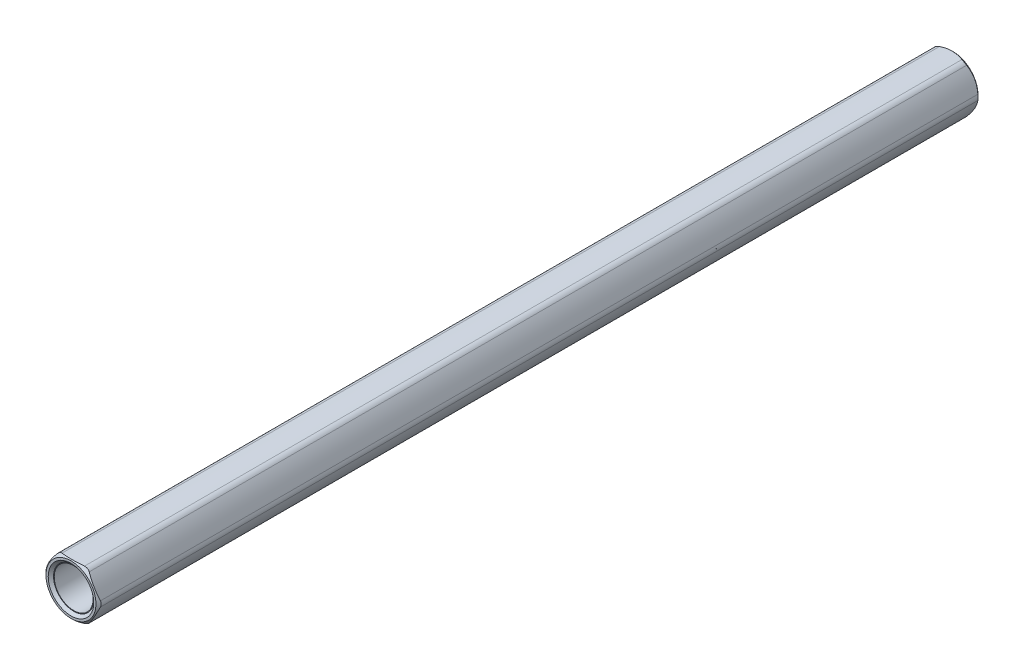
SolidWorks part; units mm, degrees
ref_plane "Plano frontal" through (0, 0, 0) normal (0, 0, 1) x (1, 0, 0)
ref_plane "Plano superior" through (0, 0, 0) normal (0, 1, 0) x (1, 0, 0)
ref_plane "Plano direito" through (0, 0, 0) normal (1, 0, 0) x (0, 0, -1)
sketch "Esboço3" plane through (0, 0, 0) normal (0, 0, 1) x (1, 0, 0)
  line L0 (0, 5.0834) -> (0, -4.3999) construction
  line L1 (-4.4917, 0) -> (4.1075, 0) construction
  line L2 (-2.4597, -4.2603) -> (2.3715, 4.1075) construction
  line L3 (-2.5933, 4.4917) -> (2.4956, -4.3226) construction
  line L4 (0, 0) -> (-4.3243, 2.4966) construction
  circle A0 centre (0, 0) radius 2.9
  circle A1 centre (0, 0) radius 4.1229 construction
  circle A2 centre (0, 0) radius 3.85 construction
  arc A3 (-1.6791, 3.7083) -> (-2.3719, 3.3083) centre (-1.4864, 2.5746) ccw
  arc A4 (1.6791, 3.7083) -> (2.3719, 3.3083) centre (1.4864, 2.5746) cw
  arc A5 (-1.6791, 3.7083) -> (1.6791, 3.7083) centre (0, -6.1714) cw
  arc A6 (-1.6791, -3.7083) -> (-2.3719, -3.3083) centre (-1.4864, -2.5746) cw
  arc A7 (-1.6791, -3.7083) -> (1.6791, -3.7083) centre (0, 6.1714) ccw
  arc A8 (1.6791, -3.7083) -> (2.3719, -3.3083) centre (1.4864, -2.5746) ccw
  arc A9 (-4.0511, -0.4) -> (-4.0511, 0.4) centre (-2.9729, 0) cw
  arc A10 (-2.3719, -3.3083) -> (-4.0511, -0.4) centre (5.3446, 3.0857) cw
  arc A11 (4.0511, -0.4) -> (2.3719, -3.3083) centre (-5.3446, 3.0857) cw
  arc A12 (4.0511, -0.4) -> (4.0511, 0.4) centre (2.9729, 0) ccw
  arc A13 (-2.3719, 3.3083) -> (-4.0511, 0.4) centre (5.3446, -3.0857) ccw
  arc A14 (4.0511, 0.4) -> (2.3719, 3.3083) centre (-5.3446, -3.0857) ccw
  arc A15 (1.6791, 3.7083) -> (2.3719, 3.3083) centre (2.4838, 4.3021) ccw construction
  arc A16 (-1.6791, 3.7083) -> (-2.3719, 3.3083) centre (-2.4838, 4.3021) cw construction
  arc A17 (-4.0511, -0.4) -> (-4.0511, 0.4) centre (-4.9676, 0) ccw construction
  arc A18 (1.6791, -3.7083) -> (2.3719, -3.3083) centre (2.4838, -4.3021) cw construction
  arc A19 (-1.6791, -3.7083) -> (-2.3719, -3.3083) centre (-2.4838, -4.3021) ccw construction
  arc A20 (4.0511, -0.4) -> (4.0511, 0.4) centre (4.9676, 0) cw construction
  dimension "D2" = 30
  dimension "D1" = 1
  dimension "D3" = 5.8
  dimension "D4" = 1.15
  dimension "D5" = 7.7
  dimension "D6" = 0.8
  dimension "D7" = 10.0214
extrude "Extrusão2" add sketch "Esboço3" along normal mid plane 131.7
sketch "Esboço5" plane through (0, 0, 0) normal (1, 0, 0) x (0, 0, -1)
  line L0 (65.85, 3.73) -> (65.1249, 4.4551)
  line L3 (65.85, 0.4) -> (65.85, 3.3083) construction
  line L4 (65.85, 3.73) -> (66.1249, 3.73)
  line L5 (66.1249, 3.73) -> (66.1249, 4.4551)
  line L6 (66.1249, 4.4551) -> (65.1249, 4.4551)
  line L7 (0, 18.0753) -> (0, -12.1126) construction
  line L8 (65.7399, 0) -> (64.5231, 0) construction
  line L10 (65.85, 3.4) -> (65.45, 3)
  line L11 (65.45, 3) -> (65.45, 2.7695)
  line L12 (65.45, 2.7695) -> (65.85, 2.7695)
  line L14 (65.85, 2.7695) -> (65.85, 3.4)
  line L20 (-65.85, 3.73) -> (-66.1249, 3.73)
  line L21 (-66.1249, 3.73) -> (-66.1249, 4.4551)
  line L22 (-66.1249, 4.4551) -> (-65.1249, 4.4551)
  line L23 (-65.85, 3.73) -> (-65.1249, 4.4551)
  dimension "D1" = 45
  dimension "D2" = 45
  dimension "D3" = 6.8
  dimension "D4" = 0.4
  dimension "D5" = 1
  dimension "D6" = 0.7251
  dimension "D7" = 0.2305
  dimension "D8" = 7.46
revolve "Corte-Revolução2" cut sketch "Esboço5" angle 360 about L8
sketch "Esboço6" plane through (0, 0, 0) normal (1, 0, 0) x (0, 0, -1)
  spline S0 degree 3 poles (-65.3052, 9.1445) (-95.5287, 9.1023) (-84.7486, -39.8758) (-33.441, -3.2353) (20.8638, -19.2387) (18.4655, 28.604) (-36.2382, 2.3588) (-65.3052, 9.1445) (-95.5287, 9.1023) (-84.7486, -39.8758) knots -0.436925 -0.205151 -0.0754 0 0.069399 0.358665 0.501001 0.563075 0.794849 0.9246 1 1.069399 1.358665 1.501001 only from (-90.892, 4.6772) to (-90.892, 4.6772)
extrude "Corte-extrusão1" [suppressed] cut sketch "Esboço6" against normal mid plane 30
ref_plane "Plano1" through (0, 0, 0) normal (0.866, -0.5, 0) x (0, 0, -1)
ref_plane "Plano2" through (5.1962, -3, 0) normal (0.866, -0.5, 0) x (0, 0, -1)
sketch "Esboço7" [suppressed] plane through (5.1962, -3, 0) normal (0.866, -0.5, 0) x (0, 0, -1)
  line L0 (-28, -1.278) -> (-6, -1.278) construction
  line L1 (-64.6615, -1.678) -> (64.6615, -1.678) construction
  line L2 (-65, 3.73) -> (-65, -3.73) construction
  text T0 "<i>COMPACTOR</i>" font "Century Gothic" height 2.5
  dimension "D1" = 0.4
  dimension "D2" = 37
  dimension "D3" = 22
extrude "Ressalto-extrusão1" [suppressed] add sketch "Esboço7" against normal up to surface (2.1727 mm away)
sketch "Esboço8" [suppressed] plane through (5.1962, -3, 0) normal (0.866, -0.5, 0) x (0, 0, -1)
  line L0 (-2.6467, -1.278) -> (32.1853, -1.278) construction
  line L1 (-64.6615, -1.678) -> (64.6615, -1.678) construction
  text T0 "MICROLINE 0,4mm" font "Century Gothic" height 2.5
  dimension "D1" = 0.4
  dimension "D2" = 3
extrude "Ressalto-extrusão3" [suppressed] add sketch "Esboço8" against normal up to surface (2.2416 mm away)
sketch "Esboço10" [suppressed] plane through (0, 0, 65) normal (0, 0, 1) x (1, 0, 0)
  line L0 (-6.5978, 3.8092) -> (3.3169, -1.915) construction
  line L1 (4.0953, -0.4184) -> (6.3737, -1.3192)
  line L2 (4.3293, -4.8602) -> (2.1793, -3.6189)
  arc A0 (2.3708, -3.3064) -> (4.0488, -0.4) centre (-6.5978, 3.8092) ccw construction
  arc A1 (2.1353, -3.5935) -> (4.0488, -0.4) centre (-6.5978, 3.8092) ccw construction
  arc A2 (4.3293, -4.8602) -> (6.3737, -1.3192) centre (-6.5978, 3.8092) ccw
  arc A3 (2.3708, -3.3064) -> (4.0488, -0.4) centre (-6.5978, 3.8092) ccw construction
  arc A4 (2.1793, -3.6189) -> (4.0953, -0.4184) centre (-6.5978, 3.8092) ccw
  arc A6 (2.1734, -3.6258) -> (4.0953, -0.4184) centre (-6.5978, 3.8092) ccw construction
  dimension "D1" = 2.5
  dimension "D2" = 0.05
extrude "Corte-extrusão2" [suppressed] cut sketch "Esboço10" against normal through all
mirror "Espelhar1" about plane through (0, 0, 0) normal (0, 0, 1) of "Corte-Revolução2"
sketch "Esboço11" plane through (0, 0, 0) normal (0, 1, 0) x (1, 0, 0)
  line L0 (-1.2, -27.06) -> (-1.2, -26.7716)
  line L1 (1.2, -27.06) -> (1.2, -26.7716)
  line L2 (0, 0) -> (0, -29.8312) construction
  line L3 (1.2, -26.4832) -> (1.2, -26.1948)
  line L4 (-1.2, -26.4832) -> (-1.2, -26.1948)
  line L5 (1.2, -25.906) -> (1.2, -25.3292)
  line L6 (-1.2, -25.906) -> (-1.2, -25.3292)
  line L7 (-1.2, -25.0408) -> (-1.2, -24.1755)
  line L8 (1.2, -25.0408) -> (1.2, -24.1755)
  line L9 (1.2, -23.5988) -> (1.2, -23.3104)
  line L10 (-1.2, -23.5988) -> (-1.2, -23.3104)
  line L11 (-1.2, -23.022) -> (-1.2, -22.1567)
  line L12 (1.2, -23.022) -> (1.2, -22.1567)
  line L13 (1.2, -21.8683) -> (1.2, -21.5799)
  line L14 (-1.2, -21.8683) -> (-1.2, -21.5799)
  line L15 (-1.2, -21.2914) -> (-1.2, -20.1377)
  line L16 (1.2, -21.2914) -> (1.2, -20.1377)
  line L17 (1.2, -19.8496) -> (1.2, -18.9843)
  line L18 (-1.2, -19.8496) -> (-1.2, -18.9843)
  line L19 (-1.2, -18.4074) -> (-1.2, -18.119)
  line L20 (1.2, -18.4074) -> (1.2, -18.119)
  line L21 (1.2, -17.8308) -> (1.2, -16.9656)
  line L22 (-1.2, -17.8308) -> (-1.2, -16.9656)
  line L23 (-1.2, -16.6771) -> (-1.2, -16.1)
  line L24 (1.2, -16.6771) -> (1.2, -16.1)
  line L25 (-1.2, -15.5234) -> (-1.2, -14.9465)
  line L26 (1.2, -15.5234) -> (1.2, -14.9465)
  line L27 (1.2, -14.6584) -> (1.2, -14.0812)
  line L28 (-1.2, -14.6584) -> (-1.2, -14.0812)
  line L29 (-1.2, -13.7928) -> (-1.2, -13.5044)
  line L30 (1.2, -13.7928) -> (1.2, -13.5044)
  line L31 (-1.2, -13.2162) -> (-1.2, -12.9278)
  line L32 (1.2, -13.2162) -> (1.2, -12.9278)
  line L33 (1.2, -12.6391) -> (1.2, -11.774)
  line L34 (-1.2, -12.6391) -> (-1.2, -11.774)
  line L35 (-1.2, -11.1972) -> (-1.2, -10.9088)
  line L36 (1.2, -11.1972) -> (1.2, -10.9088)
  line L37 (-1.2, -10.6206) -> (-1.2, -10.3322)
  line L38 (1.2, -10.6206) -> (1.2, -10.3322)
  line L39 (1.2, -9.1782) -> (1.2, -8.8897)
  line L40 (-1.2, -9.1782) -> (-1.2, -8.8897)
  line L41 (-1.2, -8.6016) -> (-1.2, -8.3132)
  line L42 (1.2, -8.6016) -> (1.2, -8.3132)
  line L43 (1.2, -8.0244) -> (1.2, -7.736)
  line L44 (-1.2, -8.0244) -> (-1.2, -7.736)
  line L45 (-1.2, -6.5826) -> (-1.2, -6.2941)
  line L46 (1.2, -6.5826) -> (1.2, -6.2941)
  line L47 (1.2, -5.7172) -> (1.2, -5.4288)
  line L48 (-1.2, -5.7172) -> (-1.2, -5.4288)
  line L113 (-0.7504, 4.8132) -> (-0.7504, 3.9408)
  line L114 (-0.7504, 3.9408) -> (-0.9491, 3.9538)
  line L115 (-0.9491, 3.9538) -> (-0.9491, 5.0785)
  line L116 (-0.9491, 5.0785) -> (-0.7742, 5.0785)
  line L117 (-0.7742, 5.0785) -> (0.987, 4.3836)
  line L118 (0.987, 4.3836) -> (0.987, 4.1474)
  line L119 (0.987, 4.1474) -> (-0.7504, 4.8132)
  line L120 (0.987, 8.1541) -> (0.987, 7.8702)
  line L121 (0.987, 7.8702) -> (0.1354, 8.5575)
  line L122 (-0.9412, 10.2512) -> (-0.9412, 10.5508)
  line L123 (-0.9412, 10.5508) -> (-0.127, 9.8693)
  line L124 (-0.7369, 12.5207) -> (-0.7369, 11.733)
  line L125 (0.8382, 11.3988) -> (0.6554, 11.4838)
  line L126 (0.109, 11.68) -> (0.0853, 11.4996)
  line L127 (0.0853, 11.4996) -> (-0.9491, 11.5498)
  line L128 (-0.9491, 11.5498) -> (-0.9491, 12.5418)
  line L129 (-0.9491, 12.5418) -> (-0.7369, 12.5207)
  line L130 (-0.7504, 14.2174) -> (-0.7504, 13.3451)
  line L131 (-0.7504, 13.3451) -> (-0.9491, 13.358)
  line L132 (-0.9491, 13.358) -> (-0.9491, 14.4827)
  line L133 (-0.9491, 14.4827) -> (-0.7742, 14.4827)
  line L134 (-0.7742, 14.4827) -> (0.987, 13.7879)
  line L135 (0.987, 13.7879) -> (0.987, 13.5516)
  line L136 (0.987, 13.5516) -> (-0.7504, 14.2174)
  line L137 (-0.4613, 16.2018) -> (-0.4531, 16.2018)
  line L138 (0.2045, 15.8572) -> (0.7878, 15.3108)
  line L139 (0.7878, 15.3108) -> (0.7878, 16.21)
  line L140 (0.7878, 16.21) -> (0.987, 16.1939)
  line L141 (0.987, 16.1939) -> (0.987, 15.0613)
  line L142 (0.987, 15.0613) -> (0.7748, 15.0323)
  line L143 (0.7748, 15.0323) -> (0.032, 15.7006)
  line L144 (-0.4348, 15.9526) -> (-0.4478, 15.9526)
  line L145 (-0.6255, 15.1782) -> (-0.8194, 15.1014)
  line L146 (0.0506, 19.0185) -> (-0.1402, 19.0185)
  line L147 (-0.6522, 18.8091) -> (-0.8404, 18.7346)
  line L148 (0.8676, 18.7346) -> (0.6796, 18.8091)
  line L149 (-0.9412, 21.2437) -> (-0.9412, 21.5435)
  line L150 (-0.9412, 21.5435) -> (-0.127, 20.8616)
  line L151 (-0.9491, 24.9844) -> (0.9869, 24.9844)
  line L152 (0.9869, 24.9844) -> (0.9869, 24.7535)
  line L153 (0.9869, 24.7535) -> (-0.7104, 24.7535)
  line L154 (-0.5645, 24.4724) -> (-0.753, 24.4247)
  line L155 (-0.9491, 24.7772) -> (-0.9491, 24.9844)
  line L156 (-0.4613, 27.0648) -> (-0.4531, 27.0648)
  line L157 (0.2045, 26.7202) -> (0.7878, 26.1736)
  line L158 (0.7878, 26.1736) -> (0.7878, 27.0728)
  line L159 (0.7878, 27.0728) -> (0.987, 27.0569)
  line L160 (0.987, 27.0569) -> (0.987, 25.9244)
  line L161 (0.987, 25.9244) -> (0.7748, 25.895)
  line L162 (0.7748, 25.895) -> (0.032, 26.5636)
  line L163 (-0.4348, 26.8153) -> (-0.4478, 26.8153)
  line L164 (-0.6255, 26.0412) -> (-0.8194, 25.9639)
  line L165 (1.2, -27.06) -> (-1.2, -27.06)
  line L167 (-1.2, -26.7716) -> (1.2, -26.7716)
  line L169 (1.2, -26.4832) -> (-1.2, -26.4832)
  line L171 (-1.2, -26.1948) -> (1.2, -26.1948)
  line L173 (1.2, -25.906) -> (-1.2, -25.906)
  line L175 (-1.2, -25.3292) -> (1.2, -25.3292)
  line L177 (1.2, -25.0408) -> (-1.2, -25.0408)
  line L179 (-1.2, -24.1755) -> (1.2, -24.1755)
  line L181 (1.2, -23.5988) -> (-1.2, -23.5988)
  line L183 (-1.2, -23.3104) -> (1.2, -23.3104)
  line L185 (1.2, -23.022) -> (-1.2, -23.022)
  line L187 (-1.2, -22.1567) -> (1.2, -22.1567)
  line L189 (1.2, -21.8683) -> (-1.2, -21.8683)
  line L191 (-1.2, -21.5799) -> (1.2, -21.5799)
  line L193 (1.2, -21.2914) -> (-1.2, -21.2914)
  line L195 (-1.2, -20.1377) -> (1.2, -20.1377)
  line L197 (1.2, -19.8496) -> (-1.2, -19.8496)
  line L199 (-1.2, -18.9843) -> (1.2, -18.9843)
  line L201 (1.2, -18.4074) -> (-1.2, -18.4074)
  line L203 (-1.2, -18.119) -> (1.2, -18.119)
  line L205 (1.2, -17.8308) -> (-1.2, -17.8308)
  line L207 (-1.2, -16.9656) -> (1.2, -16.9656)
  line L209 (1.2, -16.6771) -> (-1.2, -16.6771)
  line L211 (-1.2, -16.1) -> (1.2, -16.1)
  line L213 (1.2, -15.5234) -> (-1.2, -15.5234)
  line L215 (-1.2, -14.9465) -> (1.2, -14.9465)
  line L217 (1.2, -14.6584) -> (-1.2, -14.6584)
  line L219 (-1.2, -14.0812) -> (1.2, -14.0812)
  line L221 (1.2, -13.7928) -> (-1.2, -13.7928)
  line L223 (-1.2, -13.5044) -> (1.2, -13.5044)
  line L225 (1.2, -13.2162) -> (-1.2, -13.2162)
  line L227 (-1.2, -12.9278) -> (1.2, -12.9278)
  line L229 (1.2, -12.6391) -> (-1.2, -12.6391)
  line L231 (-1.2, -11.774) -> (1.2, -11.774)
  line L233 (1.2, -11.1972) -> (-1.2, -11.1972)
  line L235 (-1.2, -10.9088) -> (1.2, -10.9088)
  line L237 (1.2, -10.6206) -> (-1.2, -10.6206)
  line L239 (-1.2, -10.3322) -> (1.2, -10.3322)
  line L241 (1.2, -9.1782) -> (-1.2, -9.1782)
  line L243 (-1.2, -8.8897) -> (1.2, -8.8897)
  line L245 (1.2, -8.6016) -> (-1.2, -8.6016)
  line L247 (-1.2, -8.3132) -> (1.2, -8.3132)
  line L249 (1.2, -8.0244) -> (-1.2, -8.0244)
  line L251 (-1.2, -7.736) -> (1.2, -7.736)
  line L253 (1.2, -6.5826) -> (-1.2, -6.5826)
  line L255 (-1.2, -6.2941) -> (1.2, -6.2941)
  line L257 (1.2, -5.7172) -> (-1.2, -5.7172)
  line L259 (-1.2, -5.4288) -> (1.2, -5.4288)
  line L261 (1.2, -4.5636) -> (-1.2, -4.5636)
  line L263 (-1.2, -3.987) -> (1.2, -3.987)
  line L265 (1.2, -3.4098) -> (-1.2, -3.4098)
  line L267 (-1.2, -2.8332) -> (1.2, -2.8332)
  line L269 (1.2, -2.5445) -> (-1.2, -2.5445)
  line L271 (-1.2, -1.968) -> (1.2, -1.968)
  line L273 (1.2, -1.6792) -> (-1.2, -1.6792)
  line L275 (-1.2, -1.1027) -> (1.2, -1.1027)
  line L277 (1.2, -0.5258) -> (-1.2, -0.5258)
  line L279 (-1.2, -0.2374) -> (1.2, -0.2374)
  line L281 (1.2, 0.0508) -> (-1.2, 0.0508)
  line L283 (-1.2, 0.3392) -> (1.2, 0.3392)
  line L285 (-1.2, -4.5636) -> (-1.2, -3.987)
  line L286 (1.2, -4.5636) -> (1.2, -3.987)
  line L287 (-1.2, -3.4098) -> (-1.2, -2.8332)
  line L288 (1.2, -3.4098) -> (1.2, -2.8332)
  line L289 (1.2, -2.5445) -> (1.2, -1.968)
  line L290 (-1.2, -2.5445) -> (-1.2, -1.968)
  line L291 (-1.2, -1.6792) -> (-1.2, -1.1027)
  line L292 (1.2, -1.6792) -> (1.2, -1.1027)
  line L293 (-1.2, -0.5258) -> (-1.2, -0.2374)
  line L294 (1.2, -0.5258) -> (1.2, -0.2374)
  line L295 (1.2, 0.0508) -> (1.2, 0.3392)
  line L296 (-1.2, 0.0508) -> (-1.2, 0.3392)
  line L297 (0, 0) -> (-2.5, 0) construction
  line L298 (-2.5, -30.7084) -> (2.5, -30.7084)
  line L299 (-2.5, -30.7084) -> (-2.5, 30.7084)
  line L300 (-2.5, 30.7084) -> (2.5, 30.7084)
  line L301 (2.5, -30.7084) -> (2.5, 30.7084)
  spline S111 degree 3 poles (-0.5035, 6.0516) (-0.2969, 6.0516) (-0.1719, 6.1764) (-0.1191, 6.4124) knots 0 0 0 0 0.2 0.2 0.2 0.2
  spline S112 degree 3 poles (-0.1191, 6.4124) (-0.1719, 6.6485) (-0.2969, 6.768) (-0.5035, 6.768) knots 0.2 0.2 0.2 0.2 0.4 0.4 0.4 0.4
  spline S113 degree 3 poles (-0.5035, 6.768) (-0.6894, 6.768) (-0.7982, 6.6034) (-0.7982, 6.4124) knots 0.4 0.4 0.4 0.4 0.6 0.6 0.6 0.6
  spline S114 degree 3 poles (-0.7982, 6.4124) (-0.7982, 6.2212) (-0.6894, 6.0516) (-0.5035, 6.0516) knots 0.6 0.6 0.6 0.6 1 1 1 1
  spline S115 degree 3 poles (0.4724, 6.004) (0.69, 6.004) (0.8198, 6.1817) (0.8198, 6.4124) knots 0 0 0 0 0.2 0.2 0.2 0.2
  spline S116 degree 3 poles (0.8198, 6.4124) (0.8198, 6.6432) (0.69, 6.8128) (0.4724, 6.8128) knots 0.2 0.2 0.2 0.2 0.4 0.4 0.4 0.4
  spline S117 degree 3 poles (0.4724, 6.8128) (0.2577, 6.8128) (0.1304, 6.6432) (0.0774, 6.4124) knots 0.4 0.4 0.4 0.4 0.6 0.6 0.6 0.6
  spline S118 degree 3 poles (0.0774, 6.4124) (0.1304, 6.1817) (0.2577, 6.004) (0.4724, 6.004) knots 0.6 0.6 0.6 0.6 1 1 1 1
  spline S119 degree 3 poles (0.4882, 5.7759) (0.239, 5.7759) (0.048, 5.9272) (-0.0342, 6.1789) knots 0 0 0 0 0.111111 0.111111 0.111111 0.111111
  spline S120 degree 3 poles (-0.0342, 6.1789) (-0.1134, 5.9563) (-0.2647, 5.8208) (-0.501, 5.8208) knots 0.111111 0.111111 0.111111 0.111111 0.222222 0.222222 0.222222 0.222222
  spline S121 degree 3 poles (-0.501, 5.8208) (-0.8139, 5.8208) (-0.9889, 6.0703) (-0.9889, 6.4124) knots 0.222222 0.222222 0.222222 0.222222 0.333333 0.333333 0.333333 0.333333
  spline S122 degree 3 poles (-0.9889, 6.4124) (-0.9889, 6.7547) (-0.8139, 6.996) (-0.501, 6.996) knots 0.333333 0.333333 0.333333 0.333333 0.444444 0.444444 0.444444 0.444444
  spline S123 degree 3 poles (-0.501, 6.996) (-0.2647, 6.996) (-0.1134, 6.8712) (-0.0342, 6.6672) knots 0.444444 0.444444 0.444444 0.444444 0.555556 0.555556 0.555556 0.555556
  spline S124 degree 3 poles (-0.0342, 6.6672) (0.048, 6.8977) (0.239, 7.0411) (0.4882, 7.0411) knots 0.555556 0.555556 0.555556 0.555556 0.666667 0.666667 0.666667 0.666667
  spline S125 degree 3 poles (0.4882, 7.0411) (0.8331, 7.0411) (1.0162, 6.7572) (1.0162, 6.4124) knots 0.666667 0.666667 0.666667 0.666667 0.777778 0.777778 0.777778 0.777778
  spline S126 degree 3 poles (1.0162, 6.4124) (1.0162, 6.0677) (0.8331, 5.7759) (0.4882, 5.7759) knots 0.777778 0.777778 0.777778 0.777778 1 1 1 1
  spline S127 degree 3 poles (-0.7899, 8.3212) (-0.7899, 8.056) (-0.6042, 7.9024) (-0.3816, 7.9024) knots 0 0 0 0 0.2 0.2 0.2 0.2
  spline S128 degree 3 poles (-0.3816, 7.9024) (-0.1428, 7.9024) (0.0189, 8.0508) (0.0189, 8.3133) knots 0.2 0.2 0.2 0.2 0.4 0.4 0.4 0.4
  spline S129 degree 3 poles (0.0189, 8.3133) (0.0189, 8.5998) (-0.164, 8.7138) (-0.387, 8.7138) knots 0.4 0.4 0.4 0.4 0.6 0.6 0.6 0.6
  spline S130 degree 3 poles (-0.387, 8.7138) (-0.6096, 8.7138) (-0.7899, 8.5893) (-0.7899, 8.3212) knots 0.6 0.6 0.6 0.6 1 1 1 1
  spline S131 degree 3 poles (-0.3762, 7.6583) (-0.7211, 7.6583) (-0.9892, 7.9182) (-0.9892, 8.3133) knots 0 0 0 0 0.111111 0.111111 0.111111 0.111111
  spline S132 degree 3 poles (-0.9892, 8.3133) (-0.9892, 8.7271) (-0.7132, 8.958) (-0.3632, 8.958) knots 0.111111 0.111111 0.111111 0.111111 0.222222 0.222222 0.222222 0.222222
  spline S133 degree 3 poles (-0.3632, 8.958) (-0.1055, 8.958) (0.0641, 8.8755) (0.3344, 8.6768) knots 0.222222 0.222222 0.222222 0.222222 0.333333 0.333333 0.333333 0.333333
  spline S134 degree 2 poles (0.3344, 8.6768) (0.5015, 8.5521) (0.987, 8.1541) knots 0.333333 0.333333 0.333333 0.444444 0.444444 0.444444
  spline S135 degree 3 poles (0.1354, 8.5575) (0.1809, 8.475) (0.2125, 8.3689) (0.2125, 8.2656) knots 0.666667 0.666667 0.666667 0.666667 0.777778 0.777778 0.777778 0.777778
  spline S136 degree 3 poles (0.2125, 8.2656) (0.2125, 7.9394) (-0.0183, 7.6583) (-0.3762, 7.6583) knots 0.777778 0.777778 0.777778 0.777778 1 1 1 1
  spline S137 degree 3 poles (0.8198, 10.1132) (0.8198, 10.3784) (0.6316, 10.5244) (0.409, 10.5244) knots 0 0 0 0 0.2 0.2 0.2 0.2
  spline S138 degree 3 poles (0.409, 10.5244) (0.1702, 10.5244) (-0.0104, 10.3759) (-0.0104, 10.1132) knots 0.2 0.2 0.2 0.2 0.4 0.4 0.4 0.4
  spline S139 degree 3 poles (-0.0104, 10.1132) (-0.0104, 9.8267) (0.1781, 9.7152) (0.401, 9.7152) knots 0.4 0.4 0.4 0.4 0.6 0.6 0.6 0.6
  spline S140 degree 3 poles (0.401, 9.7152) (0.6238, 9.7152) (0.8198, 9.8453) (0.8198, 10.1132) knots 0.6 0.6 0.6 0.6 1 1 1 1
  spline S141 degree 3 poles (0.4062, 10.771) (0.751, 10.771) (1.0163, 10.5164) (1.0163, 10.1213) knots 0 0 0 0 0.111111 0.111111 0.111111 0.111111
  spline S142 degree 3 poles (1.0163, 10.1213) (1.0163, 9.7073) (0.727, 9.4688) (0.3768, 9.4688) knots 0.111111 0.111111 0.111111 0.111111 0.222222 0.222222 0.222222 0.222222
  spline S143 degree 3 poles (0.3768, 9.4688) (0.0853, 9.4688) (-0.0976, 9.5668) (-0.4242, 9.8267) knots 0.222222 0.222222 0.222222 0.222222 0.333333 0.333333 0.333333 0.333333
  spline S144 degree 2 poles (-0.4242, 9.8267) (-0.5644, 9.9381) (-0.9412, 10.2512) knots 0.333333 0.333333 0.333333 0.444444 0.444444 0.444444
  spline S145 degree 3 poles (-0.127, 9.8693) (-0.1718, 9.9514) (-0.2066, 10.0576) (-0.2066, 10.1608) knots 0.666667 0.666667 0.666667 0.666667 0.777778 0.777778 0.777778 0.777778
  spline S146 degree 3 poles (-0.2066, 10.1608) (-0.2066, 10.4874) (0.048, 10.771) (0.4062, 10.771) knots 0.777778 0.777778 0.777778 0.777778 1 1 1 1
  spline S147 degree 3 poles (-0.7369, 11.733) (-0.5486, 11.7276) (-0.3152, 11.7197) (-0.127, 11.7144) knots 0.0625 0.0625 0.0625 0.0625 0.125 0.125 0.125 0.125
  spline S148 degree 3 poles (-0.127, 11.7144) (-0.1933, 11.8176) (-0.2224, 11.9212) (-0.2224, 12.0302) knots 0.125 0.125 0.125 0.125 0.1875 0.1875 0.1875 0.1875
  spline S149 degree 3 poles (-0.2224, 12.0302) (-0.2224, 12.4228) (0.0401, 12.6214) (0.3689, 12.6214) knots 0.1875 0.1875 0.1875 0.1875 0.25 0.25 0.25 0.25
  spline S150 degree 3 poles (0.3689, 12.6214) (0.7564, 12.6214) (1.0163, 12.3561) (1.0163, 11.9187) knots 0.25 0.25 0.25 0.25 0.3125 0.3125 0.3125 0.3125
  spline S151 degree 3 poles (1.0163, 11.9187) (1.0163, 11.6932) (0.9443, 11.5128) (0.8382, 11.3988) knots 0.3125 0.3125 0.3125 0.3125 0.375 0.375 0.375 0.375
  spline S152 degree 3 poles (0.6554, 11.4838) (0.7191, 11.5656) (0.8066, 11.7118) (0.8066, 11.9266) knots 0.4375 0.4375 0.4375 0.4375 0.5 0.5 0.5 0.5
  spline S153 degree 3 poles (0.8066, 11.9266) (0.8066, 12.2131) (0.6266, 12.3855) (0.3717, 12.3855) knots 0.5 0.5 0.5 0.5 0.5625 0.5625 0.5625 0.5625
  spline S154 degree 3 poles (0.3717, 12.3855) (0.1487, 12.3855) (-0.0183, 12.2503) (-0.0183, 11.9876) knots 0.5625 0.5625 0.5625 0.5625 0.625 0.625 0.625 0.625
  spline S155 degree 3 poles (-0.0183, 11.9876) (-0.0183, 11.8656) (0.019, 11.762) (0.109, 11.68) knots 0.625 0.625 0.625 0.625 0.6875 0.6875 0.6875 0.6875
  spline S156 degree 3 poles (-0.989, 15.6264) (-0.989, 15.9792) (-0.7794, 16.2018) (-0.4613, 16.2018) knots 0 0 0 0 0.0625 0.0625 0.0625 0.0625
  spline S157 degree 3 poles (-0.4531, 16.2018) (-0.2093, 16.1992) (-0.0236, 16.0694) (0.2045, 15.8572) knots 0.125 0.125 0.125 0.125 0.1875 0.1875 0.1875 0.1875
  spline S158 degree 3 poles (0.032, 15.7006) (-0.135, 15.8519) (-0.2832, 15.95) (-0.4348, 15.9526) knots 0.5625 0.5625 0.5625 0.5625 0.625 0.625 0.625 0.625
  spline S159 degree 3 poles (-0.4478, 15.9526) (-0.6628, 15.9526) (-0.7847, 15.8307) (-0.7847, 15.6105) knots 0.6875 0.6875 0.6875 0.6875 0.75 0.75 0.75 0.75
  spline S160 degree 3 poles (-0.7847, 15.6105) (-0.7847, 15.4488) (-0.7367, 15.2868) (-0.6255, 15.1782) knots 0.75 0.75 0.75 0.75 0.8125 0.8125 0.8125 0.8125
  spline S161 degree 3 poles (-0.8194, 15.1014) (-0.9202, 15.2098) (-0.989, 15.3744) (-0.989, 15.6264) knots 0.875 0.875 0.875 0.875 1 1 1 1
  spline S162 degree 3 poles (0.0058, 17.109) (0.4751, 17.109) (0.82, 17.2546) (0.82, 17.5252) knots 0 0 0 0 0.2 0.2 0.2 0.2
  spline S163 degree 3 poles (0.82, 17.5252) (0.82, 17.7959) (0.4751, 17.9392) (0.0058, 17.9392) knots 0.2 0.2 0.2 0.2 0.4 0.4 0.4 0.4
  spline S164 degree 3 poles (0.0058, 17.9392) (-0.456, 17.9392) (-0.7898, 17.7959) (-0.7898, 17.5252) knots 0.4 0.4 0.4 0.4 0.6 0.6 0.6 0.6
  spline S165 degree 3 poles (-0.7898, 17.5252) (-0.7898, 17.2546) (-0.456, 17.109) (0.0058, 17.109) knots 0.6 0.6 0.6 0.6 1 1 1 1
  spline S166 degree 3 poles (0.0137, 16.8595) (-0.5807, 16.8595) (-0.9891, 17.0743) (-0.9891, 17.5252) knots 0 0 0 0 0.2 0.2 0.2 0.2
  spline S167 degree 3 poles (-0.9891, 17.5252) (-0.9891, 17.9762) (-0.5807, 18.186) (0.0137, 18.186) knots 0.2 0.2 0.2 0.2 0.4 0.4 0.4 0.4
  spline S168 degree 3 poles (0.0137, 18.186) (0.5812, 18.186) (1.0164, 17.9977) (1.0164, 17.5252) knots 0.4 0.4 0.4 0.4 0.6 0.6 0.6 0.6
  spline S169 degree 3 poles (1.0164, 17.5252) (1.0164, 17.0534) (0.5812, 16.8595) (0.0137, 16.8595) knots 0.6 0.6 0.6 0.6 1 1 1 1
  spline S170 degree 3 poles (-0.1402, 19.0185) (-0.1402, 19.316) (-0.175, 19.5971) (-0.4798, 19.5971) knots 0.0625 0.0625 0.0625 0.0625 0.125 0.125 0.125 0.125
  spline S171 degree 3 poles (-0.4798, 19.5971) (-0.6948, 19.5971) (-0.7899, 19.4695) (-0.7899, 19.2415) knots 0.125 0.125 0.125 0.125 0.1875 0.1875 0.1875 0.1875
  spline S172 degree 3 poles (-0.7899, 19.2415) (-0.7899, 19.0636) (-0.7343, 18.9127) (-0.6522, 18.8091) knots 0.1875 0.1875 0.1875 0.1875 0.25 0.25 0.25 0.25
  spline S173 degree 3 poles (-0.8404, 18.7346) (-0.9307, 18.8514) (-0.9892, 19.0241) (-0.9892, 19.2916) knots 0.3125 0.3125 0.3125 0.3125 0.375 0.375 0.375 0.375
  spline S174 degree 3 poles (-0.9892, 19.2916) (-0.9892, 19.5781) (-0.8193, 19.8463) (-0.5088, 19.8463) knots 0.375 0.375 0.375 0.375 0.4375 0.4375 0.4375 0.4375
  spline S175 degree 3 poles (-0.5088, 19.8463) (-0.2596, 19.8463) (-0.1083, 19.7164) (-0.0446, 19.5068) knots 0.4375 0.4375 0.4375 0.4375 0.5 0.5 0.5 0.5
  spline S176 degree 3 poles (-0.0446, 19.5068) (0.0085, 19.7427) (0.1834, 19.894) (0.4566, 19.894) knots 0.5 0.5 0.5 0.5 0.5625 0.5625 0.5625 0.5625
  spline S177 degree 3 poles (0.4566, 19.894) (0.8015, 19.894) (1.0163, 19.6182) (1.0163, 19.2415) knots 0.5625 0.5625 0.5625 0.5625 0.625 0.625 0.625 0.625
  spline S178 degree 3 poles (1.0163, 19.2415) (1.0163, 18.9894) (0.9364, 18.8065) (0.8676, 18.7346) knots 0.625 0.625 0.625 0.625 0.6875 0.6875 0.6875 0.6875
  spline S179 degree 3 poles (0.6796, 18.8091) (0.7564, 18.907) (0.8198, 19.0424) (0.8198, 19.2386) knots 0.75 0.75 0.75 0.75 0.8125 0.8125 0.8125 0.8125
  spline S180 degree 3 poles (0.8198, 19.2386) (0.8198, 19.4935) (0.6901, 19.6659) (0.4541, 19.6659) knots 0.8125 0.8125 0.8125 0.8125 0.875 0.875 0.875 0.875
  spline S181 degree 3 poles (0.4541, 19.6659) (0.1062, 19.6659) (0.0506, 19.3795) (0.0506, 19.0185) knots 0.875 0.875 0.875 0.875 1 1 1 1
  spline S182 degree 3 poles (0.8198, 21.106) (0.8198, 21.371) (0.6316, 21.5169) (0.409, 21.5169) knots 0 0 0 0 0.2 0.2 0.2 0.2
  spline S183 degree 3 poles (0.409, 21.5169) (0.1702, 21.5169) (-0.0104, 21.3684) (-0.0104, 21.106) knots 0.2 0.2 0.2 0.2 0.4 0.4 0.4 0.4
  spline S184 degree 3 poles (-0.0104, 21.106) (-0.0104, 20.8196) (0.1781, 20.708) (0.401, 20.708) knots 0.4 0.4 0.4 0.4 0.6 0.6 0.6 0.6
  spline S185 degree 3 poles (0.401, 20.708) (0.6238, 20.708) (0.8198, 20.8379) (0.8198, 21.106) knots 0.6 0.6 0.6 0.6 1 1 1 1
  spline S186 degree 3 poles (0.4062, 21.7636) (0.751, 21.7636) (1.0163, 21.509) (1.0163, 21.1139) knots 0 0 0 0 0.111111 0.111111 0.111111 0.111111
  spline S187 degree 3 poles (1.0163, 21.1139) (1.0163, 20.7002) (0.727, 20.4612) (0.3768, 20.4612) knots 0.111111 0.111111 0.111111 0.111111 0.222222 0.222222 0.222222 0.222222
  spline S188 degree 3 poles (0.3768, 20.4612) (0.0853, 20.4612) (-0.0976, 20.5596) (-0.4242, 20.8196) knots 0.222222 0.222222 0.222222 0.222222 0.333333 0.333333 0.333333 0.333333
  spline S189 degree 2 poles (-0.4242, 20.8196) (-0.5644, 20.931) (-0.9412, 21.2437) knots 0.333333 0.333333 0.333333 0.444444 0.444444 0.444444
  spline S190 degree 3 poles (-0.127, 20.8616) (-0.1718, 20.9443) (-0.2066, 21.0504) (-0.2066, 21.1537) knots 0.666667 0.666667 0.666667 0.666667 0.777778 0.777778 0.777778 0.777778
  spline S191 degree 3 poles (-0.2066, 21.1537) (-0.2066, 21.4796) (0.048, 21.7636) (0.4062, 21.7636) knots 0.777778 0.777778 0.777778 0.777778 1 1 1 1
  spline S192 degree 3 poles (-0.5035, 22.7193) (-0.2969, 22.7193) (-0.1719, 22.8438) (-0.1191, 23.0803) knots 0 0 0 0 0.2 0.2 0.2 0.2
  spline S193 degree 3 poles (-0.1191, 23.0803) (-0.1719, 23.3163) (-0.2969, 23.4356) (-0.5035, 23.4356) knots 0.2 0.2 0.2 0.2 0.4 0.4 0.4 0.4
  spline S194 degree 3 poles (-0.5035, 23.4356) (-0.6894, 23.4356) (-0.7982, 23.2711) (-0.7982, 23.0803) knots 0.4 0.4 0.4 0.4 0.6 0.6 0.6 0.6
  spline S195 degree 3 poles (-0.7982, 23.0803) (-0.7982, 22.8892) (-0.6894, 22.7193) (-0.5035, 22.7193) knots 0.6 0.6 0.6 0.6 1 1 1 1
  spline S196 degree 3 poles (0.4724, 22.6716) (0.69, 22.6716) (0.8198, 22.8495) (0.8198, 23.0803) knots 0 0 0 0 0.2 0.2 0.2 0.2
  spline S197 degree 3 poles (0.8198, 23.0803) (0.8198, 23.3112) (0.69, 23.4808) (0.4724, 23.4808) knots 0.2 0.2 0.2 0.2 0.4 0.4 0.4 0.4
  spline S198 degree 3 poles (0.4724, 23.4808) (0.2577, 23.4808) (0.1304, 23.3112) (0.0774, 23.0803) knots 0.4 0.4 0.4 0.4 0.6 0.6 0.6 0.6
  spline S199 degree 3 poles (0.0774, 23.0803) (0.1304, 22.8495) (0.2577, 22.6716) (0.4724, 22.6716) knots 0.6 0.6 0.6 0.6 1 1 1 1
  spline S200 degree 3 poles (0.4882, 22.4433) (0.239, 22.4433) (0.048, 22.5949) (-0.0342, 22.8466) knots 0 0 0 0 0.111111 0.111111 0.111111 0.111111
  spline S201 degree 3 poles (-0.0342, 22.8466) (-0.1134, 22.6243) (-0.2647, 22.4885) (-0.501, 22.4885) knots 0.111111 0.111111 0.111111 0.111111 0.222222 0.222222 0.222222 0.222222
  spline S202 degree 3 poles (-0.501, 22.4885) (-0.8139, 22.4885) (-0.9889, 22.7383) (-0.9889, 23.0803) knots 0.222222 0.222222 0.222222 0.222222 0.333333 0.333333 0.333333 0.333333
  spline S203 degree 3 poles (-0.9889, 23.0803) (-0.9889, 23.4224) (-0.8139, 23.6636) (-0.501, 23.6636) knots 0.333333 0.333333 0.333333 0.333333 0.444444 0.444444 0.444444 0.444444
  spline S204 degree 3 poles (-0.501, 23.6636) (-0.2647, 23.6636) (-0.1134, 23.5392) (-0.0342, 23.3348) knots 0.444444 0.444444 0.444444 0.444444 0.555556 0.555556 0.555556 0.555556
  spline S205 degree 3 poles (-0.0342, 23.3348) (0.048, 23.5655) (0.239, 23.7088) (0.4882, 23.7088) knots 0.555556 0.555556 0.555556 0.555556 0.666667 0.666667 0.666667 0.666667
  spline S206 degree 3 poles (0.4882, 23.7088) (0.8331, 23.7088) (1.0162, 23.4252) (1.0162, 23.0803) knots 0.666667 0.666667 0.666667 0.666667 0.777778 0.777778 0.777778 0.777778
  spline S207 degree 3 poles (1.0162, 23.0803) (1.0162, 22.7354) (0.8331, 22.4433) (0.4882, 22.4433) knots 0.777778 0.777778 0.777778 0.777778 1 1 1 1
  spline S208 degree 3 poles (-0.7104, 24.7535) (-0.6443, 24.6502) (-0.5938, 24.5655) (-0.5645, 24.4724) knots 0.375 0.375 0.375 0.375 0.5 0.5 0.5 0.5
  spline S209 degree 3 poles (-0.753, 24.4247) (-0.8035, 24.5387) (-0.8778, 24.6742) (-0.9491, 24.7772) knots 0.625 0.625 0.625 0.625 0.75 0.75 0.75 0.75
  spline S210 degree 3 poles (-0.989, 26.4894) (-0.989, 26.8421) (-0.7794, 27.0648) (-0.4613, 27.0648) knots 0 0 0 0 0.0625 0.0625 0.0625 0.0625
  spline S211 degree 3 poles (-0.4531, 27.0648) (-0.2093, 27.0623) (-0.0236, 26.9319) (0.2045, 26.7202) knots 0.125 0.125 0.125 0.125 0.1875 0.1875 0.1875 0.1875
  spline S212 degree 3 poles (0.032, 26.5636) (-0.135, 26.7148) (-0.2832, 26.8128) (-0.4348, 26.8153) knots 0.5625 0.5625 0.5625 0.5625 0.625 0.625 0.625 0.625
  spline S213 degree 3 poles (-0.4478, 26.8153) (-0.6628, 26.8153) (-0.7847, 26.6934) (-0.7847, 26.4733) knots 0.6875 0.6875 0.6875 0.6875 0.75 0.75 0.75 0.75
  spline S214 degree 3 poles (-0.7847, 26.4733) (-0.7847, 26.3113) (-0.7367, 26.1499) (-0.6255, 26.0412) knots 0.75 0.75 0.75 0.75 0.8125 0.8125 0.8125 0.8125
  spline S215 degree 3 poles (-0.8194, 25.9639) (-0.9202, 26.0728) (-0.989, 26.2371) (-0.989, 26.4894) knots 0.875 0.875 0.875 0.875 1 1 1 1
  dimension "D1" = 5
  dimension "D2" = 61.4168
extrude "Corte-extrusão3" [suppressed] cut sketch "Esboço11" against normal blind 4.4 from offset 8 contours L171 L4 L169 L3 | L175 L6 L173 L5 | L179 L7 L177 L8 | L183 L10 L181 L9 | L187 L11 L185 L12 | L191 L14 L189 L13 | L195 L15 L193 L16 | L199 L18 L197 L17 | L207 L22 L205 L21 | L211 L23 L209 L24 | L215 L25 L213 L26 | L219 L28 L217 L27 | L227 L31 L225 L32 | L231 L34 L229 L33 | L235 L35 L233 L36 | L239 L37 L237 L38 | L243 L40 L241 L39 | L247 L41 L245 L42 | L251 L44 L249 L43 | L255 L45 L253 L46 | L259 L48 L257 L47 | L261 L286 L263 L285 | L265 L288 L267 L287 | L290 L269 L289 L271 | L273 L292 L275 L291 | L296 L281 L295 L283 | S117 S118 S115 S116 | S113 S114 S111 S112 | S129 S130 S127 S128 | L167 L1 L165 L0 | L203 L20 L201 L19 | L221 L29 L223 L30 | L277 L293 L279 L294 | L119 L113 L114 L115 L116 L117 L118 | S126 S119 S120 S121 S122 S123 S124 S125 | S133 S134 L120 L121 S135 S136 S131 S132 | S143 S144 L122 L123 S145 S146 S141 S142 | S139 S140 S137 S138 | S147 S148 S149 S150 S151 L125 S152 S153 S154 S155 L126 L127 L128 L129 L124 | L130 L131 L132 L133 L134 L135 L136 | L138 L139 L140 L141 L142 L143 S158 L144 S159 S160 L145 S161 S156 L137 S157 | S168 S169 S166 S167 | S163 S164 S165 S162 | S177 S178 L148 S179 S180 S181 L146 S170 S171 S172 L147 S173 S174 S175 S176 | S187 S188 S189 L149 L150 S190 S191 S186 | S185 S182 S183 S184 | S206 S207 S200 S201 S202 S203 S204 S205 | S197 S198 S199 S196 | S193 S194 S195 S192 | L151 L152 L153 S208 L154 S209 L155 | S214 L164 S215 S210 L156 S211 L157 L158 L159 L160 L161 L162 S212 L163 S213
sketch "Esboço17" plane through (0, 0, 0) normal (0, 1, 0) x (1, 0, 0)
  line L0 (-1.2, -27.06) -> (-1.2, -26.7738)
  line L3 (1.2047, -27.0643) -> (1.2047, -26.7738)
  line L4 (-1.2, -26.7738) -> (1.2047, -26.7738)
  line L7 (1.2047, -26.4834) -> (1.2047, -26.193)
  line L10 (-1.2, -25.9023) -> (1.2047, -25.9023)
  line L11 (1.2047, -25.9023) -> (1.2047, -25.3211)
  line L12 (-1.2, -25.3211) -> (1.2047, -25.3211)
  line L14 (-1.2, -25.0304) -> (1.2047, -25.0304)
  line L15 (1.2047, -25.0304) -> (1.2047, -24.1589)
  line L16 (-1.2, -24.1589) -> (1.2047, -24.1589)
  line L18 (-1.2, -23.578) -> (1.2047, -23.578)
  line L19 (1.2047, -23.578) -> (1.2047, -23.2876)
  line L20 (-1.2, -23.2876) -> (1.2047, -23.2876)
  line L22 (-1.2, -22.9969) -> (1.2047, -22.9969)
  line L23 (1.2047, -22.9969) -> (1.2047, -22.1253)
  line L24 (-1.2, -22.1253) -> (1.2047, -22.1253)
  line L26 (-1.2, -21.8345) -> (1.2047, -21.8345)
  line L27 (1.2047, -21.8345) -> (1.2047, -21.5441)
  line L28 (-1.2, -21.5441) -> (1.2047, -21.5441)
  line L30 (-1.2, -21.2534) -> (1.2047, -21.2534)
  line L31 (1.2047, -21.2534) -> (1.2047, -20.0914)
  line L32 (-1.2, -20.0914) -> (1.2047, -20.0914)
  line L34 (-1.2, -19.8009) -> (1.2047, -19.8009)
  line L35 (1.2047, -19.8009) -> (1.2047, -18.9294)
  line L36 (-1.2, -18.9294) -> (1.2047, -18.9294)
  line L38 (-1.2, -18.3482) -> (1.2047, -18.3482)
  line L39 (1.2047, -18.3482) -> (1.2047, -18.0578)
  line L40 (-1.2, -18.0578) -> (1.2047, -18.0578)
  line L42 (-1.2, -17.7673) -> (1.2047, -17.7673)
  line L43 (1.2047, -17.7673) -> (1.2047, -16.8958)
  line L44 (-1.2, -16.8958) -> (1.2047, -16.8958)
  line L46 (-1.2, -16.6053) -> (1.2047, -16.6053)
  line L47 (1.2047, -16.6053) -> (1.2047, -16.0242)
  line L48 (-1.2, -16.0242) -> (1.2047, -16.0242)
  line L50 (-1.2, -15.4431) -> (1.2047, -15.4431)
  line L51 (1.2047, -15.4431) -> (1.2047, -14.8619)
  line L52 (-1.2, -14.8619) -> (1.2047, -14.8619)
  line L54 (-1.2, -14.5715) -> (1.2047, -14.5715)
  line L55 (1.2047, -14.5715) -> (1.2047, -13.9903)
  line L56 (-1.2, -13.9903) -> (1.2047, -13.9903)
  line L58 (-1.2, -13.6996) -> (1.2047, -13.6996)
  line L59 (1.2047, -13.6996) -> (1.2047, -13.4091)
  line L60 (-1.2, -13.4091) -> (1.2047, -13.4091)
  line L62 (-1.2, -13.1187) -> (1.2047, -13.1187)
  line L63 (1.2047, -13.1187) -> (1.2047, -12.8283)
  line L64 (-1.2, -12.8283) -> (1.2047, -12.8283)
  line L66 (-1.2, -12.5376) -> (1.2047, -12.5376)
  line L67 (1.2047, -12.5376) -> (1.2047, -11.6663)
  line L68 (-1.2, -11.6663) -> (1.2047, -11.6663)
  line L70 (-1.2, -11.0851) -> (1.2047, -11.0851)
  line L71 (1.2047, -11.0851) -> (1.2047, -10.7947)
  line L72 (-1.2, -10.7947) -> (1.2047, -10.7947)
  line L74 (-1.2, -10.5043) -> (1.2047, -10.5043)
  line L75 (1.2047, -10.5043) -> (1.2047, -10.2138)
  line L76 (-1.2, -10.2138) -> (1.2047, -10.2138)
  line L78 (-1.2, -9.0513) -> (1.2047, -9.0513)
  line L79 (1.2047, -9.0513) -> (1.2047, -8.7609)
  line L80 (-1.2, -8.7609) -> (1.2047, -8.7609)
  line L82 (-1.2, -8.4704) -> (1.2047, -8.4704)
  line L83 (1.2047, -8.4704) -> (1.2047, -8.18)
  line L84 (-1.2, -8.18) -> (1.2047, -8.18)
  line L86 (-1.2, -7.8893) -> (1.2047, -7.8893)
  line L87 (1.2047, -7.8893) -> (1.2047, -7.5989)
  line L88 (-1.2, -7.5989) -> (1.2047, -7.5989)
  line L90 (-1.2, -6.4365) -> (1.2047, -6.4365)
  line L91 (1.2047, -6.4365) -> (1.2047, -6.1461)
  line L92 (-1.2, -6.1461) -> (1.2047, -6.1461)
  line L94 (-1.2, -5.5649) -> (1.2047, -5.5649)
  line L95 (1.2047, -5.5649) -> (1.2047, -5.2745)
  line L96 (-1.2, -5.2745) -> (1.2047, -5.2745)
  line L98 (-1.2, -4.4029) -> (1.2047, -4.4029)
  line L99 (1.2047, -4.4029) -> (1.2047, -4.1125)
  line L100 (-1.2, -4.1125) -> (1.2047, -4.1125)
  line L102 (-1.2, -3.5311) -> (1.2047, -3.5311)
  line L103 (1.2047, -3.5311) -> (1.2047, -2.6598)
  line L104 (-1.2, -2.6598) -> (1.2047, -2.6598)
  line L106 (-1.2, -2.3691) -> (1.2047, -2.3691)
  line L107 (1.2047, -2.3691) -> (1.2047, -1.4978)
  line L108 (-1.2, -1.4978) -> (1.2047, -1.4978)
  line L110 (-1.2, -0.9163) -> (1.2047, -0.9163)
  line L111 (1.2047, -0.9163) -> (1.2047, -0.6259)
  line L112 (-1.2, -0.6259) -> (1.2047, -0.6259)
  line L114 (-1.2, -0.3352) -> (1.2047, -0.3352)
  line L115 (1.2047, -0.3352) -> (1.2047, -0.0447)
  line L116 (-1.2, -0.0447) -> (1.2047, -0.0447)
  line L118 (-1.2, 0.2457) -> (1.2047, 0.2457)
  line L119 (1.2047, 0.2457) -> (1.2047, 0.5362)
  line L120 (-1.2, 0.5362) -> (1.2047, 0.5362)
  line L121 (-1.2, -26.4832) -> (-1.2, -26.1948)
  line L122 (-1.2, -25.9023) -> (-1.2, -25.3211)
  line L123 (-1.2, -25.0304) -> (-1.2, -24.1589)
  line L124 (-1.2, -23.578) -> (-1.2, -23.2876)
  line L126 (-1.2, -22.9969) -> (-1.2, -22.1253)
  line L127 (-1.2, -21.8345) -> (-1.2, -21.5441)
  line L128 (-1.2, -21.2534) -> (-1.2, -20.0914)
  line L129 (-1.2, -19.8009) -> (-1.2, -18.9294)
  line L130 (-1.2, -18.3482) -> (-1.2, -18.0578)
  line L131 (-1.2, -17.7673) -> (-1.2, -16.8958)
  line L132 (-1.2, -16.6053) -> (-1.2, -16.0242)
  line L133 (-1.2, -15.4431) -> (-1.2, -14.8619)
  line L134 (-1.2, -14.5715) -> (-1.2, -13.9903)
  line L135 (-1.2, -13.6996) -> (-1.2, -13.4091)
  line L136 (-1.2, -13.1187) -> (-1.2, -12.8283)
  line L137 (-1.2, -12.5376) -> (-1.2, -11.6663)
  line L138 (-1.2, -11.0851) -> (-1.2, -10.7947)
  line L139 (-1.2, -10.5043) -> (-1.2, -10.2138)
  line L140 (-1.2, -9.0513) -> (-1.2, -8.7609)
  line L141 (-1.2, -8.4704) -> (-1.2, -8.18)
  line L142 (-1.2, -7.8893) -> (-1.2, -7.5989)
  line L143 (-1.2, -6.4365) -> (-1.2, -6.1461)
  line L144 (-1.2, -5.5649) -> (-1.2, -5.2745)
  line L145 (-1.2, -4.4029) -> (-1.2, -4.1125)
  line L146 (-1.2, -3.5311) -> (-1.2, -2.6598)
  line L147 (-1.2, -2.3691) -> (-1.2, -1.4978)
  line L148 (-1.2, -0.9163) -> (-1.2, -0.6259)
  line L149 (-1.2, -0.3352) -> (-1.2, -0.0447)
  line L150 (-1.2, 0.2457) -> (-1.2, 0.5362)
  line L151 (-1.2, -27.06) -> (1.2047, -27.0643)
  line L152 (-1.2, -26.4832) -> (1.2047, -26.4834)
  line L153 (-1.2, -26.1948) -> (1.2047, -26.193)
  line L168 (-0.7504, 13.3451) -> (-0.7504, 14.2174)
  line L169 (-0.9491, 13.358) -> (-0.7504, 13.3451)
  line L170 (-0.9491, 14.4827) -> (-0.9491, 13.358)
  line L171 (-0.7742, 14.4827) -> (-0.9491, 14.4827)
  line L172 (0.987, 13.7879) -> (-0.7742, 14.4827)
  line L173 (0.987, 13.5516) -> (0.987, 13.7879)
  line L174 (-0.7504, 14.2174) -> (0.987, 13.5516)
  line L182 (0.987, 4.1474) -> (0.987, 4.3836)
  line L183 (-0.7504, 4.8132) -> (0.987, 4.1474)
  line L184 (-0.7504, 3.9408) -> (-0.7504, 4.8132)
  line L185 (-0.9491, 3.9538) -> (-0.7504, 3.9408)
  line L186 (-0.9491, 5.0785) -> (-0.9491, 3.9538)
  line L187 (-0.7742, 5.0785) -> (-0.9491, 5.0785)
  line L188 (0.987, 4.3836) -> (-0.7742, 5.0785)
  line L190 (-2.5, -30) -> (2.5, -30) construction
  line L191 (-2.5, 30) -> (-2.5, -30) construction
  line L192 (2.5, 30) -> (-2.5, 30) construction
  line L193 (2.5, -30) -> (2.5, 30) construction
  line L194 (0.987, 7.8702) -> (0.987, 8.1541)
  line L195 (0.1354, 8.5575) -> (0.987, 7.8702)
  line L202 (-0.7369, 24.603) -> (-0.7369, 25.3907)
  line L203 (0.6554, 24.3538) -> (0.8382, 24.2688)
  line L204 (0.0853, 24.3696) -> (0.109, 24.55)
  line L205 (-0.9491, 24.4198) -> (0.0853, 24.3696)
  line L206 (-0.9491, 25.4118) -> (-0.9491, 24.4198)
  line L207 (-0.7369, 25.3907) -> (-0.9491, 25.4118)
  line L210 (-0.9412, 10.5508) -> (-0.9412, 10.2512)
  line L211 (-0.127, 9.8693) -> (-0.9412, 10.5508)
  line L214 (-0.9412, 21.5435) -> (-0.9412, 21.2437)
  line L215 (-0.127, 20.8616) -> (-0.9412, 21.5435)
  line L228 (-0.4531, 16.2018) -> (-0.4613, 16.2018)
  line L229 (0.7878, 15.3108) -> (0.2045, 15.8572)
  line L230 (0.7878, 16.21) -> (0.7878, 15.3108)
  line L231 (0.987, 16.1939) -> (0.7878, 16.21)
  line L232 (0.987, 15.0613) -> (0.987, 16.1939)
  line L233 (0.7748, 15.0323) -> (0.987, 15.0613)
  line L234 (0.032, 15.7006) -> (0.7748, 15.0323)
  line L235 (-0.4478, 15.9526) -> (-0.4348, 15.9526)
  line L236 (-0.8194, 15.1014) -> (-0.6255, 15.1782)
  line L240 (0.0853, 11.4996) -> (0.109, 11.68)
  line L241 (-0.9491, 11.5498) -> (0.0853, 11.4996)
  line L242 (-0.9491, 12.5418) -> (-0.9491, 11.5498)
  line L243 (-0.7369, 12.5207) -> (-0.9491, 12.5418)
  line L244 (-0.7369, 11.733) -> (-0.7369, 12.5207)
  line L245 (0.6554, 11.4838) -> (0.8382, 11.3988)
  line L250 (-0.1402, 19.0185) -> (0.0506, 19.0185)
  line L251 (-0.8404, 18.7346) -> (-0.6522, 18.8091)
  line L252 (0.6796, 18.8091) -> (0.8676, 18.7346)
  parabola Q2 (0.987, 8.1541) -> (0.3344, 8.6768)
  spline S8 degree 3 poles (0.4724, 6.004) (0.69, 6.004) (0.8198, 6.1817) (0.8198, 6.4124) knots 0 0 0 0 0.2 0.2 0.2 0.2
  spline S18 degree 3 poles (-0.127, 24.5844) (-0.3152, 24.5897) (-0.5486, 24.5976) (-0.7369, 24.603) knots 0.0625 0.0625 0.0625 0.0625 0.125 0.125 0.125 0.125
  spline S19 degree 3 poles (-0.2224, 24.9002) (-0.2224, 24.7912) (-0.1933, 24.6876) (-0.127, 24.5844) knots 0.125 0.125 0.125 0.125 0.1875 0.1875 0.1875 0.1875
  spline S20 degree 3 poles (0.3689, 25.4914) (0.0401, 25.4914) (-0.2224, 25.2928) (-0.2224, 24.9002) knots 0.1875 0.1875 0.1875 0.1875 0.25 0.25 0.25 0.25
  spline S21 degree 3 poles (1.0163, 24.7887) (1.0163, 25.2261) (0.7564, 25.4914) (0.3689, 25.4914) knots 0.25 0.25 0.25 0.25 0.3125 0.3125 0.3125 0.3125
  spline S22 degree 3 poles (0.8382, 24.2688) (0.9443, 24.3828) (1.0163, 24.5632) (1.0163, 24.7887) knots 0.3125 0.3125 0.3125 0.3125 0.375 0.375 0.375 0.375
  spline S23 degree 3 poles (0.8066, 24.7966) (0.8066, 24.5818) (0.7191, 24.4356) (0.6554, 24.3538) knots 0.4375 0.4375 0.4375 0.4375 0.5 0.5 0.5 0.5
  spline S24 degree 3 poles (0.3717, 25.2555) (0.6266, 25.2555) (0.8066, 25.0831) (0.8066, 24.7966) knots 0.5 0.5 0.5 0.5 0.5625 0.5625 0.5625 0.5625
  spline S25 degree 3 poles (-0.0183, 24.8576) (-0.0183, 25.1203) (0.1487, 25.2555) (0.3717, 25.2555) knots 0.5625 0.5625 0.5625 0.5625 0.625 0.625 0.625 0.625
  spline S26 degree 3 poles (0.109, 24.55) (0.019, 24.632) (-0.0183, 24.7356) (-0.0183, 24.8576) knots 0.625 0.625 0.625 0.625 0.6875 0.6875 0.6875 0.6875
  spline S27 degree 3 poles (0.8198, 6.4124) (0.8198, 6.6432) (0.69, 6.8128) (0.4724, 6.8128) knots 0.2 0.2 0.2 0.2 0.4 0.4 0.4 0.4
  spline S28 degree 3 poles (0.4724, 6.8128) (0.2577, 6.8128) (0.1304, 6.6432) (0.0774, 6.4124) knots 0.4 0.4 0.4 0.4 0.6 0.6 0.6 0.6
  spline S29 degree 3 poles (0.0774, 6.4124) (0.1304, 6.1817) (0.2577, 6.004) (0.4724, 6.004) knots 0.6 0.6 0.6 0.6 1 1 1 1
  spline S34 degree 3 poles (-0.5035, 6.0516) (-0.2969, 6.0516) (-0.1719, 6.1764) (-0.1191, 6.4124) knots 0 0 0 0 0.2 0.2 0.2 0.2
  spline S35 degree 3 poles (-0.1191, 6.4124) (-0.1719, 6.6485) (-0.2969, 6.768) (-0.5035, 6.768) knots 0.2 0.2 0.2 0.2 0.4 0.4 0.4 0.4
  spline S36 degree 3 poles (-0.5035, 6.768) (-0.6894, 6.768) (-0.7982, 6.6034) (-0.7982, 6.4124) knots 0.4 0.4 0.4 0.4 0.6 0.6 0.6 0.6
  spline S37 degree 3 poles (-0.7982, 6.4124) (-0.7982, 6.2212) (-0.6894, 6.0516) (-0.5035, 6.0516) knots 0.6 0.6 0.6 0.6 1 1 1 1
  spline S42 degree 3 poles (0.8198, 10.1132) (0.8198, 10.3784) (0.6316, 10.5244) (0.409, 10.5244) knots 0 0 0 0 0.2 0.2 0.2 0.2
  spline S43 degree 3 poles (0.409, 10.5244) (0.1702, 10.5244) (-0.0104, 10.3759) (-0.0104, 10.1132) knots 0.2 0.2 0.2 0.2 0.4 0.4 0.4 0.4
  spline S44 degree 3 poles (-0.0104, 10.1132) (-0.0104, 9.8267) (0.1781, 9.7152) (0.401, 9.7152) knots 0.4 0.4 0.4 0.4 0.6 0.6 0.6 0.6
  spline S45 degree 3 poles (0.401, 9.7152) (0.6238, 9.7152) (0.8198, 9.8453) (0.8198, 10.1132) knots 0.6 0.6 0.6 0.6 1 1 1 1
  spline S50 degree 3 poles (-0.7899, 8.3212) (-0.7899, 8.056) (-0.6042, 7.9024) (-0.3816, 7.9024) knots 0 0 0 0 0.2 0.2 0.2 0.2
  spline S51 degree 3 poles (-0.3816, 7.9024) (-0.1428, 7.9024) (0.0189, 8.0508) (0.0189, 8.3133) knots 0.2 0.2 0.2 0.2 0.4 0.4 0.4 0.4
  spline S52 degree 3 poles (0.0189, 8.3133) (0.0189, 8.5998) (-0.164, 8.7138) (-0.387, 8.7138) knots 0.4 0.4 0.4 0.4 0.6 0.6 0.6 0.6
  spline S53 degree 3 poles (-0.387, 8.7138) (-0.6096, 8.7138) (-0.7899, 8.5893) (-0.7899, 8.3212) knots 0.6 0.6 0.6 0.6 1 1 1 1
  spline S66 degree 3 poles (1.0162, 6.4124) (1.0162, 6.7572) (0.8331, 7.0411) (0.4882, 7.0411) knots 0.666667 0.666667 0.666667 0.666667 0.777778 0.777778 0.777778 0.777778
  spline S67 degree 3 poles (0.4882, 7.0411) (0.239, 7.0411) (0.048, 6.8977) (-0.0342, 6.6672) knots 0.555556 0.555556 0.555556 0.555556 0.666667 0.666667 0.666667 0.666667
  spline S68 degree 3 poles (-0.0342, 6.6672) (-0.1134, 6.8712) (-0.2647, 6.996) (-0.501, 6.996) knots 0.444444 0.444444 0.444444 0.444444 0.555556 0.555556 0.555556 0.555556
  spline S69 degree 3 poles (-0.501, 6.996) (-0.8139, 6.996) (-0.9889, 6.7547) (-0.9889, 6.4124) knots 0.333333 0.333333 0.333333 0.333333 0.444444 0.444444 0.444444 0.444444
  spline S70 degree 3 poles (-0.9889, 6.4124) (-0.9889, 6.0703) (-0.8139, 5.8208) (-0.501, 5.8208) knots 0.222222 0.222222 0.222222 0.222222 0.333333 0.333333 0.333333 0.333333
  spline S71 degree 3 poles (-0.501, 5.8208) (-0.2647, 5.8208) (-0.1134, 5.9563) (-0.0342, 6.1789) knots 0.111111 0.111111 0.111111 0.111111 0.222222 0.222222 0.222222 0.222222
  spline S72 degree 3 poles (-0.0342, 6.1789) (0.048, 5.9272) (0.239, 5.7759) (0.4882, 5.7759) knots 0 0 0 0 0.111111 0.111111 0.111111 0.111111
  spline S73 degree 3 poles (0.4882, 5.7759) (0.8331, 5.7759) (1.0162, 6.0677) (1.0162, 6.4124) knots 0.777778 0.777778 0.777778 0.777778 1 1 1 1
  spline S76 degree 3 poles (0.2125, 8.2656) (0.2125, 8.3689) (0.1809, 8.475) (0.1354, 8.5575) knots 0.666667 0.666667 0.666667 0.666667 0.777778 0.777778 0.777778 0.777778
  spline S77 degree 3 poles (-0.3762, 7.6583) (-0.0183, 7.6583) (0.2125, 7.9394) (0.2125, 8.2656) knots 0.777778 0.777778 0.777778 0.777778 1 1 1 1
  spline S78 degree 3 poles (-0.9892, 8.3133) (-0.9892, 7.9182) (-0.7211, 7.6583) (-0.3762, 7.6583) knots 0 0 0 0 0.111111 0.111111 0.111111 0.111111
  spline S79 degree 3 poles (-0.3632, 8.958) (-0.7132, 8.958) (-0.9892, 8.7271) (-0.9892, 8.3133) knots 0.111111 0.111111 0.111111 0.111111 0.222222 0.222222 0.222222 0.222222
  spline S80 degree 3 poles (0.3344, 8.6768) (0.0641, 8.8755) (-0.1055, 8.958) (-0.3632, 8.958) knots 0.222222 0.222222 0.222222 0.222222 0.333333 0.333333 0.333333 0.333333
  spline S88 degree 3 poles (-0.2066, 10.1608) (-0.2066, 10.0576) (-0.1718, 9.9514) (-0.127, 9.8693) knots 0.666667 0.666667 0.666667 0.666667 0.777778 0.777778 0.777778 0.777778
  spline S89 degree 3 poles (0.4062, 10.771) (0.048, 10.771) (-0.2066, 10.4874) (-0.2066, 10.1608) knots 0.777778 0.777778 0.777778 0.777778 1 1 1 1
  spline S90 degree 3 poles (1.0163, 10.1213) (1.0163, 10.5164) (0.751, 10.771) (0.4062, 10.771) knots 0 0 0 0 0.111111 0.111111 0.111111 0.111111
  spline S91 degree 3 poles (0.3768, 9.4688) (0.727, 9.4688) (1.0163, 9.7073) (1.0163, 10.1213) knots 0.111111 0.111111 0.111111 0.111111 0.222222 0.222222 0.222222 0.222222
  spline S92 degree 3 poles (-0.4242, 9.8267) (-0.0976, 9.5668) (0.0853, 9.4688) (0.3768, 9.4688) knots 0.222222 0.222222 0.222222 0.222222 0.333333 0.333333 0.333333 0.333333
  spline S93 degree 2 poles (-0.9412, 10.2512) (-0.5644, 9.9381) (-0.4242, 9.8267) knots 0.333333 0.333333 0.333333 0.444444 0.444444 0.444444
  spline S96 degree 3 poles (0.0058, 17.109) (0.4751, 17.109) (0.82, 17.2546) (0.82, 17.5252) knots 0 0 0 0 0.2 0.2 0.2 0.2
  spline S97 degree 3 poles (0.82, 17.5252) (0.82, 17.7959) (0.4751, 17.9392) (0.0058, 17.9392) knots 0.2 0.2 0.2 0.2 0.4 0.4 0.4 0.4
  spline S98 degree 3 poles (0.0058, 17.9392) (-0.456, 17.9392) (-0.7898, 17.7959) (-0.7898, 17.5252) knots 0.4 0.4 0.4 0.4 0.6 0.6 0.6 0.6
  spline S99 degree 3 poles (-0.7898, 17.5252) (-0.7898, 17.2546) (-0.456, 17.109) (0.0058, 17.109) knots 0.6 0.6 0.6 0.6 1 1 1 1
  spline S108 degree 3 poles (0.2045, 15.8572) (-0.0236, 16.0694) (-0.2093, 16.1992) (-0.4531, 16.2018) knots 0.125 0.125 0.125 0.125 0.1875 0.1875 0.1875 0.1875
  spline S109 degree 3 poles (-0.4348, 15.9526) (-0.2832, 15.95) (-0.135, 15.8519) (0.032, 15.7006) knots 0.5625 0.5625 0.5625 0.5625 0.625 0.625 0.625 0.625
  spline S110 degree 3 poles (-0.7847, 15.6105) (-0.7847, 15.8307) (-0.6628, 15.9526) (-0.4478, 15.9526) knots 0.6875 0.6875 0.6875 0.6875 0.75 0.75 0.75 0.75
  spline S111 degree 3 poles (-0.6255, 15.1782) (-0.7367, 15.2868) (-0.7847, 15.4488) (-0.7847, 15.6105) knots 0.75 0.75 0.75 0.75 0.8125 0.8125 0.8125 0.8125
  spline S112 degree 3 poles (-0.989, 15.6264) (-0.989, 15.3744) (-0.9202, 15.2098) (-0.8194, 15.1014) knots 0.875 0.875 0.875 0.875 1 1 1 1
  spline S113 degree 3 poles (-0.4613, 16.2018) (-0.7794, 16.2018) (-0.989, 15.9792) (-0.989, 15.6264) knots 0 0 0 0 0.0625 0.0625 0.0625 0.0625
  spline S116 degree 3 poles (-0.9891, 17.5252) (-0.9891, 17.0743) (-0.5807, 16.8595) (0.0137, 16.8595) knots 0 0 0 0 0.2 0.2 0.2 0.2
  spline S126 degree 3 poles (-0.127, 11.7144) (-0.3152, 11.7197) (-0.5486, 11.7276) (-0.7369, 11.733) knots 0.0625 0.0625 0.0625 0.0625 0.125 0.125 0.125 0.125
  spline S127 degree 3 poles (-0.2224, 12.0302) (-0.2224, 11.9212) (-0.1933, 11.8176) (-0.127, 11.7144) knots 0.125 0.125 0.125 0.125 0.1875 0.1875 0.1875 0.1875
  spline S128 degree 3 poles (0.3689, 12.6214) (0.0401, 12.6214) (-0.2224, 12.4228) (-0.2224, 12.0302) knots 0.1875 0.1875 0.1875 0.1875 0.25 0.25 0.25 0.25
  spline S129 degree 3 poles (1.0163, 11.9187) (1.0163, 12.3561) (0.7564, 12.6214) (0.3689, 12.6214) knots 0.25 0.25 0.25 0.25 0.3125 0.3125 0.3125 0.3125
  spline S130 degree 3 poles (0.8382, 11.3988) (0.9443, 11.5128) (1.0163, 11.6932) (1.0163, 11.9187) knots 0.3125 0.3125 0.3125 0.3125 0.375 0.375 0.375 0.375
  spline S131 degree 3 poles (0.8066, 11.9266) (0.8066, 11.7118) (0.7191, 11.5656) (0.6554, 11.4838) knots 0.4375 0.4375 0.4375 0.4375 0.5 0.5 0.5 0.5
  spline S132 degree 3 poles (0.3717, 12.3855) (0.6266, 12.3855) (0.8066, 12.2131) (0.8066, 11.9266) knots 0.5 0.5 0.5 0.5 0.5625 0.5625 0.5625 0.5625
  spline S133 degree 3 poles (-0.0183, 11.9876) (-0.0183, 12.2503) (0.1487, 12.3855) (0.3717, 12.3855) knots 0.5625 0.5625 0.5625 0.5625 0.625 0.625 0.625 0.625
  spline S134 degree 3 poles (0.109, 11.68) (0.019, 11.762) (-0.0183, 11.8656) (-0.0183, 11.9876) knots 0.625 0.625 0.625 0.625 0.6875 0.6875 0.6875 0.6875
  spline S135 degree 3 poles (0.0137, 18.186) (-0.5807, 18.186) (-0.9891, 17.9762) (-0.9891, 17.5252) knots 0.2 0.2 0.2 0.2 0.4 0.4 0.4 0.4
  spline S136 degree 3 poles (1.0164, 17.5252) (1.0164, 17.9977) (0.5812, 18.186) (0.0137, 18.186) knots 0.4 0.4 0.4 0.4 0.6 0.6 0.6 0.6
  spline S137 degree 3 poles (0.0137, 16.8595) (0.5812, 16.8595) (1.0164, 17.0534) (1.0164, 17.5252) knots 0.6 0.6 0.6 0.6 1 1 1 1
  spline S142 degree 3 poles (0.8198, 21.106) (0.8198, 21.371) (0.6316, 21.5169) (0.409, 21.5169) knots 0 0 0 0 0.2 0.2 0.2 0.2
  spline S143 degree 3 poles (0.409, 21.5169) (0.1702, 21.5169) (-0.0104, 21.3684) (-0.0104, 21.106) knots 0.2 0.2 0.2 0.2 0.4 0.4 0.4 0.4
  spline S144 degree 3 poles (-0.0104, 21.106) (-0.0104, 20.8196) (0.1781, 20.708) (0.401, 20.708) knots 0.4 0.4 0.4 0.4 0.6 0.6 0.6 0.6
  spline S145 degree 3 poles (0.401, 20.708) (0.6238, 20.708) (0.8198, 20.8379) (0.8198, 21.106) knots 0.6 0.6 0.6 0.6 1 1 1 1
  spline S154 degree 3 poles (-0.2066, 21.1537) (-0.2066, 21.0504) (-0.1718, 20.9443) (-0.127, 20.8616) knots 0.666667 0.666667 0.666667 0.666667 0.777778 0.777778 0.777778 0.777778
  spline S155 degree 3 poles (0.4062, 21.7636) (0.048, 21.7636) (-0.2066, 21.4796) (-0.2066, 21.1537) knots 0.777778 0.777778 0.777778 0.777778 1 1 1 1
  spline S156 degree 3 poles (1.0163, 21.1139) (1.0163, 21.509) (0.751, 21.7636) (0.4062, 21.7636) knots 0 0 0 0 0.111111 0.111111 0.111111 0.111111
  spline S157 degree 3 poles (0.3768, 20.4612) (0.727, 20.4612) (1.0163, 20.7002) (1.0163, 21.1139) knots 0.111111 0.111111 0.111111 0.111111 0.222222 0.222222 0.222222 0.222222
  spline S158 degree 3 poles (-0.4242, 20.8196) (-0.0976, 20.5596) (0.0853, 20.4612) (0.3768, 20.4612) knots 0.222222 0.222222 0.222222 0.222222 0.333333 0.333333 0.333333 0.333333
  spline S159 degree 2 poles (-0.9412, 21.2437) (-0.5644, 20.931) (-0.4242, 20.8196) knots 0.333333 0.333333 0.333333 0.444444 0.444444 0.444444
  spline S178 degree 3 poles (-0.4798, 19.5971) (-0.175, 19.5971) (-0.1402, 19.316) (-0.1402, 19.0185) knots 0.0625 0.0625 0.0625 0.0625 0.125 0.125 0.125 0.125
  spline S179 degree 3 poles (-0.7899, 19.2415) (-0.7899, 19.4695) (-0.6948, 19.5971) (-0.4798, 19.5971) knots 0.125 0.125 0.125 0.125 0.1875 0.1875 0.1875 0.1875
  spline S180 degree 3 poles (-0.6522, 18.8091) (-0.7343, 18.9127) (-0.7899, 19.0636) (-0.7899, 19.2415) knots 0.1875 0.1875 0.1875 0.1875 0.25 0.25 0.25 0.25
  spline S181 degree 3 poles (-0.9892, 19.2916) (-0.9892, 19.0241) (-0.9307, 18.8514) (-0.8404, 18.7346) knots 0.3125 0.3125 0.3125 0.3125 0.375 0.375 0.375 0.375
  spline S182 degree 3 poles (-0.5088, 19.8463) (-0.8193, 19.8463) (-0.9892, 19.5781) (-0.9892, 19.2916) knots 0.375 0.375 0.375 0.375 0.4375 0.4375 0.4375 0.4375
  spline S183 degree 3 poles (-0.0446, 19.5068) (-0.1083, 19.7164) (-0.2596, 19.8463) (-0.5088, 19.8463) knots 0.4375 0.4375 0.4375 0.4375 0.5 0.5 0.5 0.5
  spline S184 degree 3 poles (0.4566, 19.894) (0.1834, 19.894) (0.0085, 19.7427) (-0.0446, 19.5068) knots 0.5 0.5 0.5 0.5 0.5625 0.5625 0.5625 0.5625
  spline S185 degree 3 poles (1.0163, 19.2415) (1.0163, 19.6182) (0.8015, 19.894) (0.4566, 19.894) knots 0.5625 0.5625 0.5625 0.5625 0.625 0.625 0.625 0.625
  spline S186 degree 3 poles (0.8676, 18.7346) (0.9364, 18.8065) (1.0163, 18.9894) (1.0163, 19.2415) knots 0.625 0.625 0.625 0.625 0.6875 0.6875 0.6875 0.6875
  spline S187 degree 3 poles (0.8198, 19.2386) (0.8198, 19.0424) (0.7564, 18.907) (0.6796, 18.8091) knots 0.75 0.75 0.75 0.75 0.8125 0.8125 0.8125 0.8125
  spline S188 degree 3 poles (0.4541, 19.6659) (0.6901, 19.6659) (0.8198, 19.4935) (0.8198, 19.2386) knots 0.8125 0.8125 0.8125 0.8125 0.875 0.875 0.875 0.875
  spline S189 degree 3 poles (0.0506, 19.0185) (0.0506, 19.3795) (0.1062, 19.6659) (0.4541, 19.6659) knots 0.875 0.875 0.875 0.875 1 1 1 1
  spline S194 degree 3 poles (-0.0342, 22.8466) (0.048, 22.5949) (0.239, 22.4433) (0.4882, 22.4433) knots 0 0 0 0 0.111111 0.111111 0.111111 0.111111
  spline S195 degree 3 poles (-0.501, 22.4885) (-0.2647, 22.4885) (-0.1134, 22.6243) (-0.0342, 22.8466) knots 0.111111 0.111111 0.111111 0.111111 0.222222 0.222222 0.222222 0.222222
  spline S196 degree 3 poles (-0.9889, 23.0803) (-0.9889, 22.7383) (-0.8139, 22.4885) (-0.501, 22.4885) knots 0.222222 0.222222 0.222222 0.222222 0.333333 0.333333 0.333333 0.333333
  spline S197 degree 3 poles (-0.501, 23.6636) (-0.8139, 23.6636) (-0.9889, 23.4224) (-0.9889, 23.0803) knots 0.333333 0.333333 0.333333 0.333333 0.444444 0.444444 0.444444 0.444444
  spline S198 degree 3 poles (-0.0342, 23.3348) (-0.1134, 23.5392) (-0.2647, 23.6636) (-0.501, 23.6636) knots 0.444444 0.444444 0.444444 0.444444 0.555556 0.555556 0.555556 0.555556
  spline S199 degree 3 poles (0.4882, 23.7088) (0.239, 23.7088) (0.048, 23.5655) (-0.0342, 23.3348) knots 0.555556 0.555556 0.555556 0.555556 0.666667 0.666667 0.666667 0.666667
  spline S200 degree 3 poles (1.0162, 23.0803) (1.0162, 23.4252) (0.8331, 23.7088) (0.4882, 23.7088) knots 0.666667 0.666667 0.666667 0.666667 0.777778 0.777778 0.777778 0.777778
  spline S201 degree 3 poles (0.4882, 22.4433) (0.8331, 22.4433) (1.0162, 22.7354) (1.0162, 23.0803) knots 0.777778 0.777778 0.777778 0.777778 1 1 1 1
  spline S202 degree 3 poles (0.4724, 22.6716) (0.69, 22.6716) (0.8198, 22.8495) (0.8198, 23.0803) knots 0 0 0 0 0.2 0.2 0.2 0.2
  spline S203 degree 3 poles (0.8198, 23.0803) (0.8198, 23.3112) (0.69, 23.4808) (0.4724, 23.4808) knots 0.2 0.2 0.2 0.2 0.4 0.4 0.4 0.4
  spline S204 degree 3 poles (0.4724, 23.4808) (0.2577, 23.4808) (0.1304, 23.3112) (0.0774, 23.0803) knots 0.4 0.4 0.4 0.4 0.6 0.6 0.6 0.6
  spline S205 degree 3 poles (0.0774, 23.0803) (0.1304, 22.8495) (0.2577, 22.6716) (0.4724, 22.6716) knots 0.6 0.6 0.6 0.6 1 1 1 1
  spline S210 degree 3 poles (-0.5035, 23.4356) (-0.6894, 23.4356) (-0.7982, 23.2711) (-0.7982, 23.0803) knots 0.4 0.4 0.4 0.4 0.6 0.6 0.6 0.6
  spline S211 degree 3 poles (-0.7982, 23.0803) (-0.7982, 22.8892) (-0.6894, 22.7193) (-0.5035, 22.7193) knots 0.6 0.6 0.6 0.6 1 1 1 1
  spline S212 degree 3 poles (-0.5035, 22.7193) (-0.2969, 22.7193) (-0.1719, 22.8438) (-0.1191, 23.0803) knots 0 0 0 0 0.2 0.2 0.2 0.2
  spline S213 degree 3 poles (-0.1191, 23.0803) (-0.1719, 23.3163) (-0.2969, 23.4356) (-0.5035, 23.4356) knots 0.2 0.2 0.2 0.2 0.4 0.4 0.4 0.4
  spline S218 degree 3 poles (-0.9891, 26.6252) (-0.9891, 26.1743) (-0.5807, 25.9595) (0.0137, 25.9595) knots 0 0 0 0 0.2 0.2 0.2 0.2
  spline S219 degree 3 poles (0.0137, 27.286) (-0.5807, 27.286) (-0.9891, 27.0762) (-0.9891, 26.6252) knots 0.2 0.2 0.2 0.2 0.4 0.4 0.4 0.4
  spline S220 degree 3 poles (1.0164, 26.6252) (1.0164, 27.0977) (0.5812, 27.286) (0.0137, 27.286) knots 0.4 0.4 0.4 0.4 0.6 0.6 0.6 0.6
  spline S221 degree 3 poles (0.0137, 25.9595) (0.5812, 25.9595) (1.0164, 26.1534) (1.0164, 26.6252) knots 0.6 0.6 0.6 0.6 1 1 1 1
  spline S226 degree 3 poles (0.82, 26.6252) (0.82, 26.8959) (0.4751, 27.0392) (0.0058, 27.0392) knots 0.2 0.2 0.2 0.2 0.4 0.4 0.4 0.4
  spline S227 degree 3 poles (0.0058, 27.0392) (-0.456, 27.0392) (-0.7898, 26.8959) (-0.7898, 26.6252) knots 0.4 0.4 0.4 0.4 0.6 0.6 0.6 0.6
  spline S228 degree 3 poles (-0.7898, 26.6252) (-0.7898, 26.3546) (-0.456, 26.209) (0.0058, 26.209) knots 0.6 0.6 0.6 0.6 1 1 1 1
  spline S229 degree 3 poles (0.0058, 26.209) (0.4751, 26.209) (0.82, 26.3546) (0.82, 26.6252) knots 0 0 0 0 0.2 0.2 0.2 0.2
extrude "Corte-extrusão7" [suppressed] cut sketch "Esboço17" against normal blind 4.4 from offset 8
sketch "Esboço20" plane through (0, 0, 0) normal (0, 1, 0) x (1, 0, 0)
  line L2 (-1.2006, -27.0659) -> (1.2049, -27.0659)
  line L3 (1.2049, -27.0659) -> (1.2049, -26.7755)
  line L4 (-1.2006, -26.7755) -> (1.2049, -26.7755)
  line L6 (-1.2006, -26.4848) -> (1.2049, -26.4848)
  line L7 (1.2049, -26.4848) -> (1.2049, -26.1943)
  line L8 (-1.2006, -26.1943) -> (1.2049, -26.1943)
  line L10 (-1.2006, -25.9036) -> (1.2049, -25.9036)
  line L11 (1.2049, -25.9036) -> (1.2049, -25.3222)
  line L12 (-1.2006, -25.3222) -> (1.2049, -25.3222)
  line L14 (-1.2006, -25.0317) -> (1.2049, -25.0317)
  line L15 (1.2049, -25.0317) -> (1.2049, -24.1599)
  line L16 (-1.2006, -24.1599) -> (1.2049, -24.1599)
  line L18 (-1.2006, -23.5788) -> (1.2049, -23.5788)
  line L19 (1.2049, -23.5788) -> (1.2049, -23.2883)
  line L20 (-1.2006, -23.2883) -> (1.2049, -23.2883)
  line L22 (-1.2006, -22.9979) -> (1.2049, -22.9979)
  line L23 (1.2049, -22.9979) -> (1.2049, -22.126)
  line L24 (-1.2006, -22.126) -> (1.2049, -22.126)
  line L26 (-1.2006, -21.8353) -> (1.2049, -21.8353)
  line L27 (1.2049, -21.8353) -> (1.2049, -21.5448)
  line L28 (-1.2006, -21.5448) -> (1.2049, -21.5448)
  line L30 (-1.2006, -21.2544) -> (1.2049, -21.2544)
  line L31 (1.2049, -21.2544) -> (1.2049, -20.0921)
  line L32 (-1.2006, -20.0921) -> (1.2049, -20.0921)
  line L34 (-1.2006, -19.8017) -> (1.2049, -19.8017)
  line L35 (1.2049, -19.8017) -> (1.2049, -18.9299)
  line L36 (-1.2006, -18.9299) -> (1.2049, -18.9299)
  line L38 (-1.2006, -18.3484) -> (1.2049, -18.3484)
  line L39 (1.2049, -18.3484) -> (1.2049, -18.058)
  line L40 (-1.2006, -18.058) -> (1.2049, -18.058)
  line L42 (-1.2006, -17.7675) -> (1.2049, -17.7675)
  line L43 (1.2049, -17.7675) -> (1.2049, -16.8957)
  line L44 (-1.2006, -16.8957) -> (1.2049, -16.8957)
  line L46 (-1.2006, -16.6055) -> (1.2049, -16.6055)
  line L47 (1.2049, -16.6055) -> (1.2049, -16.0241)
  line L48 (-1.2006, -16.0241) -> (1.2049, -16.0241)
  line L50 (-1.2006, -15.4432) -> (1.2049, -15.4432)
  line L51 (1.2049, -15.4432) -> (1.2049, -14.8618)
  line L52 (-1.2006, -14.8618) -> (1.2049, -14.8618)
  line L54 (-1.2006, -14.5713) -> (1.2049, -14.5713)
  line L55 (1.2049, -14.5713) -> (1.2049, -13.9899)
  line L56 (-1.2006, -13.9899) -> (1.2049, -13.9899)
  line L58 (-1.2006, -13.6992) -> (1.2049, -13.6992)
  line L59 (1.2049, -13.6992) -> (1.2049, -13.4088)
  line L60 (-1.2006, -13.4088) -> (1.2049, -13.4088)
  line L62 (-1.2006, -13.1184) -> (1.2049, -13.1184)
  line L63 (1.2049, -13.1184) -> (1.2049, -12.8279)
  line L64 (-1.2006, -12.8279) -> (1.2049, -12.8279)
  line L66 (-1.2006, -12.5369) -> (1.2049, -12.5369)
  line L67 (1.2049, -12.5369) -> (1.2049, -11.6656)
  line L68 (-1.2006, -11.6656) -> (1.2049, -11.6656)
  line L70 (-1.2006, -11.0842) -> (1.2049, -11.0842)
  line L71 (1.2049, -11.0842) -> (1.2049, -10.7937)
  line L72 (-1.2006, -10.7937) -> (1.2049, -10.7937)
  line L74 (-1.2006, -10.5033) -> (1.2049, -10.5033)
  line L75 (1.2049, -10.5033) -> (1.2049, -10.2129)
  line L76 (-1.2006, -10.2129) -> (1.2049, -10.2129)
  line L78 (-1.2006, -9.05) -> (1.2049, -9.05)
  line L79 (1.2049, -9.05) -> (1.2049, -8.7596)
  line L80 (-1.2006, -8.7596) -> (1.2049, -8.7596)
  line L82 (-1.2006, -8.4691) -> (1.2049, -8.4691)
  line L83 (1.2049, -8.4691) -> (1.2049, -8.1787)
  line L84 (-1.2006, -8.1787) -> (1.2049, -8.1787)
  line L86 (-1.2006, -7.8877) -> (1.2049, -7.8877)
  line L87 (1.2049, -7.8877) -> (1.2049, -7.5973)
  line L88 (-1.2006, -7.5973) -> (1.2049, -7.5973)
  line L90 (-1.2006, -6.435) -> (1.2049, -6.435)
  line L91 (1.2049, -6.435) -> (1.2049, -6.1446)
  line L92 (-1.2006, -6.1446) -> (1.2049, -6.1446)
  line L94 (-1.2006, -5.5631) -> (1.2049, -5.5631)
  line L95 (1.2049, -5.5631) -> (1.2049, -5.2727)
  line L96 (-1.2006, -5.2727) -> (1.2049, -5.2727)
  line L98 (-1.2006, -4.4009) -> (1.2049, -4.4009)
  line L99 (1.2049, -4.4009) -> (1.2049, -4.1104)
  line L100 (-1.2006, -4.1104) -> (1.2049, -4.1104)
  line L102 (-1.2006, -3.2389) -> (1.2049, -3.2389)
  line L103 (1.2049, -3.2389) -> (1.2049, -2.9484)
  line L104 (-1.2006, -2.9484) -> (1.2049, -2.9484)
  line L106 (-1.2006, -2.3669) -> (1.2049, -2.3669)
  line L107 (1.2049, -2.3669) -> (1.2049, -2.0765)
  line L108 (-1.2006, -2.0765) -> (1.2049, -2.0765)
  line L110 (-1.2006, -1.7858) -> (1.2049, -1.7858)
  line L111 (1.2049, -1.7858) -> (1.2049, -0.9145)
  line L112 (-1.2006, -0.9145) -> (1.2049, -0.9145)
  line L114 (-1.2006, -0.3328) -> (1.2049, -0.3328)
  line L115 (1.2049, -0.3328) -> (1.2049, -0.0424)
  line L116 (-1.2006, -0.0424) -> (1.2049, -0.0424)
  line L118 (-1.2006, 0.248) -> (1.2049, 0.248)
  line L119 (1.2049, 0.248) -> (1.2049, 0.5385)
  line L120 (-1.2006, 0.5385) -> (1.2049, 0.5385)
  line L149 (-1.2006, 0.248) -> (-1.2006, 0.5385)
  line L150 (-1.2006, -0.3328) -> (-1.2006, -0.0424)
  line L151 (-1.2006, -2.3669) -> (-1.2006, -2.0765)
  line L152 (-1.2006, -3.2389) -> (-1.2006, -2.9484)
  line L153 (-1.2006, -4.4009) -> (-1.2006, -4.1104)
  line L154 (-1.2006, -5.5631) -> (-1.2006, -5.2727)
  line L155 (-1.2006, -6.435) -> (-1.2006, -6.1446)
  line L156 (-1.2006, -7.8877) -> (-1.2006, -7.5973)
  line L157 (-1.2006, -8.4691) -> (-1.2006, -8.1787)
  line L158 (-1.2006, -9.05) -> (-1.2006, -8.7596)
  line L159 (-1.2006, -10.5033) -> (-1.2006, -10.2129)
  line L160 (-1.2006, -11.0842) -> (-1.2006, -10.7937)
  line L161 (-1.2006, -12.5369) -> (-1.2006, -11.6656)
  line L162 (-1.2006, -13.1184) -> (-1.2006, -12.8279)
  line L163 (-1.2006, -13.6992) -> (-1.2006, -13.4088)
  line L164 (-1.2006, -14.5713) -> (-1.2006, -13.9899)
  line L165 (-1.2006, -15.4432) -> (-1.2006, -14.8618)
  line L166 (-1.2006, -16.6055) -> (-1.2006, -16.0241)
  line L167 (-1.2006, -17.7675) -> (-1.2006, -16.8957)
  line L168 (-1.2006, -18.3484) -> (-1.2006, -18.058)
  line L169 (-1.2006, -19.8017) -> (-1.2006, -18.9299)
  line L170 (-1.2006, -21.2544) -> (-1.2006, -20.0921)
  line L171 (-1.2006, -21.8353) -> (-1.2006, -21.5448)
  line L172 (-1.2006, -22.9979) -> (-1.2006, -22.126)
  line L173 (-1.2006, -23.5788) -> (-1.2006, -23.2883)
  line L174 (-1.2006, -25.0317) -> (-1.2006, -24.1599)
  line L175 (-1.2006, -25.9036) -> (-1.2006, -25.3222)
  line L176 (-1.2006, -26.4848) -> (-1.2006, -26.1943)
  line L177 (-1.2006, -27.0659) -> (-1.2006, -26.7755)
  line L179 (-1.2006, -1.7858) -> (-1.2006, -0.9145)
  line L189 (0.1348, 8.5526) -> (0.9863, 7.8653)
  line L190 (0.9863, 7.8653) -> (0.9863, 8.1492)
  line L191 (-0.9497, 3.9489) -> (-0.751, 3.9359)
  line L192 (-0.751, 3.9359) -> (-0.751, 4.8083)
  line L193 (0.9863, 4.1425) -> (0.9863, 4.3787)
  line L194 (-0.751, 4.8083) -> (0.9863, 4.1425)
  line L195 (0.9863, 4.3787) -> (-0.7748, 5.0736)
  line L196 (-0.7748, 5.0736) -> (-0.9497, 5.0736)
  line L197 (-0.9497, 5.0736) -> (-0.9497, 3.9489)
  line L220 (0.9864, 16.189) -> (0.7872, 16.205)
  line L221 (-0.8201, 15.0965) -> (-0.6261, 15.1733)
  line L222 (0.7872, 15.3059) -> (0.2039, 15.8523)
  line L223 (0.7872, 16.205) -> (0.7872, 15.3059)
  line L224 (0.9864, 15.0564) -> (0.9864, 16.189)
  line L225 (0.7742, 15.0274) -> (0.9864, 15.0564)
  line L226 (0.0314, 15.6957) -> (0.7742, 15.0274)
  line L227 (-0.9497, 13.3531) -> (-0.751, 13.3402)
  line L228 (-0.751, 13.3402) -> (-0.751, 14.2125)
  line L229 (-0.751, 14.2125) -> (0.9863, 13.5467)
  line L230 (0.9863, 13.5467) -> (0.9863, 13.783)
  line L231 (0.9863, 13.783) -> (-0.7748, 14.4778)
  line L232 (-0.7748, 14.4778) -> (-0.9497, 14.4778)
  line L233 (-0.9497, 14.4778) -> (-0.9497, 13.3531)
  line L234 (0.6547, 11.4789) -> (0.8376, 11.3939)
  line L235 (-0.9497, 11.5449) -> (0.0847, 11.4946)
  line L236 (0.0847, 11.4946) -> (0.1083, 11.675)
  line L237 (-0.7375, 11.7281) -> (-0.7375, 12.5158)
  line L238 (-0.7375, 12.5158) -> (-0.9497, 12.5369)
  line L239 (-0.9497, 12.5369) -> (-0.9497, 11.5449)
  line L240 (-0.1276, 9.8644) -> (-0.9418, 10.5459)
  line L241 (-0.9418, 10.5459) -> (-0.9418, 10.2462)
  line L247 (-0.1276, 20.8566) -> (-0.9418, 21.5386)
  line L248 (-0.9418, 21.5386) -> (-0.9418, 21.2388)
  line L249 (-0.841, 18.7297) -> (-0.6528, 18.8042)
  line L250 (0.679, 18.8042) -> (0.867, 18.7297)
  line L251 (-0.1409, 19.0136) -> (0.0499, 19.0136)
  line L273 (0.3361, 26.2301) -> (0.3361, 26.8889)
  line L274 (0.3361, 26.8889) -> (-0.6575, 26.8889)
  line L275 (-0.6575, 26.8889) -> (0.3361, 26.2301)
  line L276 (0.5283, 25.9975) -> (0.3255, 25.9975)
  line L277 (0.5283, 26.8889) -> (0.5283, 25.9975)
  line L278 (1.0167, 26.8889) -> (0.5283, 26.8889)
  line L279 (1.0167, 27.1103) -> (1.0167, 26.8889)
  line L280 (0.5283, 27.1103) -> (1.0167, 27.1103)
  line L281 (0.5283, 27.3345) -> (0.5283, 27.1103)
  line L282 (0.3361, 27.3532) -> (0.5283, 27.3345)
  line L283 (0.3361, 27.1103) -> (0.3361, 27.3532)
  line L284 (-0.9543, 27.1103) -> (0.3361, 27.1103)
  line L285 (-0.9543, 26.8648) -> (-0.9543, 27.1103)
  line L286 (0.3255, 25.9975) -> (-0.9543, 26.8648)
  line L287 (-0.7748, 25.5778) -> (-0.9497, 25.5778)
  line L288 (0.9863, 24.883) -> (-0.7748, 25.5778)
  line L289 (0.9863, 24.6467) -> (0.9863, 24.883)
  line L290 (-0.751, 25.3125) -> (0.9863, 24.6467)
  line L291 (-0.751, 24.4402) -> (-0.751, 25.3125)
  line L292 (-0.9497, 24.4531) -> (-0.751, 24.4402)
  line L293 (-0.9497, 24.4531) -> (-0.9497, 25.5778)
  line L295 (-2.5006, -30.0049) -> (-2.5006, 29.9951) construction
  line L296 (-2.5006, -30.0049) -> (2.4994, -30.0049) construction
  line L297 (2.4994, -30.0049) -> (2.4994, 29.9951) construction
  line L298 (-2.5006, 29.9951) -> (2.4994, 29.9951) construction
  line L299 (-0.4537, 16.1969) -> (-0.4619, 16.1969)
  line L301 (-0.4484, 15.9477) -> (-0.4354, 15.9477)
  parabola Q1 (0.9863, 8.1492) -> (0.3338, 8.6719)
  spline S25 degree 3 poles (0.0183, 8.3084) (0.0183, 8.5949) (-0.1646, 8.7089) (-0.3876, 8.7089) knots 0.4 0.4 0.4 0.4 0.6 0.6 0.6 0.6
  spline S26 degree 3 poles (-0.3876, 8.7089) (-0.6102, 8.7089) (-0.7905, 8.5844) (-0.7905, 8.3163) knots 0.6 0.6 0.6 0.6 1 1 1 1
  spline S27 degree 3 poles (-0.7905, 8.3163) (-0.7905, 8.051) (-0.6049, 7.8975) (-0.3822, 7.8975) knots 0 0 0 0 0.2 0.2 0.2 0.2
  spline S28 degree 3 poles (-0.3822, 7.8975) (-0.1434, 7.8975) (0.0183, 8.0459) (0.0183, 8.3084) knots 0.2 0.2 0.2 0.2 0.4 0.4 0.4 0.4
  spline S29 degree 3 poles (-0.3769, 7.6534) (-0.0189, 7.6534) (0.2119, 7.9345) (0.2119, 8.2607) knots 0.777778 0.777778 0.777778 0.777778 1 1 1 1
  spline S30 degree 3 poles (0.2119, 8.2607) (0.2119, 8.364) (0.1803, 8.4701) (0.1348, 8.5526) knots 0.666667 0.666667 0.666667 0.666667 0.777778 0.777778 0.777778 0.777778
  spline S31 degree 3 poles (0.3338, 8.6719) (0.0635, 8.8706) (-0.1061, 8.953) (-0.3638, 8.953) knots 0.222222 0.222222 0.222222 0.222222 0.333333 0.333333 0.333333 0.333333
  spline S32 degree 3 poles (-0.3638, 8.953) (-0.7138, 8.953) (-0.9898, 8.7222) (-0.9898, 8.3084) knots 0.111111 0.111111 0.111111 0.111111 0.222222 0.222222 0.222222 0.222222
  spline S33 degree 3 poles (-0.9898, 8.3084) (-0.9898, 7.9133) (-0.7217, 7.6534) (-0.3769, 7.6534) knots 0 0 0 0 0.111111 0.111111 0.111111 0.111111
  spline S34 degree 3 poles (0.8192, 6.4074) (0.8192, 6.6382) (0.6894, 6.8078) (0.4718, 6.8078) knots 0.2 0.2 0.2 0.2 0.4 0.4 0.4 0.4
  spline S35 degree 3 poles (0.4718, 5.999) (0.6894, 5.999) (0.8192, 6.1768) (0.8192, 6.4074) knots 0 0 0 0 0.2 0.2 0.2 0.2
  spline S36 degree 3 poles (0.0767, 6.4074) (0.1298, 6.1768) (0.2571, 5.999) (0.4718, 5.999) knots 0.6 0.6 0.6 0.6 1 1 1 1
  spline S37 degree 3 poles (0.4718, 6.8078) (0.2571, 6.8078) (0.1298, 6.6382) (0.0767, 6.4074) knots 0.4 0.4 0.4 0.4 0.6 0.6 0.6 0.6
  spline S38 degree 3 poles (0.4876, 7.0362) (0.2384, 7.0362) (0.0474, 6.8928) (-0.0348, 6.6622) knots 0.555556 0.555556 0.555556 0.555556 0.666667 0.666667 0.666667 0.666667
  spline S39 degree 3 poles (1.0156, 6.4074) (1.0156, 6.7523) (0.8325, 7.0362) (0.4876, 7.0362) knots 0.666667 0.666667 0.666667 0.666667 0.777778 0.777778 0.777778 0.777778
  spline S40 degree 3 poles (0.4876, 5.771) (0.8325, 5.771) (1.0156, 6.0628) (1.0156, 6.4074) knots 0.777778 0.777778 0.777778 0.777778 1 1 1 1
  spline S41 degree 3 poles (-0.0348, 6.174) (0.0474, 5.9222) (0.2384, 5.771) (0.4876, 5.771) knots 0 0 0 0 0.111111 0.111111 0.111111 0.111111
  spline S42 degree 3 poles (-0.5016, 5.8158) (-0.2653, 5.8158) (-0.1141, 5.9514) (-0.0348, 6.174) knots 0.111111 0.111111 0.111111 0.111111 0.222222 0.222222 0.222222 0.222222
  spline S43 degree 3 poles (-0.5041, 6.0467) (-0.2975, 6.0467) (-0.1725, 6.1714) (-0.1197, 6.4074) knots 0 0 0 0 0.2 0.2 0.2 0.2
  spline S44 degree 3 poles (-0.7988, 6.4074) (-0.7988, 6.2163) (-0.6901, 6.0467) (-0.5041, 6.0467) knots 0.6 0.6 0.6 0.6 1 1 1 1
  spline S45 degree 3 poles (-0.5041, 6.763) (-0.6901, 6.763) (-0.7988, 6.5985) (-0.7988, 6.4074) knots 0.4 0.4 0.4 0.4 0.6 0.6 0.6 0.6
  spline S46 degree 3 poles (-0.1197, 6.4074) (-0.1725, 6.6436) (-0.2975, 6.763) (-0.5041, 6.763) knots 0.2 0.2 0.2 0.2 0.4 0.4 0.4 0.4
  spline S47 degree 3 poles (-0.0348, 6.6622) (-0.1141, 6.8663) (-0.2653, 6.991) (-0.5016, 6.991) knots 0.444444 0.444444 0.444444 0.444444 0.555556 0.555556 0.555556 0.555556
  spline S48 degree 3 poles (-0.5016, 6.991) (-0.8145, 6.991) (-0.9895, 6.7498) (-0.9895, 6.4074) knots 0.333333 0.333333 0.333333 0.333333 0.444444 0.444444 0.444444 0.444444
  spline S49 degree 3 poles (-0.9895, 6.4074) (-0.9895, 6.0654) (-0.8145, 5.8158) (-0.5016, 5.8158) knots 0.222222 0.222222 0.222222 0.222222 0.333333 0.333333 0.333333 0.333333
  spline S83 degree 3 poles (1.0158, 17.5203) (1.0158, 17.9928) (0.5806, 18.181) (0.0131, 18.181) knots 0.4 0.4 0.4 0.4 0.6 0.6 0.6 0.6
  spline S84 degree 3 poles (0.0131, 18.181) (-0.5813, 18.181) (-0.9897, 17.9713) (-0.9897, 17.5203) knots 0.2 0.2 0.2 0.2 0.4 0.4 0.4 0.4
  spline S85 degree 3 poles (-0.9897, 17.5203) (-0.9897, 17.0694) (-0.5813, 16.8546) (0.0131, 16.8546) knots 0 0 0 0 0.2 0.2 0.2 0.2
  spline S86 degree 3 poles (0.0131, 16.8546) (0.5806, 16.8546) (1.0158, 17.0485) (1.0158, 17.5203) knots 0.6 0.6 0.6 0.6 1 1 1 1
  spline S87 degree 3 poles (0.0051, 17.1041) (0.4745, 17.1041) (0.8194, 17.2497) (0.8194, 17.5203) knots 0 0 0 0 0.2 0.2 0.2 0.2
  spline S88 degree 3 poles (0.8194, 17.5203) (0.8194, 17.791) (0.4745, 17.9343) (0.0051, 17.9343) knots 0.2 0.2 0.2 0.2 0.4 0.4 0.4 0.4
  spline S89 degree 3 poles (0.0051, 17.9343) (-0.4566, 17.9343) (-0.7905, 17.791) (-0.7905, 17.5203) knots 0.4 0.4 0.4 0.4 0.6 0.6 0.6 0.6
  spline S90 degree 3 poles (-0.7905, 17.5203) (-0.7905, 17.2497) (-0.4566, 17.1041) (0.0051, 17.1041) knots 0.6 0.6 0.6 0.6 1 1 1 1
  spline S91 degree 3 poles (-0.4619, 16.1969) (-0.78, 16.1969) (-0.9897, 15.9742) (-0.9897, 15.6214) knots 0 0 0 0 0.0625 0.0625 0.0625 0.0625
  spline S92 degree 3 poles (0.2039, 15.8523) (-0.0242, 16.0645) (-0.2099, 16.1943) (-0.4537, 16.1969) knots 0.125 0.125 0.125 0.125 0.1875 0.1875 0.1875 0.1875
  spline S93 degree 3 poles (-0.4354, 15.9477) (-0.2838, 15.9451) (-0.1357, 15.847) (0.0314, 15.6957) knots 0.5625 0.5625 0.5625 0.5625 0.625 0.625 0.625 0.625
  spline S94 degree 3 poles (-0.7853, 15.6056) (-0.7853, 15.8258) (-0.6634, 15.9477) (-0.4484, 15.9477) knots 0.6875 0.6875 0.6875 0.6875 0.75 0.75 0.75 0.75
  spline S95 degree 3 poles (-0.6261, 15.1733) (-0.7373, 15.2819) (-0.7853, 15.4439) (-0.7853, 15.6056) knots 0.75 0.75 0.75 0.75 0.8125 0.8125 0.8125 0.8125
  spline S96 degree 3 poles (-0.9897, 15.6214) (-0.9897, 15.3694) (-0.9208, 15.2049) (-0.8201, 15.0965) knots 0.875 0.875 0.875 0.875 1 1 1 1
  spline S97 degree 3 poles (0.1083, 11.675) (0.0183, 11.7571) (-0.0189, 11.8607) (-0.0189, 11.9826) knots 0.625 0.625 0.625 0.625 0.6875 0.6875 0.6875 0.6875
  spline S98 degree 3 poles (-0.0189, 11.9826) (-0.0189, 12.2454) (0.1481, 12.3806) (0.3711, 12.3806) knots 0.5625 0.5625 0.5625 0.5625 0.625 0.625 0.625 0.625
  spline S99 degree 3 poles (0.3711, 12.3806) (0.6259, 12.3806) (0.806, 12.2082) (0.806, 11.9217) knots 0.5 0.5 0.5 0.5 0.5625 0.5625 0.5625 0.5625
  spline S100 degree 3 poles (0.806, 11.9217) (0.806, 11.7069) (0.7185, 11.5607) (0.6547, 11.4789) knots 0.4375 0.4375 0.4375 0.4375 0.5 0.5 0.5 0.5
  spline S101 degree 3 poles (0.8376, 11.3939) (0.9437, 11.5079) (1.0157, 11.6882) (1.0157, 11.9138) knots 0.3125 0.3125 0.3125 0.3125 0.375 0.375 0.375 0.375
  spline S102 degree 3 poles (1.0157, 11.9138) (1.0157, 12.3512) (0.7558, 12.6165) (0.3683, 12.6165) knots 0.25 0.25 0.25 0.25 0.3125 0.3125 0.3125 0.3125
  spline S103 degree 3 poles (0.3683, 12.6165) (0.0395, 12.6165) (-0.223, 12.4178) (-0.223, 12.0253) knots 0.1875 0.1875 0.1875 0.1875 0.25 0.25 0.25 0.25
  spline S104 degree 3 poles (-0.223, 12.0253) (-0.223, 11.9163) (-0.1939, 11.8127) (-0.1276, 11.7094) knots 0.125 0.125 0.125 0.125 0.1875 0.1875 0.1875 0.1875
  spline S105 degree 3 poles (-0.1276, 11.7094) (-0.3158, 11.7148) (-0.5493, 11.7227) (-0.7375, 11.7281) knots 0.0625 0.0625 0.0625 0.0625 0.125 0.125 0.125 0.125
  spline S106 degree 3 poles (0.4004, 9.7103) (0.6231, 9.7103) (0.8192, 9.8404) (0.8192, 10.1082) knots 0.6 0.6 0.6 0.6 1 1 1 1
  spline S107 degree 3 poles (0.8192, 10.1082) (0.8192, 10.3735) (0.631, 10.5194) (0.4083, 10.5194) knots 0 0 0 0 0.2 0.2 0.2 0.2
  spline S108 degree 3 poles (0.4083, 10.5194) (0.1696, 10.5194) (-0.011, 10.371) (-0.011, 10.1082) knots 0.2 0.2 0.2 0.2 0.4 0.4 0.4 0.4
  spline S109 degree 3 poles (-0.011, 10.1082) (-0.011, 9.8218) (0.1775, 9.7103) (0.4004, 9.7103) knots 0.4 0.4 0.4 0.4 0.6 0.6 0.6 0.6
  spline S110 degree 3 poles (-0.2072, 10.1559) (-0.2072, 10.0526) (-0.1725, 9.9465) (-0.1276, 9.8644) knots 0.666667 0.666667 0.666667 0.666667 0.777778 0.777778 0.777778 0.777778
  spline S111 degree 3 poles (0.4055, 10.7661) (0.0474, 10.7661) (-0.2072, 10.4825) (-0.2072, 10.1559) knots 0.777778 0.777778 0.777778 0.777778 1 1 1 1
  spline S112 degree 3 poles (1.0157, 10.1164) (1.0157, 10.5115) (0.7504, 10.7661) (0.4055, 10.7661) knots 0 0 0 0 0.111111 0.111111 0.111111 0.111111
  spline S113 degree 3 poles (0.3762, 9.4639) (0.7264, 9.4639) (1.0157, 9.7024) (1.0157, 10.1164) knots 0.111111 0.111111 0.111111 0.111111 0.222222 0.222222 0.222222 0.222222
  spline S114 degree 3 poles (-0.4248, 9.8218) (-0.0982, 9.5618) (0.0847, 9.4639) (0.3762, 9.4639) knots 0.222222 0.222222 0.222222 0.222222 0.333333 0.333333 0.333333 0.333333
  spline S115 degree 2 poles (-0.9418, 10.2462) (-0.565, 9.9332) (-0.4248, 9.8218) knots 0.333333 0.333333 0.333333 0.444444 0.444444 0.444444
  spline S154 degree 3 poles (-0.7988, 23.0754) (-0.7988, 22.8843) (-0.6901, 22.7144) (-0.5041, 22.7144) knots 0.6 0.6 0.6 0.6 1 1 1 1
  spline S155 degree 3 poles (-0.5041, 23.4307) (-0.6901, 23.4307) (-0.7988, 23.2662) (-0.7988, 23.0754) knots 0.4 0.4 0.4 0.4 0.6 0.6 0.6 0.6
  spline S156 degree 3 poles (-0.1197, 23.0754) (-0.1725, 23.3114) (-0.2975, 23.4307) (-0.5041, 23.4307) knots 0.2 0.2 0.2 0.2 0.4 0.4 0.4 0.4
  spline S157 degree 3 poles (-0.5041, 22.7144) (-0.2975, 22.7144) (-0.1725, 22.8389) (-0.1197, 23.0754) knots 0 0 0 0 0.2 0.2 0.2 0.2
  spline S158 degree 3 poles (0.0767, 23.0754) (0.1298, 22.8446) (0.2571, 22.6667) (0.4718, 22.6667) knots 0.6 0.6 0.6 0.6 1 1 1 1
  spline S159 degree 3 poles (0.4718, 22.6667) (0.6894, 22.6667) (0.8192, 22.8446) (0.8192, 23.0754) knots 0 0 0 0 0.2 0.2 0.2 0.2
  spline S160 degree 3 poles (0.8192, 23.0754) (0.8192, 23.3062) (0.6894, 23.4758) (0.4718, 23.4758) knots 0.2 0.2 0.2 0.2 0.4 0.4 0.4 0.4
  spline S161 degree 3 poles (0.4718, 23.4758) (0.2571, 23.4758) (0.1298, 23.3062) (0.0767, 23.0754) knots 0.4 0.4 0.4 0.4 0.6 0.6 0.6 0.6
  spline S162 degree 3 poles (-0.0348, 23.3299) (-0.1141, 23.5343) (-0.2653, 23.6587) (-0.5016, 23.6587) knots 0.444444 0.444444 0.444444 0.444444 0.555556 0.555556 0.555556 0.555556
  spline S163 degree 3 poles (0.4876, 23.7039) (0.2384, 23.7039) (0.0474, 23.5606) (-0.0348, 23.3299) knots 0.555556 0.555556 0.555556 0.555556 0.666667 0.666667 0.666667 0.666667
  spline S164 degree 3 poles (1.0156, 23.0754) (1.0156, 23.4202) (0.8325, 23.7039) (0.4876, 23.7039) knots 0.666667 0.666667 0.666667 0.666667 0.777778 0.777778 0.777778 0.777778
  spline S165 degree 3 poles (0.4876, 22.4384) (0.8325, 22.4384) (1.0156, 22.7305) (1.0156, 23.0754) knots 0.777778 0.777778 0.777778 0.777778 1 1 1 1
  spline S166 degree 3 poles (-0.0348, 22.8417) (0.0474, 22.59) (0.2384, 22.4384) (0.4876, 22.4384) knots 0 0 0 0 0.111111 0.111111 0.111111 0.111111
  spline S167 degree 3 poles (-0.5016, 22.4836) (-0.2653, 22.4836) (-0.1141, 22.6194) (-0.0348, 22.8417) knots 0.111111 0.111111 0.111111 0.111111 0.222222 0.222222 0.222222 0.222222
  spline S168 degree 3 poles (-0.9895, 23.0754) (-0.9895, 22.7334) (-0.8145, 22.4836) (-0.5016, 22.4836) knots 0.222222 0.222222 0.222222 0.222222 0.333333 0.333333 0.333333 0.333333
  spline S169 degree 3 poles (-0.5016, 23.6587) (-0.8145, 23.6587) (-0.9895, 23.4174) (-0.9895, 23.0754) knots 0.333333 0.333333 0.333333 0.333333 0.444444 0.444444 0.444444 0.444444
  spline S170 degree 3 poles (-0.011, 21.101) (-0.011, 20.8146) (0.1775, 20.7031) (0.4004, 20.7031) knots 0.4 0.4 0.4 0.4 0.6 0.6 0.6 0.6
  spline S171 degree 3 poles (0.4083, 21.512) (0.1696, 21.512) (-0.011, 21.3635) (-0.011, 21.101) knots 0.2 0.2 0.2 0.2 0.4 0.4 0.4 0.4
  spline S172 degree 3 poles (0.8192, 21.101) (0.8192, 21.3661) (0.631, 21.512) (0.4083, 21.512) knots 0 0 0 0 0.2 0.2 0.2 0.2
  spline S173 degree 3 poles (0.4004, 20.7031) (0.6231, 20.7031) (0.8192, 20.833) (0.8192, 21.101) knots 0.6 0.6 0.6 0.6 1 1 1 1
  spline S174 degree 3 poles (0.3762, 20.4562) (0.7264, 20.4562) (1.0157, 20.6953) (1.0157, 21.109) knots 0.111111 0.111111 0.111111 0.111111 0.222222 0.222222 0.222222 0.222222
  spline S175 degree 3 poles (1.0157, 21.109) (1.0157, 21.5041) (0.7504, 21.7586) (0.4055, 21.7586) knots 0 0 0 0 0.111111 0.111111 0.111111 0.111111
  spline S176 degree 3 poles (0.4055, 21.7586) (0.0474, 21.7586) (-0.2072, 21.4747) (-0.2072, 21.1488) knots 0.777778 0.777778 0.777778 0.777778 1 1 1 1
  spline S177 degree 3 poles (-0.2072, 21.1488) (-0.2072, 21.0455) (-0.1725, 20.9394) (-0.1276, 20.8566) knots 0.666667 0.666667 0.666667 0.666667 0.777778 0.777778 0.777778 0.777778
  spline S178 degree 2 poles (-0.9418, 21.2388) (-0.565, 20.9261) (-0.4248, 20.8146) knots 0.333333 0.333333 0.333333 0.444444 0.444444 0.444444
  spline S179 degree 3 poles (-0.4248, 20.8146) (-0.0982, 20.5547) (0.0847, 20.4562) (0.3762, 20.4562) knots 0.222222 0.222222 0.222222 0.222222 0.333333 0.333333 0.333333 0.333333
  spline S180 degree 3 poles (-0.9898, 19.2867) (-0.9898, 19.0192) (-0.9313, 18.8465) (-0.841, 18.7297) knots 0.3125 0.3125 0.3125 0.3125 0.375 0.375 0.375 0.375
  spline S181 degree 3 poles (-0.5094, 19.8414) (-0.8199, 19.8414) (-0.9898, 19.5732) (-0.9898, 19.2867) knots 0.375 0.375 0.375 0.375 0.4375 0.4375 0.4375 0.4375
  spline S182 degree 3 poles (-0.0452, 19.5018) (-0.1089, 19.7115) (-0.2602, 19.8414) (-0.5094, 19.8414) knots 0.4375 0.4375 0.4375 0.4375 0.5 0.5 0.5 0.5
  spline S183 degree 3 poles (0.456, 19.889) (0.1828, 19.889) (0.0079, 19.7378) (-0.0452, 19.5018) knots 0.5 0.5 0.5 0.5 0.5625 0.5625 0.5625 0.5625
  spline S184 degree 3 poles (1.0157, 19.2366) (1.0157, 19.6133) (0.8009, 19.889) (0.456, 19.889) knots 0.5625 0.5625 0.5625 0.5625 0.625 0.625 0.625 0.625
  spline S185 degree 3 poles (0.867, 18.7297) (0.9358, 18.8016) (1.0157, 18.9845) (1.0157, 19.2366) knots 0.625 0.625 0.625 0.625 0.6875 0.6875 0.6875 0.6875
  spline S186 degree 3 poles (0.8192, 19.2337) (0.8192, 19.0375) (0.7558, 18.9021) (0.679, 18.8042) knots 0.75 0.75 0.75 0.75 0.8125 0.8125 0.8125 0.8125
  spline S187 degree 3 poles (0.4535, 19.661) (0.6895, 19.661) (0.8192, 19.4886) (0.8192, 19.2337) knots 0.8125 0.8125 0.8125 0.8125 0.875 0.875 0.875 0.875
  spline S188 degree 3 poles (0.0499, 19.0136) (0.0499, 19.3746) (0.1055, 19.661) (0.4535, 19.661) knots 0.875 0.875 0.875 0.875 1 1 1 1
  spline S189 degree 3 poles (-0.4804, 19.5922) (-0.1756, 19.5922) (-0.1409, 19.311) (-0.1409, 19.0136) knots 0.0625 0.0625 0.0625 0.0625 0.125 0.125 0.125 0.125
  spline S190 degree 3 poles (-0.7905, 19.2366) (-0.7905, 19.4646) (-0.6954, 19.5922) (-0.4804, 19.5922) knots 0.125 0.125 0.125 0.125 0.1875 0.1875 0.1875 0.1875
  spline S191 degree 3 poles (-0.6528, 18.8042) (-0.7349, 18.9078) (-0.7905, 19.0587) (-0.7905, 19.2366) knots 0.1875 0.1875 0.1875 0.1875 0.25 0.25 0.25 0.25
extrude "Corte-extrusão8" [suppressed] cut sketch "Esboço20" against normal blind 4.4 from offset 8
sketch "Esboço22" plane through (0, 0, 0) normal (0, 1, 0) x (1, 0, 0)
  line L0 (-1.1938, -27.0677) -> (-1.1938, -26.7767)
  line L2 (-1.1938, -27.0677) -> (1.2099, -27.0677)
  line L3 (1.2099, -27.0677) -> (1.2099, -26.7767)
  line L4 (-1.1938, -26.7767) -> (1.2099, -26.7767)
  line L6 (-1.1938, -26.4857) -> (1.2099, -26.4857)
  line L7 (1.2099, -26.4857) -> (1.2099, -26.1947)
  line L8 (-1.1938, -26.1947) -> (1.2099, -26.1947)
  line L10 (-1.1938, -25.9031) -> (1.2099, -25.9031)
  line L11 (1.2099, -25.9031) -> (1.2099, -25.3209)
  line L12 (-1.1938, -25.3209) -> (1.2099, -25.3209)
  line L14 (-1.1938, -25.0302) -> (1.2099, -25.0302)
  line L15 (1.2099, -25.0302) -> (1.2099, -24.1566)
  line L16 (-1.1938, -24.1566) -> (1.2099, -24.1566)
  line L18 (-1.1938, -23.5743) -> (1.2099, -23.5743)
  line L19 (1.2099, -23.5743) -> (1.2099, -23.2833)
  line L20 (-1.1938, -23.2833) -> (1.2099, -23.2833)
  line L22 (-1.1938, -22.9923) -> (1.2099, -22.9923)
  line L23 (1.2099, -22.9923) -> (1.2099, -22.1188)
  line L24 (-1.1938, -22.1188) -> (1.2099, -22.1188)
  line L26 (-1.1938, -21.8277) -> (1.2099, -21.8277)
  line L27 (1.2099, -21.8277) -> (1.2099, -21.5367)
  line L28 (-1.1938, -21.5367) -> (1.2099, -21.5367)
  line L30 (-1.1938, -21.2455) -> (1.2099, -21.2455)
  line L31 (1.2099, -21.2455) -> (1.2099, -20.0809)
  line L32 (-1.1938, -20.0809) -> (1.2099, -20.0809)
  line L34 (-1.1938, -19.7901) -> (1.2099, -19.7901)
  line L35 (1.2099, -19.7901) -> (1.2099, -18.9166)
  line L36 (-1.1938, -18.9166) -> (1.2099, -18.9166)
  line L38 (-1.1938, -18.3343) -> (1.2099, -18.3343)
  line L39 (1.2099, -18.3343) -> (1.2099, -18.0433)
  line L40 (-1.1938, -18.0433) -> (1.2099, -18.0433)
  line L42 (-1.1938, -17.7523) -> (1.2099, -17.7523)
  line L43 (1.2099, -17.7523) -> (1.2099, -16.8787)
  line L44 (-1.1938, -16.8787) -> (1.2099, -16.8787)
  line L46 (-1.1938, -16.5877) -> (1.2099, -16.5877)
  line L47 (1.2099, -16.5877) -> (1.2099, -16.0054)
  line L48 (-1.1938, -16.0054) -> (1.2099, -16.0054)
  line L50 (-1.1938, -15.4232) -> (1.2099, -15.4232)
  line L51 (1.2099, -15.4232) -> (1.2099, -14.8409)
  line L52 (-1.1938, -14.8409) -> (1.2099, -14.8409)
  line L54 (-1.1938, -14.5499) -> (1.2099, -14.5499)
  line L55 (1.2099, -14.5499) -> (1.2099, -13.9676)
  line L56 (-1.1938, -13.9676) -> (1.2099, -13.9676)
  line L58 (-1.1938, -13.6763) -> (1.2099, -13.6763)
  line L59 (1.2099, -13.6763) -> (1.2099, -13.3853)
  line L60 (-1.1938, -13.3853) -> (1.2099, -13.3853)
  line L62 (-1.1938, -13.0943) -> (1.2099, -13.0943)
  line L63 (1.2099, -13.0943) -> (1.2099, -12.8033)
  line L64 (-1.1938, -12.8033) -> (1.2099, -12.8033)
  line L66 (-1.1938, -12.5117) -> (1.2099, -12.5117)
  line L67 (1.2099, -12.5117) -> (1.2099, -11.6387)
  line L68 (-1.1938, -11.6387) -> (1.2099, -11.6387)
  line L70 (-1.1938, -11.0565) -> (1.2099, -11.0565)
  line L71 (1.2099, -11.0565) -> (1.2099, -10.7654)
  line L72 (-1.1938, -10.7654) -> (1.2099, -10.7654)
  line L74 (-1.1938, -10.4744) -> (1.2099, -10.4744)
  line L75 (1.2099, -10.4744) -> (1.2099, -10.1834)
  line L76 (-1.1938, -10.1834) -> (1.2099, -10.1834)
  line L78 (-1.1938, -9.0186) -> (1.2099, -9.0186)
  line L79 (1.2099, -9.0186) -> (1.2099, -8.7276)
  line L80 (-1.1938, -8.7276) -> (1.2099, -8.7276)
  line L82 (-1.1938, -8.4366) -> (1.2099, -8.4366)
  line L83 (1.2099, -8.4366) -> (1.2099, -8.1456)
  line L84 (-1.1938, -8.1456) -> (1.2099, -8.1456)
  line L86 (-1.1938, -7.854) -> (1.2099, -7.854)
  line L87 (1.2099, -7.854) -> (1.2099, -7.563)
  line L88 (-1.1938, -7.563) -> (1.2099, -7.563)
  line L90 (-1.1938, -6.3984) -> (1.2099, -6.3984)
  line L91 (1.2099, -6.3984) -> (1.2099, -6.1074)
  line L92 (-1.1938, -6.1074) -> (1.2099, -6.1074)
  line L94 (-1.1938, -5.2342) -> (1.2099, -5.2342)
  line L95 (1.2099, -5.2342) -> (1.2099, -4.9431)
  line L96 (-1.1938, -4.9431) -> (1.2099, -4.9431)
  line L98 (-1.1938, -4.3606) -> (1.2099, -4.3606)
  line L99 (1.2099, -4.3606) -> (1.2099, -3.4876)
  line L100 (-1.1938, -3.4876) -> (1.2099, -3.4876)
  line L102 (-1.1938, -3.1963) -> (1.2099, -3.1963)
  line L103 (1.2099, -3.1963) -> (1.2099, -2.9053)
  line L104 (-1.1938, -2.9053) -> (1.2099, -2.9053)
  line L106 (-1.1938, -2.3228) -> (1.2099, -2.3228)
  line L107 (1.2099, -2.3228) -> (1.2099, -1.4497)
  line L108 (-1.1938, -1.4497) -> (1.2099, -1.4497)
  line L110 (-1.1938, -1.1584) -> (1.2099, -1.1584)
  line L111 (1.2099, -1.1584) -> (1.2099, -0.8675)
  line L112 (-1.1938, -0.8675) -> (1.2099, -0.8675)
  line L114 (-1.1938, -0.2849) -> (1.2099, -0.2849)
  line L115 (1.2099, -0.2849) -> (1.2099, 0.0062)
  line L116 (-1.1938, 0.0062) -> (1.2099, 0.0062)
  line L118 (-1.1938, 0.2971) -> (1.2099, 0.2971)
  line L119 (1.2099, 0.2971) -> (1.2099, 0.5882)
  line L120 (-1.1938, 0.5882) -> (1.2099, 0.5882)
  line L122 (-1.1938, -0.2849) -> (-1.1938, 0.0062)
  line L123 (-1.1938, 0.2971) -> (-1.1938, 0.5882)
  line L124 (-1.1938, -1.1584) -> (-1.1938, -0.8675)
  line L125 (-1.1938, -2.3228) -> (-1.1938, -1.4497)
  line L126 (-1.1938, -5.2342) -> (-1.1938, -4.9431)
  line L127 (-1.1938, -4.3606) -> (-1.1938, -3.4876)
  line L128 (-1.1938, -3.1963) -> (-1.1938, -2.9053)
  line L129 (-1.1938, -6.3984) -> (-1.1938, -6.1074)
  line L130 (-1.1938, -7.854) -> (-1.1938, -7.563)
  line L131 (-1.1938, -8.4366) -> (-1.1938, -8.1456)
  line L132 (-1.1938, -9.0186) -> (-1.1938, -8.7276)
  line L133 (-1.1938, -10.4744) -> (-1.1938, -10.1834)
  line L134 (-1.1938, -11.0565) -> (-1.1938, -10.7654)
  line L135 (-1.1938, -12.5117) -> (-1.1938, -11.6387)
  line L136 (-1.1938, -13.0943) -> (-1.1938, -12.8033)
  line L137 (-1.1938, -13.6763) -> (-1.1938, -13.3853)
  line L138 (-1.1938, -14.5499) -> (-1.1938, -13.9676)
  line L139 (-1.1938, -15.4232) -> (-1.1938, -14.8409)
  line L140 (-1.1938, -16.5877) -> (-1.1938, -16.0054)
  line L141 (-1.1938, -17.7523) -> (-1.1938, -16.8787)
  line L142 (-1.1938, -18.3343) -> (-1.1938, -18.0433)
  line L143 (-1.1938, -19.7901) -> (-1.1938, -18.9166)
  line L144 (-1.1938, -21.2455) -> (-1.1938, -20.0809)
  line L145 (-1.1938, -21.8277) -> (-1.1938, -21.5367)
  line L146 (-1.1938, -22.9923) -> (-1.1938, -22.1188)
  line L147 (-1.1938, -23.5743) -> (-1.1938, -23.2833)
  line L148 (-1.1938, -25.0302) -> (-1.1938, -24.1566)
  line L149 (-1.1938, -25.9031) -> (-1.1938, -25.3209)
  line L150 (-1.1938, -26.4857) -> (-1.1938, -26.1947)
  line L160 (0.1417, 8.5476) -> (0.9932, 7.8603)
  line L161 (0.9932, 7.8603) -> (0.9932, 8.1442)
  line L162 (0.9932, 4.1375) -> (0.9932, 4.3738)
  line L163 (-0.7442, 4.8034) -> (0.9932, 4.1375)
  line L164 (0.9932, 4.3738) -> (-0.7679, 5.0686)
  line L165 (-0.7679, 5.0686) -> (-0.9429, 5.0686)
  line L166 (-0.9429, 5.0686) -> (-0.9429, 3.9439)
  line L167 (-0.9429, 3.9439) -> (-0.7442, 3.931)
  line L168 (-0.7442, 3.931) -> (-0.7442, 4.8034)
  line L177 (0.0915, 11.4897) -> (0.1152, 11.6701)
  line L178 (-0.9429, 11.5399) -> (0.0915, 11.4897)
  line L179 (0.6616, 11.4739) -> (0.8445, 11.389)
  line L180 (-0.7306, 11.7231) -> (-0.7306, 12.5108)
  line L181 (-0.7306, 12.5108) -> (-0.9429, 12.5319)
  line L182 (-0.9429, 12.5319) -> (-0.9429, 11.5399)
  line L183 (-0.1207, 9.8594) -> (-0.935, 10.541)
  line L184 (-0.935, 10.541) -> (-0.935, 10.2413)
  line L204 (-0.935, 21.5336) -> (-0.935, 21.2338)
  line L205 (-0.1207, 20.8517) -> (-0.935, 21.5336)
  line L206 (-0.8342, 18.7247) -> (-0.6459, 18.7992)
  line L207 (-0.134, 19.0086) -> (0.0568, 19.0086)
  line L208 (0.6858, 18.7992) -> (0.8738, 18.7247)
  line L209 (-0.8132, 15.0915) -> (-0.6193, 15.1683)
  line L210 (0.7941, 15.301) -> (0.2107, 15.8474)
  line L211 (0.7941, 16.2001) -> (0.7941, 15.301)
  line L212 (0.9933, 16.184) -> (0.7941, 16.2001)
  line L213 (0.9933, 15.0514) -> (0.9933, 16.184)
  line L214 (0.781, 15.0224) -> (0.9933, 15.0514)
  line L215 (0.0382, 15.6907) -> (0.781, 15.0224)
  line L216 (-0.7442, 14.2075) -> (0.9932, 13.5418)
  line L217 (0.9932, 13.5418) -> (0.9932, 13.778)
  line L218 (0.9932, 13.778) -> (-0.7679, 14.4728)
  line L219 (-0.7679, 14.4728) -> (-0.9429, 14.4728)
  line L220 (-0.9429, 14.4728) -> (-0.9429, 13.3482)
  line L221 (-0.9429, 13.3482) -> (-0.7442, 13.3352)
  line L222 (-0.7442, 13.3352) -> (-0.7442, 14.2075)
  line L233 (0.1417, 26.9476) -> (0.9932, 26.2603)
  line L234 (0.9932, 26.2603) -> (0.9932, 26.5442)
  line L235 (0.1417, 25.1476) -> (0.9932, 24.4603)
  line L236 (0.9932, 24.4603) -> (0.9932, 24.7442)
  line L237 (-0.7442, 23.4075) -> (0.9932, 22.7418)
  line L238 (0.9932, 22.7418) -> (0.9932, 22.978)
  line L239 (0.9932, 22.978) -> (-0.7679, 23.6728)
  line L240 (-0.9429, 22.5482) -> (-0.7442, 22.5352)
  line L241 (-0.7442, 22.5352) -> (-0.7442, 23.4075)
  line L242 (-0.9429, 23.6728) -> (-0.9429, 22.5482)
  line L247 (-2.4938, 29.9901) -> (2.5062, 29.9901) construction
  line L248 (2.5062, -30.0099) -> (2.5062, 29.9901) construction
  line L249 (-2.4938, -30.0099) -> (2.5062, -30.0099) construction
  line L250 (-2.4938, -30.0099) -> (-2.4938, 29.9901) construction
  line L252 (-0.4415, 15.9427) -> (-0.4286, 15.9427)
  line L254 (-0.4469, 16.1919) -> (-0.455, 16.1919)
  line L255 (-0.9429, 23.6728) -> (-0.7679, 23.6728)
  parabola Q1 (0.9932, 8.1442) -> (0.3406, 8.667)
  parabola Q3 (0.9932, 24.7442) -> (0.3406, 25.267)
  parabola Q5 (0.9932, 26.5442) -> (0.3406, 27.067)
  spline S25 degree 3 poles (-0.3807, 8.7039) (-0.6034, 8.7039) (-0.7837, 8.5794) (-0.7837, 8.3114) knots 0.6 0.6 0.6 0.6 1 1 1 1
  spline S26 degree 3 poles (-0.7837, 8.3114) (-0.7837, 8.0461) (-0.598, 7.8926) (-0.3754, 7.8926) knots 0 0 0 0 0.2 0.2 0.2 0.2
  spline S27 degree 3 poles (0.0251, 8.3034) (0.0251, 8.5899) (-0.1578, 8.7039) (-0.3807, 8.7039) knots 0.4 0.4 0.4 0.4 0.6 0.6 0.6 0.6
  spline S28 degree 3 poles (-0.3754, 7.8926) (-0.1366, 7.8926) (0.0251, 8.041) (0.0251, 8.3034) knots 0.2 0.2 0.2 0.2 0.4 0.4 0.4 0.4
  spline S29 degree 3 poles (-0.37, 7.6484) (-0.0121, 7.6484) (0.2187, 7.9295) (0.2187, 8.2558) knots 0.777778 0.777778 0.777778 0.777778 1 1 1 1
  spline S30 degree 3 poles (0.2187, 8.2558) (0.2187, 8.359) (0.1871, 8.4651) (0.1417, 8.5476) knots 0.666667 0.666667 0.666667 0.666667 0.777778 0.777778 0.777778 0.777778
  spline S31 degree 3 poles (0.3406, 8.667) (0.0703, 8.8656) (-0.0993, 8.9481) (-0.357, 8.9481) knots 0.222222 0.222222 0.222222 0.222222 0.333333 0.333333 0.333333 0.333333
  spline S32 degree 3 poles (-0.357, 8.9481) (-0.707, 8.9481) (-0.983, 8.7172) (-0.983, 8.3034) knots 0.111111 0.111111 0.111111 0.111111 0.222222 0.222222 0.222222 0.222222
  spline S33 degree 3 poles (-0.983, 8.3034) (-0.983, 7.9083) (-0.7149, 7.6484) (-0.37, 7.6484) knots 0 0 0 0 0.111111 0.111111 0.111111 0.111111
  spline S34 degree 3 poles (-0.4973, 6.0418) (-0.2906, 6.0418) (-0.1657, 6.1665) (-0.1129, 6.4025) knots 0 0 0 0 0.2 0.2 0.2 0.2
  spline S35 degree 3 poles (-0.7919, 6.4025) (-0.7919, 6.2114) (-0.6832, 6.0418) (-0.4973, 6.0418) knots 0.6 0.6 0.6 0.6 1 1 1 1
  spline S36 degree 3 poles (-0.4973, 6.7581) (-0.6832, 6.7581) (-0.7919, 6.5935) (-0.7919, 6.4025) knots 0.4 0.4 0.4 0.4 0.6 0.6 0.6 0.6
  spline S37 degree 3 poles (-0.1129, 6.4025) (-0.1657, 6.6386) (-0.2906, 6.7581) (-0.4973, 6.7581) knots 0.2 0.2 0.2 0.2 0.4 0.4 0.4 0.4
  spline S38 degree 3 poles (0.4786, 6.8029) (0.2639, 6.8029) (0.1366, 6.6333) (0.0836, 6.4025) knots 0.4 0.4 0.4 0.4 0.6 0.6 0.6 0.6
  spline S39 degree 3 poles (0.8261, 6.4025) (0.8261, 6.6333) (0.6962, 6.8029) (0.4786, 6.8029) knots 0.2 0.2 0.2 0.2 0.4 0.4 0.4 0.4
  spline S40 degree 3 poles (0.4786, 5.9941) (0.6962, 5.9941) (0.8261, 6.1718) (0.8261, 6.4025) knots 0 0 0 0 0.2 0.2 0.2 0.2
  spline S41 degree 3 poles (0.0836, 6.4025) (0.1366, 6.1718) (0.2639, 5.9941) (0.4786, 5.9941) knots 0.6 0.6 0.6 0.6 1 1 1 1
  spline S42 degree 3 poles (-0.0279, 6.169) (0.0542, 5.9173) (0.2453, 5.766) (0.4945, 5.766) knots 0 0 0 0 0.111111 0.111111 0.111111 0.111111
  spline S43 degree 3 poles (-0.4947, 5.8109) (-0.2585, 5.8109) (-0.1072, 5.9464) (-0.0279, 6.169) knots 0.111111 0.111111 0.111111 0.111111 0.222222 0.222222 0.222222 0.222222
  spline S44 degree 3 poles (-0.9826, 6.4025) (-0.9826, 6.0604) (-0.8077, 5.8109) (-0.4947, 5.8109) knots 0.222222 0.222222 0.222222 0.222222 0.333333 0.333333 0.333333 0.333333
  spline S45 degree 3 poles (-0.4947, 6.9861) (-0.8077, 6.9861) (-0.9826, 6.7448) (-0.9826, 6.4025) knots 0.333333 0.333333 0.333333 0.333333 0.444444 0.444444 0.444444 0.444444
  spline S46 degree 3 poles (-0.0279, 6.6573) (-0.1072, 6.8614) (-0.2585, 6.9861) (-0.4947, 6.9861) knots 0.444444 0.444444 0.444444 0.444444 0.555556 0.555556 0.555556 0.555556
  spline S47 degree 3 poles (0.4945, 7.0312) (0.2453, 7.0312) (0.0542, 6.8878) (-0.0279, 6.6573) knots 0.555556 0.555556 0.555556 0.555556 0.666667 0.666667 0.666667 0.666667
  spline S48 degree 3 poles (1.0225, 6.4025) (1.0225, 6.7474) (0.8394, 7.0312) (0.4945, 7.0312) knots 0.666667 0.666667 0.666667 0.666667 0.777778 0.777778 0.777778 0.777778
  spline S49 degree 3 poles (0.4945, 5.766) (0.8394, 5.766) (1.0225, 6.0578) (1.0225, 6.4025) knots 0.777778 0.777778 0.777778 0.777778 1 1 1 1
  spline S69 degree 3 poles (0.1152, 11.6701) (0.0252, 11.7522) (-0.0121, 11.8558) (-0.0121, 11.9777) knots 0.625 0.625 0.625 0.625 0.6875 0.6875 0.6875 0.6875
  spline S70 degree 3 poles (-0.0121, 11.9777) (-0.0121, 12.2404) (0.155, 12.3756) (0.3779, 12.3756) knots 0.5625 0.5625 0.5625 0.5625 0.625 0.625 0.625 0.625
  spline S71 degree 3 poles (0.3779, 12.3756) (0.6328, 12.3756) (0.8129, 12.2032) (0.8129, 11.9167) knots 0.5 0.5 0.5 0.5 0.5625 0.5625 0.5625 0.5625
  spline S72 degree 3 poles (0.8129, 11.9167) (0.8129, 11.7019) (0.7254, 11.5558) (0.6616, 11.4739) knots 0.4375 0.4375 0.4375 0.4375 0.5 0.5 0.5 0.5
  spline S73 degree 3 poles (0.8445, 11.389) (0.9506, 11.503) (1.0226, 11.6833) (1.0226, 11.9088) knots 0.3125 0.3125 0.3125 0.3125 0.375 0.375 0.375 0.375
  spline S74 degree 3 poles (1.0226, 11.9088) (1.0226, 12.3462) (0.7626, 12.6115) (0.3751, 12.6115) knots 0.25 0.25 0.25 0.25 0.3125 0.3125 0.3125 0.3125
  spline S75 degree 3 poles (0.3751, 12.6115) (0.0463, 12.6115) (-0.2162, 12.4129) (-0.2162, 12.0203) knots 0.1875 0.1875 0.1875 0.1875 0.25 0.25 0.25 0.25
  spline S76 degree 3 poles (-0.2162, 12.0203) (-0.2162, 11.9114) (-0.187, 11.8078) (-0.1207, 11.7045) knots 0.125 0.125 0.125 0.125 0.1875 0.1875 0.1875 0.1875
  spline S77 degree 3 poles (-0.1207, 11.7045) (-0.309, 11.7098) (-0.5424, 11.7178) (-0.7306, 11.7231) knots 0.0625 0.0625 0.0625 0.0625 0.125 0.125 0.125 0.125
  spline S78 degree 3 poles (0.4073, 9.7054) (0.63, 9.7054) (0.8261, 9.8354) (0.8261, 10.1033) knots 0.6 0.6 0.6 0.6 1 1 1 1
  spline S79 degree 3 poles (0.8261, 10.1033) (0.8261, 10.3686) (0.6378, 10.5145) (0.4152, 10.5145) knots 0 0 0 0 0.2 0.2 0.2 0.2
  spline S80 degree 3 poles (0.4152, 10.5145) (0.1765, 10.5145) (-0.0042, 10.366) (-0.0042, 10.1033) knots 0.2 0.2 0.2 0.2 0.4 0.4 0.4 0.4
  spline S81 degree 3 poles (-0.0042, 10.1033) (-0.0042, 9.8168) (0.1843, 9.7054) (0.4073, 9.7054) knots 0.4 0.4 0.4 0.4 0.6 0.6 0.6 0.6
  spline S82 degree 3 poles (-0.4179, 9.8168) (-0.0914, 9.5569) (0.0915, 9.459) (0.383, 9.459) knots 0.222222 0.222222 0.222222 0.222222 0.333333 0.333333 0.333333 0.333333
  spline S83 degree 3 poles (0.383, 9.459) (0.7333, 9.459) (1.0226, 9.6974) (1.0226, 10.1114) knots 0.111111 0.111111 0.111111 0.111111 0.222222 0.222222 0.222222 0.222222
  spline S84 degree 3 poles (1.0226, 10.1114) (1.0226, 10.5066) (0.7573, 10.7611) (0.4124, 10.7611) knots 0 0 0 0 0.111111 0.111111 0.111111 0.111111
  spline S85 degree 3 poles (0.4124, 10.7611) (0.0542, 10.7611) (-0.2003, 10.4775) (-0.2003, 10.151) knots 0.777778 0.777778 0.777778 0.777778 1 1 1 1
  spline S86 degree 3 poles (-0.2003, 10.151) (-0.2003, 10.0477) (-0.1656, 9.9415) (-0.1207, 9.8594) knots 0.666667 0.666667 0.666667 0.666667 0.777778 0.777778 0.777778 0.777778
  spline S87 degree 2 poles (-0.935, 10.2413) (-0.5582, 9.9282) (-0.4179, 9.8168) knots 0.333333 0.333333 0.333333 0.444444 0.444444 0.444444
  spline S124 degree 3 poles (0.4073, 20.6982) (0.63, 20.6982) (0.8261, 20.828) (0.8261, 21.0961) knots 0.6 0.6 0.6 0.6 1 1 1 1
  spline S125 degree 3 poles (0.8261, 21.0961) (0.8261, 21.3611) (0.6378, 21.507) (0.4152, 21.507) knots 0 0 0 0 0.2 0.2 0.2 0.2
  spline S126 degree 3 poles (0.4152, 21.507) (0.1765, 21.507) (-0.0042, 21.3586) (-0.0042, 21.0961) knots 0.2 0.2 0.2 0.2 0.4 0.4 0.4 0.4
  spline S127 degree 3 poles (-0.0042, 21.0961) (-0.0042, 20.8097) (0.1843, 20.6982) (0.4073, 20.6982) knots 0.4 0.4 0.4 0.4 0.6 0.6 0.6 0.6
  spline S128 degree 3 poles (-0.2003, 21.1438) (-0.2003, 21.0406) (-0.1656, 20.9344) (-0.1207, 20.8517) knots 0.666667 0.666667 0.666667 0.666667 0.777778 0.777778 0.777778 0.777778
  spline S129 degree 3 poles (0.4124, 21.7537) (0.0542, 21.7537) (-0.2003, 21.4698) (-0.2003, 21.1438) knots 0.777778 0.777778 0.777778 0.777778 1 1 1 1
  spline S130 degree 3 poles (1.0226, 21.104) (1.0226, 21.4991) (0.7573, 21.7537) (0.4124, 21.7537) knots 0 0 0 0 0.111111 0.111111 0.111111 0.111111
  spline S131 degree 3 poles (0.383, 20.4513) (0.7333, 20.4513) (1.0226, 20.6903) (1.0226, 21.104) knots 0.111111 0.111111 0.111111 0.111111 0.222222 0.222222 0.222222 0.222222
  spline S132 degree 3 poles (-0.4179, 20.8097) (-0.0914, 20.5498) (0.0915, 20.4513) (0.383, 20.4513) knots 0.222222 0.222222 0.222222 0.222222 0.333333 0.333333 0.333333 0.333333
  spline S133 degree 2 poles (-0.935, 21.2338) (-0.5582, 20.9211) (-0.4179, 20.8097) knots 0.333333 0.333333 0.333333 0.444444 0.444444 0.444444
  spline S134 degree 3 poles (-0.6459, 18.7992) (-0.7281, 18.9028) (-0.7837, 19.0538) (-0.7837, 19.2316) knots 0.1875 0.1875 0.1875 0.1875 0.25 0.25 0.25 0.25
  spline S135 degree 3 poles (-0.7837, 19.2316) (-0.7837, 19.4596) (-0.6886, 19.5872) (-0.4735, 19.5872) knots 0.125 0.125 0.125 0.125 0.1875 0.1875 0.1875 0.1875
  spline S136 degree 3 poles (-0.4735, 19.5872) (-0.1687, 19.5872) (-0.134, 19.3061) (-0.134, 19.0086) knots 0.0625 0.0625 0.0625 0.0625 0.125 0.125 0.125 0.125
  spline S137 degree 3 poles (0.0568, 19.0086) (0.0568, 19.3696) (0.1124, 19.656) (0.4603, 19.656) knots 0.875 0.875 0.875 0.875 1 1 1 1
  spline S138 degree 3 poles (0.4603, 19.656) (0.6963, 19.656) (0.8261, 19.4836) (0.8261, 19.2287) knots 0.8125 0.8125 0.8125 0.8125 0.875 0.875 0.875 0.875
  spline S139 degree 3 poles (0.8261, 19.2287) (0.8261, 19.0326) (0.7626, 18.8971) (0.6858, 18.7992) knots 0.75 0.75 0.75 0.75 0.8125 0.8125 0.8125 0.8125
  spline S140 degree 3 poles (0.8738, 18.7247) (0.9426, 18.7966) (1.0226, 18.9795) (1.0226, 19.2316) knots 0.625 0.625 0.625 0.625 0.6875 0.6875 0.6875 0.6875
  spline S141 degree 3 poles (1.0226, 19.2316) (1.0226, 19.6083) (0.8078, 19.8841) (0.4629, 19.8841) knots 0.5625 0.5625 0.5625 0.5625 0.625 0.625 0.625 0.625
  spline S142 degree 3 poles (0.4629, 19.8841) (0.1897, 19.8841) (0.0147, 19.7328) (-0.0383, 19.4969) knots 0.5 0.5 0.5 0.5 0.5625 0.5625 0.5625 0.5625
  spline S143 degree 3 poles (-0.0383, 19.4969) (-0.1021, 19.7066) (-0.2534, 19.8364) (-0.5026, 19.8364) knots 0.4375 0.4375 0.4375 0.4375 0.5 0.5 0.5 0.5
  spline S144 degree 3 poles (-0.5026, 19.8364) (-0.813, 19.8364) (-0.983, 19.5682) (-0.983, 19.2818) knots 0.375 0.375 0.375 0.375 0.4375 0.4375 0.4375 0.4375
  spline S145 degree 3 poles (-0.983, 19.2818) (-0.983, 19.0142) (-0.9245, 18.8415) (-0.8342, 18.7247) knots 0.3125 0.3125 0.3125 0.3125 0.375 0.375 0.375 0.375
  spline S146 degree 3 poles (-0.9829, 17.5154) (-0.9829, 17.0644) (-0.5745, 16.8496) (0.0199, 16.8496) knots 0 0 0 0 0.2 0.2 0.2 0.2
  spline S147 degree 3 poles (0.0199, 18.1761) (-0.5745, 18.1761) (-0.9829, 17.9663) (-0.9829, 17.5154) knots 0.2 0.2 0.2 0.2 0.4 0.4 0.4 0.4
  spline S148 degree 3 poles (1.0226, 17.5154) (1.0226, 17.9878) (0.5874, 18.1761) (0.0199, 18.1761) knots 0.4 0.4 0.4 0.4 0.6 0.6 0.6 0.6
  spline S149 degree 3 poles (0.0199, 16.8496) (0.5874, 16.8496) (1.0226, 17.0435) (1.0226, 17.5154) knots 0.6 0.6 0.6 0.6 1 1 1 1
  spline S150 degree 3 poles (0.012, 17.0991) (0.4814, 17.0991) (0.8262, 17.2447) (0.8262, 17.5154) knots 0 0 0 0 0.2 0.2 0.2 0.2
  spline S151 degree 3 poles (0.8262, 17.5154) (0.8262, 17.786) (0.4814, 17.9294) (0.012, 17.9294) knots 0.2 0.2 0.2 0.2 0.4 0.4 0.4 0.4
  spline S152 degree 3 poles (0.012, 17.9294) (-0.4498, 17.9294) (-0.7836, 17.786) (-0.7836, 17.5154) knots 0.4 0.4 0.4 0.4 0.6 0.6 0.6 0.6
  spline S153 degree 3 poles (-0.7836, 17.5154) (-0.7836, 17.2447) (-0.4498, 17.0991) (0.012, 17.0991) knots 0.6 0.6 0.6 0.6 1 1 1 1
  spline S154 degree 3 poles (-0.9828, 15.6165) (-0.9828, 15.3645) (-0.9139, 15.1999) (-0.8132, 15.0915) knots 0.875 0.875 0.875 0.875 1 1 1 1
  spline S155 degree 3 poles (-0.455, 16.1919) (-0.7731, 16.1919) (-0.9828, 15.9693) (-0.9828, 15.6165) knots 0 0 0 0 0.0625 0.0625 0.0625 0.0625
  spline S156 degree 3 poles (0.2107, 15.8474) (-0.0174, 16.0595) (-0.203, 16.1894) (-0.4469, 16.1919) knots 0.125 0.125 0.125 0.125 0.1875 0.1875 0.1875 0.1875
  spline S157 degree 3 poles (-0.4286, 15.9427) (-0.277, 15.9402) (-0.1288, 15.842) (0.0382, 15.6907) knots 0.5625 0.5625 0.5625 0.5625 0.625 0.625 0.625 0.625
  spline S158 degree 3 poles (-0.7785, 15.6006) (-0.7785, 15.8208) (-0.6566, 15.9427) (-0.4415, 15.9427) knots 0.6875 0.6875 0.6875 0.6875 0.75 0.75 0.75 0.75
  spline S159 degree 3 poles (-0.6193, 15.1683) (-0.7305, 15.277) (-0.7785, 15.439) (-0.7785, 15.6006) knots 0.75 0.75 0.75 0.75 0.8125 0.8125 0.8125 0.8125
  spline S178 degree 3 poles (-0.7837, 26.7114) (-0.7837, 26.4461) (-0.598, 26.2926) (-0.3754, 26.2926) knots 0 0 0 0 0.2 0.2 0.2 0.2
  spline S179 degree 3 poles (-0.3807, 27.1039) (-0.6034, 27.1039) (-0.7837, 26.9794) (-0.7837, 26.7114) knots 0.6 0.6 0.6 0.6 1 1 1 1
  spline S180 degree 3 poles (0.0251, 26.7034) (0.0251, 26.9899) (-0.1578, 27.1039) (-0.3807, 27.1039) knots 0.4 0.4 0.4 0.4 0.6 0.6 0.6 0.6
  spline S181 degree 3 poles (-0.3754, 26.2926) (-0.1366, 26.2926) (0.0251, 26.441) (0.0251, 26.7034) knots 0.2 0.2 0.2 0.2 0.4 0.4 0.4 0.4
  spline S182 degree 3 poles (-0.37, 26.0484) (-0.0121, 26.0484) (0.2187, 26.3295) (0.2187, 26.6558) knots 0.777778 0.777778 0.777778 0.777778 1 1 1 1
  spline S183 degree 3 poles (0.2187, 26.6558) (0.2187, 26.759) (0.1871, 26.8651) (0.1417, 26.9476) knots 0.666667 0.666667 0.666667 0.666667 0.777778 0.777778 0.777778 0.777778
  spline S184 degree 3 poles (0.3406, 27.067) (0.0703, 27.2656) (-0.0993, 27.3481) (-0.357, 27.3481) knots 0.222222 0.222222 0.222222 0.222222 0.333333 0.333333 0.333333 0.333333
  spline S185 degree 3 poles (-0.357, 27.3481) (-0.707, 27.3481) (-0.983, 27.1172) (-0.983, 26.7034) knots 0.111111 0.111111 0.111111 0.111111 0.222222 0.222222 0.222222 0.222222
  spline S186 degree 3 poles (-0.983, 26.7034) (-0.983, 26.3083) (-0.7149, 26.0484) (-0.37, 26.0484) knots 0 0 0 0 0.111111 0.111111 0.111111 0.111111
  spline S187 degree 3 poles (-0.7837, 24.9114) (-0.7837, 24.6461) (-0.598, 24.4926) (-0.3754, 24.4926) knots 0 0 0 0 0.2 0.2 0.2 0.2
  spline S188 degree 3 poles (-0.3807, 25.3039) (-0.6034, 25.3039) (-0.7837, 25.1794) (-0.7837, 24.9114) knots 0.6 0.6 0.6 0.6 1 1 1 1
  spline S189 degree 3 poles (0.0251, 24.9034) (0.0251, 25.1899) (-0.1578, 25.3039) (-0.3807, 25.3039) knots 0.4 0.4 0.4 0.4 0.6 0.6 0.6 0.6
  spline S190 degree 3 poles (-0.3754, 24.4926) (-0.1366, 24.4926) (0.0251, 24.641) (0.0251, 24.9034) knots 0.2 0.2 0.2 0.2 0.4 0.4 0.4 0.4
  spline S191 degree 3 poles (0.2187, 24.8558) (0.2187, 24.959) (0.1871, 25.0651) (0.1417, 25.1476) knots 0.666667 0.666667 0.666667 0.666667 0.777778 0.777778 0.777778 0.777778
  spline S192 degree 3 poles (0.3406, 25.267) (0.0703, 25.4656) (-0.0993, 25.5481) (-0.357, 25.5481) knots 0.222222 0.222222 0.222222 0.222222 0.333333 0.333333 0.333333 0.333333
  spline S193 degree 3 poles (-0.357, 25.5481) (-0.707, 25.5481) (-0.983, 25.3172) (-0.983, 24.9034) knots 0.111111 0.111111 0.111111 0.111111 0.222222 0.222222 0.222222 0.222222
  spline S194 degree 3 poles (-0.983, 24.9034) (-0.983, 24.5083) (-0.7149, 24.2484) (-0.37, 24.2484) knots 0 0 0 0 0.111111 0.111111 0.111111 0.111111
  spline S195 degree 3 poles (-0.37, 24.2484) (-0.0121, 24.2484) (0.2187, 24.5295) (0.2187, 24.8558) knots 0.777778 0.777778 0.777778 0.777778 1 1 1 1
  point P0 (0.2187, 8.2558)
  point P105 (0.0915, 11.4897)
extrude "Corte-extrusão9" [suppressed] cut sketch "Esboço22" against normal blind 4.4 from offset 8
sketch "Esboço24" plane through (0, 0, 0) normal (0, 1, 0) x (1, 0, 0)
  line L2 (-1.19, -27.0686) -> (1.2162, -27.0686)
  line L3 (1.2162, -27.0686) -> (1.2162, -26.7782)
  line L4 (-1.19, -26.7782) -> (1.2162, -26.7782)
  line L6 (-1.19, -26.4877) -> (1.2162, -26.4877)
  line L7 (1.2162, -26.4877) -> (1.2162, -26.1973)
  line L8 (-1.19, -26.1973) -> (1.2162, -26.1973)
  line L10 (-1.19, -25.9069) -> (1.2162, -25.9069)
  line L11 (1.2162, -25.9069) -> (1.2162, -25.3257)
  line L12 (-1.19, -25.3257) -> (1.2162, -25.3257)
  line L14 (-1.19, -25.0353) -> (1.2162, -25.0353)
  line L15 (1.2162, -25.0353) -> (1.2162, -24.164)
  line L16 (-1.19, -24.164) -> (1.2162, -24.164)
  line L18 (-1.19, -23.5831) -> (1.2162, -23.5831)
  line L19 (1.2162, -23.5831) -> (1.2162, -23.2927)
  line L20 (-1.19, -23.2927) -> (1.2162, -23.2927)
  line L22 (-1.19, -23.0026) -> (1.2162, -23.0026)
  line L23 (1.2162, -23.0026) -> (1.2162, -22.1313)
  line L24 (-1.19, -22.1313) -> (1.2162, -22.1313)
  line L26 (-1.19, -21.8408) -> (1.2162, -21.8408)
  line L27 (1.2162, -21.8408) -> (1.2162, -21.5504)
  line L28 (-1.19, -21.5504) -> (1.2162, -21.5504)
  line L30 (-1.19, -21.2597) -> (1.2162, -21.2597)
  line L31 (1.2162, -21.2597) -> (1.2162, -20.0979)
  line L32 (-1.19, -20.0979) -> (1.2162, -20.0979)
  line L34 (-1.19, -19.8075) -> (1.2162, -19.8075)
  line L35 (1.2162, -19.8075) -> (1.2162, -18.9362)
  line L36 (-1.19, -18.9362) -> (1.2162, -18.9362)
  line L38 (-1.19, -18.3557) -> (1.2162, -18.3557)
  line L39 (1.2162, -18.3557) -> (1.2162, -18.0652)
  line L40 (-1.19, -18.0652) -> (1.2162, -18.0652)
  line L42 (-1.19, -17.7748) -> (1.2162, -17.7748)
  line L43 (1.2162, -17.7748) -> (1.2162, -16.9035)
  line L44 (-1.19, -16.9035) -> (1.2162, -16.9035)
  line L46 (-1.19, -16.613) -> (1.2162, -16.613)
  line L47 (1.2162, -16.613) -> (1.2162, -16.0319)
  line L48 (-1.19, -16.0319) -> (1.2162, -16.0319)
  line L50 (-1.19, -15.4514) -> (1.2162, -15.4514)
  line L51 (1.2162, -15.4514) -> (1.2162, -14.8701)
  line L52 (-1.19, -14.8701) -> (1.2162, -14.8701)
  line L54 (-1.19, -14.5801) -> (1.2162, -14.5801)
  line L55 (1.2162, -14.5801) -> (1.2162, -13.9989)
  line L56 (-1.19, -13.9989) -> (1.2162, -13.9989)
  line L58 (-1.19, -13.7085) -> (1.2162, -13.7085)
  line L59 (1.2162, -13.7085) -> (1.2162, -13.418)
  line L60 (-1.19, -13.418) -> (1.2162, -13.418)
  line L62 (-1.19, -13.1279) -> (1.2162, -13.1279)
  line L63 (1.2162, -13.1279) -> (1.2162, -12.8374)
  line L64 (-1.19, -12.8374) -> (1.2162, -12.8374)
  line L66 (-1.19, -12.5467) -> (1.2162, -12.5467)
  line L67 (1.2162, -12.5467) -> (1.2162, -11.6757)
  line L68 (-1.19, -11.6757) -> (1.2162, -11.6757)
  line L70 (-1.19, -11.0949) -> (1.2162, -11.0949)
  line L71 (1.2162, -11.0949) -> (1.2162, -10.8044)
  line L72 (-1.19, -10.8044) -> (1.2162, -10.8044)
  line L74 (-1.19, -10.514) -> (1.2162, -10.514)
  line L75 (1.2162, -10.514) -> (1.2162, -10.2236)
  line L76 (-1.19, -10.2236) -> (1.2162, -10.2236)
  line L78 (-1.19, -9.0616) -> (1.2162, -9.0616)
  line L79 (1.2162, -9.0616) -> (1.2162, -8.7711)
  line L80 (-1.19, -8.7711) -> (1.2162, -8.7711)
  line L82 (-1.19, -8.4809) -> (1.2162, -8.4809)
  line L83 (1.2162, -8.4809) -> (1.2162, -8.1905)
  line L84 (-1.19, -8.1905) -> (1.2162, -8.1905)
  line L86 (-1.19, -7.8998) -> (1.2162, -7.8998)
  line L87 (1.2162, -7.8998) -> (1.2162, -7.6094)
  line L88 (-1.19, -7.6094) -> (1.2162, -7.6094)
  line L90 (-1.19, -6.448) -> (1.2162, -6.448)
  line L91 (1.2162, -6.448) -> (1.2162, -6.1575)
  line L92 (-1.19, -6.1575) -> (1.2162, -6.1575)
  line L94 (-1.19, -5.5764) -> (1.2162, -5.5764)
  line L95 (1.2162, -5.5764) -> (1.2162, -5.286)
  line L96 (-1.19, -5.286) -> (1.2162, -5.286)
  line L98 (-1.19, -4.4146) -> (1.2162, -4.4146)
  line L99 (1.2162, -4.4146) -> (1.2162, -3.5436)
  line L100 (-1.19, -3.5436) -> (1.2162, -3.5436)
  line L102 (-1.19, -3.2532) -> (1.2162, -3.2532)
  line L103 (1.2162, -3.2532) -> (1.2162, -2.9627)
  line L104 (-1.19, -2.9627) -> (1.2162, -2.9627)
  line L106 (-1.19, -2.3816) -> (1.2162, -2.3816)
  line L107 (1.2162, -2.3816) -> (1.2162, -2.0911)
  line L108 (-1.19, -2.0911) -> (1.2162, -2.0911)
  line L110 (-1.19, -1.5106) -> (1.2162, -1.5106)
  line L111 (1.2162, -1.5106) -> (1.2162, -1.2202)
  line L112 (-1.19, -1.2202) -> (1.2162, -1.2202)
  line L114 (-1.19, -0.3486) -> (1.2162, -0.3486)
  line L115 (1.2162, -0.3486) -> (1.2162, -0.0582)
  line L116 (-1.19, -0.0582) -> (1.2162, -0.0582)
  line L118 (-1.19, 0.232) -> (1.2162, 0.232)
  line L119 (1.2162, 0.232) -> (1.2162, 0.5225)
  line L120 (-1.19, 0.5225) -> (1.2162, 0.5225)
  line L131 (-0.9312, 10.5408) -> (-0.9312, 10.2412)
  line L132 (-0.117, 9.8593) -> (-0.9312, 10.5408)
  line L133 (0.1454, 8.5475) -> (0.997, 7.8602)
  line L134 (0.997, 7.8602) -> (0.997, 8.1441)
  line L135 (-0.7642, 5.0685) -> (-0.9391, 5.0685)
  line L136 (-0.9391, 5.0685) -> (-0.9391, 3.9438)
  line L137 (-0.9391, 3.9438) -> (-0.7404, 3.9308)
  line L138 (-0.7404, 3.9308) -> (-0.7404, 4.8032)
  line L139 (-0.7404, 4.8032) -> (0.997, 4.1374)
  line L140 (0.997, 4.1374) -> (0.997, 4.3736)
  line L141 (0.997, 4.3736) -> (-0.7642, 5.0685)
  line L162 (-0.8094, 15.0914) -> (-0.6155, 15.1682)
  line L163 (0.7978, 15.3008) -> (0.2145, 15.8472)
  line L164 (0.7978, 16.2) -> (0.7978, 15.3008)
  line L165 (0.997, 16.1839) -> (0.7978, 16.2)
  line L166 (0.997, 15.0513) -> (0.997, 16.1839)
  line L167 (0.7848, 15.0223) -> (0.997, 15.0513)
  line L168 (0.042, 15.6906) -> (0.7848, 15.0223)
  line L169 (-0.7642, 14.4727) -> (-0.9391, 14.4727)
  line L170 (0.997, 13.7779) -> (-0.7642, 14.4727)
  line L171 (0.997, 13.5416) -> (0.997, 13.7779)
  line L172 (-0.7404, 14.2074) -> (0.997, 13.5416)
  line L173 (-0.7404, 13.3351) -> (-0.7404, 14.2074)
  line L174 (-0.9391, 13.348) -> (-0.7404, 13.3351)
  line L175 (-0.9391, 14.4727) -> (-0.9391, 13.348)
  line L176 (-0.9391, 11.5398) -> (0.0953, 11.4896)
  line L177 (0.0953, 11.4896) -> (0.119, 11.67)
  line L178 (0.6654, 11.4738) -> (0.8482, 11.3888)
  line L179 (-0.7269, 11.723) -> (-0.7269, 12.5107)
  line L180 (-0.7269, 12.5107) -> (-0.9391, 12.5318)
  line L181 (-0.9391, 12.5318) -> (-0.9391, 11.5398)
  line L185 (-0.8304, 18.7246) -> (-0.6422, 18.7991)
  line L186 (-0.1302, 19.0085) -> (0.0606, 19.0085)
  line L187 (0.6896, 18.7991) -> (0.8776, 18.7246)
  line L190 (-0.117, 20.8516) -> (-0.9312, 21.5335)
  line L191 (-0.9312, 21.5335) -> (-0.9312, 21.2337)
  line L194 (0.1454, 25.1475) -> (0.997, 24.4602)
  line L195 (0.997, 24.4602) -> (0.997, 24.7441)
  line L196 (-1.19, -27.0686) -> (-1.19, -26.7782)
  line L198 (-1.19, -26.4877) -> (-1.19, -26.1973)
  line L199 (-1.19, -25.9069) -> (-1.19, -25.3257)
  line L200 (-1.19, -25.0353) -> (-1.19, -24.164)
  line L201 (-1.19, -23.5831) -> (-1.19, -23.2927)
  line L202 (-1.19, -23.0026) -> (-1.19, -22.1313)
  line L203 (-1.19, -21.8408) -> (-1.19, -21.5504)
  line L204 (-1.19, -21.2597) -> (-1.19, -20.0979)
  line L205 (-1.19, -19.8075) -> (-1.19, -18.9362)
  line L206 (-1.19, -18.3557) -> (-1.19, -18.0652)
  line L207 (-1.19, -17.7748) -> (-1.19, -16.9035)
  line L208 (-1.19, -16.613) -> (-1.19, -16.0319)
  line L209 (-1.19, -15.4514) -> (-1.19, -14.8701)
  line L210 (-1.19, -14.5801) -> (-1.19, -13.9989)
  line L211 (-1.19, -13.7085) -> (-1.19, -13.418)
  line L212 (-1.19, -13.1279) -> (-1.19, -12.8374)
  line L213 (-1.19, -12.5467) -> (-1.19, -11.6757)
  line L214 (-1.19, -11.0949) -> (-1.19, -10.8044)
  line L215 (-1.19, -10.514) -> (-1.19, -10.2236)
  line L216 (-1.19, -9.0616) -> (-1.19, -8.7711)
  line L217 (-1.19, -8.4809) -> (-1.19, -8.1905)
  line L218 (-1.19, -7.8998) -> (-1.19, -7.6094)
  line L219 (-1.19, -6.448) -> (-1.19, -6.1575)
  line L220 (-1.19, -5.5764) -> (-1.19, -5.286)
  line L221 (-1.19, -4.4146) -> (-1.19, -3.5436)
  line L222 (-1.19, -3.2532) -> (-1.19, -2.9627)
  line L223 (-1.19, -2.3816) -> (-1.19, -2.0911)
  line L224 (-1.19, -1.5106) -> (-1.19, -1.2202)
  line L225 (-1.19, -0.3486) -> (-1.19, -0.0582)
  line L226 (-1.19, 0.232) -> (-1.19, 0.5225)
  line L231 (-2.49, -30.01) -> (2.51, -30.01) construction
  line L232 (2.51, -30.01) -> (2.51, 29.99) construction
  line L233 (-2.49, 29.99) -> (2.51, 29.99) construction
  line L234 (-2.49, -30.01) -> (-2.49, 29.99) construction
  line L235 (-0.4378, 15.9426) -> (-0.4248, 15.9426)
  line L236 (-0.4513, 16.1918) -> (-0.4431, 16.1918)
  parabola Q1 (0.997, 8.1441) -> (0.3444, 8.6668)
  parabola Q3 (0.997, 24.7441) -> (0.3444, 25.2668)
  spline S35 degree 3 poles (0.411, 9.7052) (0.6338, 9.7052) (0.8298, 9.8353) (0.8298, 10.1032) knots 0.6 0.6 0.6 0.6 1 1 1 1
  spline S36 degree 3 poles (0.8298, 10.1032) (0.8298, 10.3684) (0.6416, 10.5144) (0.419, 10.5144) knots 0 0 0 0 0.2 0.2 0.2 0.2
  spline S37 degree 3 poles (0.419, 10.5144) (0.1802, 10.5144) (-0.0004, 10.3659) (-0.0004, 10.1032) knots 0.2 0.2 0.2 0.2 0.4 0.4 0.4 0.4
  spline S38 degree 3 poles (-0.0004, 10.1032) (-0.0004, 9.8167) (0.1881, 9.7052) (0.411, 9.7052) knots 0.4 0.4 0.4 0.4 0.6 0.6 0.6 0.6
  spline S39 degree 3 poles (-0.1966, 10.1508) (-0.1966, 10.0476) (-0.1618, 9.9414) (-0.117, 9.8593) knots 0.666667 0.666667 0.666667 0.666667 0.777778 0.777778 0.777778 0.777778
  spline S40 degree 3 poles (0.4162, 10.761) (0.058, 10.761) (-0.1966, 10.4774) (-0.1966, 10.1508) knots 0.777778 0.777778 0.777778 0.777778 1 1 1 1
  spline S41 degree 3 poles (1.0263, 10.1113) (1.0263, 10.5064) (0.761, 10.761) (0.4162, 10.761) knots 0 0 0 0 0.111111 0.111111 0.111111 0.111111
  spline S42 degree 3 poles (0.3868, 9.4588) (0.737, 9.4588) (1.0263, 9.6973) (1.0263, 10.1113) knots 0.111111 0.111111 0.111111 0.111111 0.222222 0.222222 0.222222 0.222222
  spline S43 degree 3 poles (-0.4142, 9.8167) (-0.0876, 9.5568) (0.0953, 9.4588) (0.3868, 9.4588) knots 0.222222 0.222222 0.222222 0.222222 0.333333 0.333333 0.333333 0.333333
  spline S44 degree 2 poles (-0.9312, 10.2412) (-0.5544, 9.9281) (-0.4142, 9.8167) knots 0.333333 0.333333 0.333333 0.444444 0.444444 0.444444
  spline S45 degree 3 poles (-0.3662, 7.6483) (-0.0083, 7.6483) (0.2225, 7.9294) (0.2225, 8.2556) knots 0.777778 0.777778 0.777778 0.777778 1 1 1 1
  spline S46 degree 3 poles (0.2225, 8.2556) (0.2225, 8.3589) (0.1909, 8.465) (0.1454, 8.5475) knots 0.666667 0.666667 0.666667 0.666667 0.777778 0.777778 0.777778 0.777778
  spline S47 degree 3 poles (0.3444, 8.6668) (0.0741, 8.8655) (-0.0955, 8.948) (-0.3532, 8.948) knots 0.222222 0.222222 0.222222 0.222222 0.333333 0.333333 0.333333 0.333333
  spline S48 degree 3 poles (-0.3532, 8.948) (-0.7032, 8.948) (-0.9792, 8.7171) (-0.9792, 8.3033) knots 0.111111 0.111111 0.111111 0.111111 0.222222 0.222222 0.222222 0.222222
  spline S49 degree 3 poles (-0.9792, 8.3033) (-0.9792, 7.9082) (-0.7111, 7.6483) (-0.3662, 7.6483) knots 0 0 0 0 0.111111 0.111111 0.111111 0.111111
  spline S50 degree 3 poles (-0.7799, 8.3112) (-0.7799, 8.046) (-0.5942, 7.8924) (-0.3716, 7.8924) knots 0 0 0 0 0.2 0.2 0.2 0.2
  spline S51 degree 3 poles (-0.377, 8.7038) (-0.5996, 8.7038) (-0.7799, 8.5793) (-0.7799, 8.3112) knots 0.6 0.6 0.6 0.6 1 1 1 1
  spline S52 degree 3 poles (0.0289, 8.3033) (0.0289, 8.5898) (-0.154, 8.7038) (-0.377, 8.7038) knots 0.4 0.4 0.4 0.4 0.6 0.6 0.6 0.6
  spline S53 degree 3 poles (-0.3716, 7.8924) (-0.1328, 7.8924) (0.0289, 8.0408) (0.0289, 8.3033) knots 0.2 0.2 0.2 0.2 0.4 0.4 0.4 0.4
  spline S54 degree 3 poles (-0.1091, 6.4024) (-0.1619, 6.6385) (-0.2869, 6.758) (-0.4935, 6.758) knots 0.2 0.2 0.2 0.2 0.4 0.4 0.4 0.4
  spline S55 degree 3 poles (-0.4935, 6.758) (-0.6794, 6.758) (-0.7882, 6.5934) (-0.7882, 6.4024) knots 0.4 0.4 0.4 0.4 0.6 0.6 0.6 0.6
  spline S56 degree 3 poles (-0.7882, 6.4024) (-0.7882, 6.2112) (-0.6794, 6.0416) (-0.4935, 6.0416) knots 0.6 0.6 0.6 0.6 1 1 1 1
  spline S57 degree 3 poles (-0.4935, 6.0416) (-0.2869, 6.0416) (-0.1619, 6.1664) (-0.1091, 6.4024) knots 0 0 0 0 0.2 0.2 0.2 0.2
  spline S58 degree 3 poles (0.4824, 5.994) (0.7, 5.994) (0.8298, 6.1717) (0.8298, 6.4024) knots 0 0 0 0 0.2 0.2 0.2 0.2
  spline S59 degree 3 poles (0.8298, 6.4024) (0.8298, 6.6332) (0.7, 6.8028) (0.4824, 6.8028) knots 0.2 0.2 0.2 0.2 0.4 0.4 0.4 0.4
  spline S60 degree 3 poles (0.4824, 6.8028) (0.2677, 6.8028) (0.1404, 6.6332) (0.0874, 6.4024) knots 0.4 0.4 0.4 0.4 0.6 0.6 0.6 0.6
  spline S61 degree 3 poles (0.0874, 6.4024) (0.1404, 6.1717) (0.2677, 5.994) (0.4824, 5.994) knots 0.6 0.6 0.6 0.6 1 1 1 1
  spline S62 degree 3 poles (-0.491, 5.8108) (-0.2547, 5.8108) (-0.1034, 5.9463) (-0.0242, 6.1689) knots 0.111111 0.111111 0.111111 0.111111 0.222222 0.222222 0.222222 0.222222
  spline S63 degree 3 poles (-0.0242, 6.1689) (0.058, 5.9172) (0.249, 5.7659) (0.4982, 5.7659) knots 0 0 0 0 0.111111 0.111111 0.111111 0.111111
  spline S64 degree 3 poles (0.4982, 5.7659) (0.8431, 5.7659) (1.0262, 6.0577) (1.0262, 6.4024) knots 0.777778 0.777778 0.777778 0.777778 1 1 1 1
  spline S65 degree 3 poles (1.0262, 6.4024) (1.0262, 6.7472) (0.8431, 7.0311) (0.4982, 7.0311) knots 0.666667 0.666667 0.666667 0.666667 0.777778 0.777778 0.777778 0.777778
  spline S66 degree 3 poles (0.4982, 7.0311) (0.249, 7.0311) (0.058, 6.8877) (-0.0242, 6.6572) knots 0.555556 0.555556 0.555556 0.555556 0.666667 0.666667 0.666667 0.666667
  spline S67 degree 3 poles (-0.0242, 6.6572) (-0.1034, 6.8612) (-0.2547, 6.986) (-0.491, 6.986) knots 0.444444 0.444444 0.444444 0.444444 0.555556 0.555556 0.555556 0.555556
  spline S68 degree 3 poles (-0.491, 6.986) (-0.8039, 6.986) (-0.9789, 6.7447) (-0.9789, 6.4024) knots 0.333333 0.333333 0.333333 0.333333 0.444444 0.444444 0.444444 0.444444
  spline S69 degree 3 poles (-0.9789, 6.4024) (-0.9789, 6.0603) (-0.8039, 5.8108) (-0.491, 5.8108) knots 0.222222 0.222222 0.222222 0.222222 0.333333 0.333333 0.333333 0.333333
  spline S85 degree 3 poles (-0.979, 15.6164) (-0.979, 15.3644) (-0.9102, 15.1998) (-0.8094, 15.0914) knots 0.875 0.875 0.875 0.875 1 1 1 1
  spline S86 degree 3 poles (-0.4513, 16.1918) (-0.7694, 16.1918) (-0.979, 15.9692) (-0.979, 15.6164) knots 0 0 0 0 0.0625 0.0625 0.0625 0.0625
  spline S87 degree 3 poles (0.2145, 15.8472) (-0.0136, 16.0594) (-0.1993, 16.1892) (-0.4431, 16.1918) knots 0.125 0.125 0.125 0.125 0.1875 0.1875 0.1875 0.1875
  spline S88 degree 3 poles (-0.4248, 15.9426) (-0.2732, 15.94) (-0.125, 15.8419) (0.042, 15.6906) knots 0.5625 0.5625 0.5625 0.5625 0.625 0.625 0.625 0.625
  spline S89 degree 3 poles (-0.7747, 15.6005) (-0.7747, 15.8207) (-0.6528, 15.9426) (-0.4378, 15.9426) knots 0.6875 0.6875 0.6875 0.6875 0.75 0.75 0.75 0.75
  spline S90 degree 3 poles (-0.6155, 15.1682) (-0.7267, 15.2768) (-0.7747, 15.4388) (-0.7747, 15.6005) knots 0.75 0.75 0.75 0.75 0.8125 0.8125 0.8125 0.8125
  spline S91 degree 3 poles (0.119, 11.67) (0.029, 11.752) (-0.0083, 11.8556) (-0.0083, 11.9776) knots 0.625 0.625 0.625 0.625 0.6875 0.6875 0.6875 0.6875
  spline S92 degree 3 poles (-0.0083, 11.9776) (-0.0083, 12.2403) (0.1587, 12.3755) (0.3817, 12.3755) knots 0.5625 0.5625 0.5625 0.5625 0.625 0.625 0.625 0.625
  spline S93 degree 3 poles (0.3817, 12.3755) (0.6366, 12.3755) (0.8166, 12.2031) (0.8166, 11.9166) knots 0.5 0.5 0.5 0.5 0.5625 0.5625 0.5625 0.5625
  spline S94 degree 3 poles (0.8166, 11.9166) (0.8166, 11.7018) (0.7291, 11.5556) (0.6654, 11.4738) knots 0.4375 0.4375 0.4375 0.4375 0.5 0.5 0.5 0.5
  spline S95 degree 3 poles (0.8482, 11.3888) (0.9543, 11.5028) (1.0263, 11.6832) (1.0263, 11.9087) knots 0.3125 0.3125 0.3125 0.3125 0.375 0.375 0.375 0.375
  spline S96 degree 3 poles (1.0263, 11.9087) (1.0263, 12.3461) (0.7664, 12.6114) (0.3789, 12.6114) knots 0.25 0.25 0.25 0.25 0.3125 0.3125 0.3125 0.3125
  spline S97 degree 3 poles (0.3789, 12.6114) (0.0501, 12.6114) (-0.2124, 12.4128) (-0.2124, 12.0202) knots 0.1875 0.1875 0.1875 0.1875 0.25 0.25 0.25 0.25
  spline S98 degree 3 poles (-0.2124, 12.0202) (-0.2124, 11.9112) (-0.1833, 11.8076) (-0.117, 11.7044) knots 0.125 0.125 0.125 0.125 0.1875 0.1875 0.1875 0.1875
  spline S99 degree 3 poles (-0.117, 11.7044) (-0.3052, 11.7097) (-0.5386, 11.7176) (-0.7269, 11.723) knots 0.0625 0.0625 0.0625 0.0625 0.125 0.125 0.125 0.125
  spline S120 degree 3 poles (-0.6422, 18.7991) (-0.7243, 18.9027) (-0.7799, 19.0536) (-0.7799, 19.2315) knots 0.1875 0.1875 0.1875 0.1875 0.25 0.25 0.25 0.25
  spline S121 degree 3 poles (-0.7799, 19.2315) (-0.7799, 19.4595) (-0.6848, 19.5871) (-0.4698, 19.5871) knots 0.125 0.125 0.125 0.125 0.1875 0.1875 0.1875 0.1875
  spline S122 degree 3 poles (-0.4698, 19.5871) (-0.165, 19.5871) (-0.1302, 19.306) (-0.1302, 19.0085) knots 0.0625 0.0625 0.0625 0.0625 0.125 0.125 0.125 0.125
  spline S123 degree 3 poles (0.0606, 19.0085) (0.0606, 19.3695) (0.1162, 19.6559) (0.4641, 19.6559) knots 0.875 0.875 0.875 0.875 1 1 1 1
  spline S124 degree 3 poles (0.4641, 19.6559) (0.7001, 19.6559) (0.8298, 19.4835) (0.8298, 19.2286) knots 0.8125 0.8125 0.8125 0.8125 0.875 0.875 0.875 0.875
  spline S125 degree 3 poles (0.8298, 19.2286) (0.8298, 19.0324) (0.7664, 18.897) (0.6896, 18.7991) knots 0.75 0.75 0.75 0.75 0.8125 0.8125 0.8125 0.8125
  spline S126 degree 3 poles (0.8776, 18.7246) (0.9464, 18.7965) (1.0263, 18.9794) (1.0263, 19.2315) knots 0.625 0.625 0.625 0.625 0.6875 0.6875 0.6875 0.6875
  spline S127 degree 3 poles (1.0263, 19.2315) (1.0263, 19.6082) (0.8115, 19.884) (0.4666, 19.884) knots 0.5625 0.5625 0.5625 0.5625 0.625 0.625 0.625 0.625
  spline S128 degree 3 poles (0.4666, 19.884) (0.1934, 19.884) (0.0185, 19.7327) (-0.0346, 19.4968) knots 0.5 0.5 0.5 0.5 0.5625 0.5625 0.5625 0.5625
  spline S129 degree 3 poles (-0.0346, 19.4968) (-0.0983, 19.7064) (-0.2496, 19.8363) (-0.4988, 19.8363) knots 0.4375 0.4375 0.4375 0.4375 0.5 0.5 0.5 0.5
  spline S130 degree 3 poles (-0.4988, 19.8363) (-0.8093, 19.8363) (-0.9792, 19.5681) (-0.9792, 19.2816) knots 0.375 0.375 0.375 0.375 0.4375 0.4375 0.4375 0.4375
  spline S131 degree 3 poles (-0.9792, 19.2816) (-0.9792, 19.0141) (-0.9207, 18.8414) (-0.8304, 18.7246) knots 0.3125 0.3125 0.3125 0.3125 0.375 0.375 0.375 0.375
  spline S132 degree 3 poles (0.0237, 16.8495) (0.5912, 16.8495) (1.0264, 17.0434) (1.0264, 17.5152) knots 0.6 0.6 0.6 0.6 1 1 1 1
  spline S133 degree 3 poles (-0.7798, 17.5152) (-0.7798, 17.2446) (-0.446, 17.099) (0.0158, 17.099) knots 0.6 0.6 0.6 0.6 1 1 1 1
  spline S134 degree 3 poles (0.0158, 17.099) (0.4851, 17.099) (0.83, 17.2446) (0.83, 17.5152) knots 0 0 0 0 0.2 0.2 0.2 0.2
  spline S135 degree 3 poles (0.0158, 17.9292) (-0.446, 17.9292) (-0.7798, 17.7859) (-0.7798, 17.5152) knots 0.4 0.4 0.4 0.4 0.6 0.6 0.6 0.6
  spline S136 degree 3 poles (0.83, 17.5152) (0.83, 17.7859) (0.4851, 17.9292) (0.0158, 17.9292) knots 0.2 0.2 0.2 0.2 0.4 0.4 0.4 0.4
  spline S137 degree 3 poles (1.0264, 17.5152) (1.0264, 17.9877) (0.5912, 18.176) (0.0237, 18.176) knots 0.4 0.4 0.4 0.4 0.6 0.6 0.6 0.6
  spline S138 degree 3 poles (0.0237, 18.176) (-0.5707, 18.176) (-0.9791, 17.9662) (-0.9791, 17.5152) knots 0.2 0.2 0.2 0.2 0.4 0.4 0.4 0.4
  spline S139 degree 3 poles (-0.9791, 17.5152) (-0.9791, 17.0643) (-0.5707, 16.8495) (0.0237, 16.8495) knots 0 0 0 0 0.2 0.2 0.2 0.2
  spline S150 degree 3 poles (0.411, 20.698) (0.6338, 20.698) (0.8298, 20.8279) (0.8298, 21.096) knots 0.6 0.6 0.6 0.6 1 1 1 1
  spline S151 degree 3 poles (0.8298, 21.096) (0.8298, 21.361) (0.6416, 21.5069) (0.419, 21.5069) knots 0 0 0 0 0.2 0.2 0.2 0.2
  spline S152 degree 3 poles (0.419, 21.5069) (0.1802, 21.5069) (-0.0004, 21.3584) (-0.0004, 21.096) knots 0.2 0.2 0.2 0.2 0.4 0.4 0.4 0.4
  spline S153 degree 3 poles (-0.0004, 21.096) (-0.0004, 20.8096) (0.1881, 20.698) (0.411, 20.698) knots 0.4 0.4 0.4 0.4 0.6 0.6 0.6 0.6
  spline S154 degree 3 poles (-0.4142, 20.8096) (-0.0876, 20.5496) (0.0953, 20.4512) (0.3868, 20.4512) knots 0.222222 0.222222 0.222222 0.222222 0.333333 0.333333 0.333333 0.333333
  spline S155 degree 3 poles (0.3868, 20.4512) (0.737, 20.4512) (1.0263, 20.6902) (1.0263, 21.1039) knots 0.111111 0.111111 0.111111 0.111111 0.222222 0.222222 0.222222 0.222222
  spline S156 degree 3 poles (1.0263, 21.1039) (1.0263, 21.499) (0.761, 21.7536) (0.4162, 21.7536) knots 0 0 0 0 0.111111 0.111111 0.111111 0.111111
  spline S157 degree 3 poles (0.4162, 21.7536) (0.058, 21.7536) (-0.1966, 21.4696) (-0.1966, 21.1437) knots 0.777778 0.777778 0.777778 0.777778 1 1 1 1
  spline S158 degree 3 poles (-0.1966, 21.1437) (-0.1966, 21.0404) (-0.1618, 20.9343) (-0.117, 20.8516) knots 0.666667 0.666667 0.666667 0.666667 0.777778 0.777778 0.777778 0.777778
  spline S159 degree 2 poles (-0.9312, 21.2337) (-0.5544, 20.921) (-0.4142, 20.8096) knots 0.333333 0.333333 0.333333 0.444444 0.444444 0.444444
  spline S185 degree 3 poles (-0.3716, 24.4924) (-0.1328, 24.4924) (0.0289, 24.6408) (0.0289, 24.9033) knots 0.2 0.2 0.2 0.2 0.4 0.4 0.4 0.4
  spline S186 degree 3 poles (-0.7799, 24.9112) (-0.7799, 24.646) (-0.5942, 24.4924) (-0.3716, 24.4924) knots 0 0 0 0 0.2 0.2 0.2 0.2
  spline S187 degree 3 poles (-0.377, 25.3038) (-0.5996, 25.3038) (-0.7799, 25.1793) (-0.7799, 24.9112) knots 0.6 0.6 0.6 0.6 1 1 1 1
  spline S188 degree 3 poles (0.0289, 24.9033) (0.0289, 25.1898) (-0.154, 25.3038) (-0.377, 25.3038) knots 0.4 0.4 0.4 0.4 0.6 0.6 0.6 0.6
  spline S189 degree 3 poles (0.2225, 24.8556) (0.2225, 24.9589) (0.1909, 25.065) (0.1454, 25.1475) knots 0.666667 0.666667 0.666667 0.666667 0.777778 0.777778 0.777778 0.777778
  spline S190 degree 3 poles (-0.3662, 24.2483) (-0.0083, 24.2483) (0.2225, 24.5294) (0.2225, 24.8556) knots 0.777778 0.777778 0.777778 0.777778 1 1 1 1
  spline S191 degree 3 poles (-0.9792, 24.9033) (-0.9792, 24.5082) (-0.7111, 24.2483) (-0.3662, 24.2483) knots 0 0 0 0 0.111111 0.111111 0.111111 0.111111
  spline S192 degree 3 poles (-0.3532, 25.548) (-0.7032, 25.548) (-0.9792, 25.3171) (-0.9792, 24.9033) knots 0.111111 0.111111 0.111111 0.111111 0.222222 0.222222 0.222222 0.222222
  spline S193 degree 3 poles (0.3444, 25.2668) (0.0741, 25.4655) (-0.0955, 25.548) (-0.3532, 25.548) knots 0.222222 0.222222 0.222222 0.222222 0.333333 0.333333 0.333333 0.333333
  spline S194 degree 3 poles (0.8298, 23.0703) (0.8298, 23.3012) (0.7, 23.4708) (0.4824, 23.4708) knots 0.2 0.2 0.2 0.2 0.4 0.4 0.4 0.4
  spline S195 degree 3 poles (0.4824, 22.6616) (0.7, 22.6616) (0.8298, 22.8395) (0.8298, 23.0703) knots 0 0 0 0 0.2 0.2 0.2 0.2
  spline S196 degree 3 poles (0.0874, 23.0703) (0.1404, 22.8395) (0.2677, 22.6616) (0.4824, 22.6616) knots 0.6 0.6 0.6 0.6 1 1 1 1
  spline S197 degree 3 poles (0.4824, 23.4708) (0.2677, 23.4708) (0.1404, 23.3012) (0.0874, 23.0703) knots 0.4 0.4 0.4 0.4 0.6 0.6 0.6 0.6
  spline S198 degree 3 poles (-0.1091, 23.0703) (-0.1619, 23.3063) (-0.2869, 23.4256) (-0.4935, 23.4256) knots 0.2 0.2 0.2 0.2 0.4 0.4 0.4 0.4
  spline S199 degree 3 poles (-0.4935, 23.4256) (-0.6794, 23.4256) (-0.7882, 23.2611) (-0.7882, 23.0703) knots 0.4 0.4 0.4 0.4 0.6 0.6 0.6 0.6
  spline S200 degree 3 poles (-0.7882, 23.0703) (-0.7882, 22.8792) (-0.6794, 22.7093) (-0.4935, 22.7093) knots 0.6 0.6 0.6 0.6 1 1 1 1
  spline S201 degree 3 poles (-0.4935, 22.7093) (-0.2869, 22.7093) (-0.1619, 22.8338) (-0.1091, 23.0703) knots 0 0 0 0 0.2 0.2 0.2 0.2
  spline S202 degree 3 poles (-0.491, 22.4785) (-0.2547, 22.4785) (-0.1034, 22.6143) (-0.0242, 22.8366) knots 0.111111 0.111111 0.111111 0.111111 0.222222 0.222222 0.222222 0.222222
  spline S203 degree 3 poles (-0.0242, 22.8366) (0.058, 22.5849) (0.249, 22.4333) (0.4982, 22.4333) knots 0 0 0 0 0.111111 0.111111 0.111111 0.111111
  spline S204 degree 3 poles (0.4982, 22.4333) (0.8431, 22.4333) (1.0262, 22.7254) (1.0262, 23.0703) knots 0.777778 0.777778 0.777778 0.777778 1 1 1 1
  spline S205 degree 3 poles (1.0262, 23.0703) (1.0262, 23.4152) (0.8431, 23.6988) (0.4982, 23.6988) knots 0.666667 0.666667 0.666667 0.666667 0.777778 0.777778 0.777778 0.777778
  spline S206 degree 3 poles (0.4982, 23.6988) (0.249, 23.6988) (0.058, 23.5555) (-0.0242, 23.3248) knots 0.555556 0.555556 0.555556 0.555556 0.666667 0.666667 0.666667 0.666667
  spline S207 degree 3 poles (-0.0242, 23.3248) (-0.1034, 23.5292) (-0.2547, 23.6536) (-0.491, 23.6536) knots 0.444444 0.444444 0.444444 0.444444 0.555556 0.555556 0.555556 0.555556
  spline S208 degree 3 poles (-0.491, 23.6536) (-0.8039, 23.6536) (-0.9789, 23.4124) (-0.9789, 23.0703) knots 0.333333 0.333333 0.333333 0.333333 0.444444 0.444444 0.444444 0.444444
  spline S209 degree 3 poles (-0.9789, 23.0703) (-0.9789, 22.7283) (-0.8039, 22.4785) (-0.491, 22.4785) knots 0.222222 0.222222 0.222222 0.222222 0.333333 0.333333 0.333333 0.333333
  spline S226 degree 3 poles (-0.1091, 26.7703) (-0.1619, 27.0063) (-0.2869, 27.1256) (-0.4935, 27.1256) knots 0.2 0.2 0.2 0.2 0.4 0.4 0.4 0.4
  spline S227 degree 3 poles (-0.4935, 27.1256) (-0.6794, 27.1256) (-0.7882, 26.9611) (-0.7882, 26.7703) knots 0.4 0.4 0.4 0.4 0.6 0.6 0.6 0.6
  spline S228 degree 3 poles (-0.7882, 26.7703) (-0.7882, 26.5792) (-0.6794, 26.4093) (-0.4935, 26.4093) knots 0.6 0.6 0.6 0.6 1 1 1 1
  spline S229 degree 3 poles (-0.4935, 26.4093) (-0.2869, 26.4093) (-0.1619, 26.5338) (-0.1091, 26.7703) knots 0 0 0 0 0.2 0.2 0.2 0.2
  spline S230 degree 3 poles (0.4824, 26.3616) (0.7, 26.3616) (0.8298, 26.5395) (0.8298, 26.7703) knots 0 0 0 0 0.2 0.2 0.2 0.2
  spline S231 degree 3 poles (0.8298, 26.7703) (0.8298, 27.0012) (0.7, 27.1708) (0.4824, 27.1708) knots 0.2 0.2 0.2 0.2 0.4 0.4 0.4 0.4
  spline S232 degree 3 poles (0.4824, 27.1708) (0.2677, 27.1708) (0.1404, 27.0012) (0.0874, 26.7703) knots 0.4 0.4 0.4 0.4 0.6 0.6 0.6 0.6
  spline S233 degree 3 poles (0.0874, 26.7703) (0.1404, 26.5395) (0.2677, 26.3616) (0.4824, 26.3616) knots 0.6 0.6 0.6 0.6 1 1 1 1
  spline S234 degree 3 poles (-0.0242, 26.5366) (0.058, 26.2849) (0.249, 26.1333) (0.4982, 26.1333) knots 0 0 0 0 0.111111 0.111111 0.111111 0.111111
  spline S235 degree 3 poles (0.4982, 26.1333) (0.8431, 26.1333) (1.0262, 26.4254) (1.0262, 26.7703) knots 0.777778 0.777778 0.777778 0.777778 1 1 1 1
  spline S236 degree 3 poles (1.0262, 26.7703) (1.0262, 27.1152) (0.8431, 27.3988) (0.4982, 27.3988) knots 0.666667 0.666667 0.666667 0.666667 0.777778 0.777778 0.777778 0.777778
  spline S237 degree 3 poles (0.4982, 27.3988) (0.249, 27.3988) (0.058, 27.2555) (-0.0242, 27.0248) knots 0.555556 0.555556 0.555556 0.555556 0.666667 0.666667 0.666667 0.666667
  spline S238 degree 3 poles (-0.0242, 27.0248) (-0.1034, 27.2292) (-0.2547, 27.3536) (-0.491, 27.3536) knots 0.444444 0.444444 0.444444 0.444444 0.555556 0.555556 0.555556 0.555556
  spline S239 degree 3 poles (-0.491, 27.3536) (-0.8039, 27.3536) (-0.9789, 27.1124) (-0.9789, 26.7703) knots 0.333333 0.333333 0.333333 0.333333 0.444444 0.444444 0.444444 0.444444
  spline S240 degree 3 poles (-0.9789, 26.7703) (-0.9789, 26.4283) (-0.8039, 26.1785) (-0.491, 26.1785) knots 0.222222 0.222222 0.222222 0.222222 0.333333 0.333333 0.333333 0.333333
  spline S241 degree 3 poles (-0.491, 26.1785) (-0.2547, 26.1785) (-0.1034, 26.3143) (-0.0242, 26.5366) knots 0.111111 0.111111 0.111111 0.111111 0.222222 0.222222 0.222222 0.222222
extrude "Corte-extrusão10" [suppressed] cut sketch "Esboço24" against normal blind 4.4 from offset 8
sketch "Esboço25" plane through (0, 0, 0) normal (0, 1, 0) x (1, 0, 0)
  line L0 (-1.19, -27.0695) -> (-1.19, -26.7791)
  line L2 (-1.19, -27.0695) -> (1.219, -27.0695)
  line L3 (1.219, -27.0695) -> (1.219, -26.7791)
  line L4 (-1.19, -26.7791) -> (1.219, -26.7791)
  line L6 (-1.19, -26.4887) -> (1.219, -26.4887)
  line L7 (1.219, -26.4887) -> (1.219, -26.1983)
  line L8 (-1.19, -26.1983) -> (1.219, -26.1983)
  line L10 (-1.19, -25.9078) -> (1.219, -25.9078)
  line L11 (1.219, -25.9078) -> (1.219, -25.3267)
  line L12 (-1.19, -25.3267) -> (1.219, -25.3267)
  line L14 (-1.19, -25.0363) -> (1.219, -25.0363)
  line L15 (1.219, -25.0363) -> (1.219, -24.1649)
  line L16 (-1.19, -24.1649) -> (1.219, -24.1649)
  line L18 (-1.19, -23.5841) -> (1.219, -23.5841)
  line L19 (1.219, -23.5841) -> (1.219, -23.2936)
  line L20 (-1.19, -23.2936) -> (1.219, -23.2936)
  line L22 (-1.19, -23.0032) -> (1.219, -23.0032)
  line L23 (1.219, -23.0032) -> (1.219, -22.1319)
  line L24 (-1.19, -22.1319) -> (1.219, -22.1319)
  line L26 (-1.19, -21.8414) -> (1.219, -21.8414)
  line L27 (1.219, -21.8414) -> (1.219, -21.551)
  line L28 (-1.19, -21.551) -> (1.219, -21.551)
  line L30 (-1.19, -21.2603) -> (1.219, -21.2603)
  line L31 (1.219, -21.2603) -> (1.219, -20.0986)
  line L32 (-1.19, -20.0986) -> (1.219, -20.0986)
  line L34 (-1.19, -19.8082) -> (1.219, -19.8082)
  line L35 (1.219, -19.8082) -> (1.219, -18.9369)
  line L36 (-1.19, -18.9369) -> (1.219, -18.9369)
  line L38 (-1.19, -18.3563) -> (1.219, -18.3563)
  line L39 (1.219, -18.3563) -> (1.219, -18.0658)
  line L40 (-1.19, -18.0658) -> (1.219, -18.0658)
  line L42 (-1.19, -17.7754) -> (1.219, -17.7754)
  line L43 (1.219, -17.7754) -> (1.219, -16.9041)
  line L44 (-1.19, -16.9041) -> (1.219, -16.9041)
  line L46 (-1.19, -16.6137) -> (1.219, -16.6137)
  line L47 (1.219, -16.6137) -> (1.219, -16.0325)
  line L48 (-1.19, -16.0325) -> (1.219, -16.0325)
  line L50 (-1.19, -15.452) -> (1.219, -15.452)
  line L51 (1.219, -15.452) -> (1.219, -14.8708)
  line L52 (-1.19, -14.8708) -> (1.219, -14.8708)
  line L54 (-1.19, -14.5807) -> (1.219, -14.5807)
  line L55 (1.219, -14.5807) -> (1.219, -13.9995)
  line L56 (-1.19, -13.9995) -> (1.219, -13.9995)
  line L58 (-1.19, -13.7091) -> (1.219, -13.7091)
  line L59 (1.219, -13.7091) -> (1.219, -13.4186)
  line L60 (-1.19, -13.4186) -> (1.219, -13.4186)
  line L62 (-1.19, -13.1285) -> (1.219, -13.1285)
  line L63 (1.219, -13.1285) -> (1.219, -12.8381)
  line L64 (-1.19, -12.8381) -> (1.219, -12.8381)
  line L66 (-1.19, -12.5471) -> (1.219, -12.5471)
  line L67 (1.219, -12.5471) -> (1.219, -11.676)
  line L68 (-1.19, -11.676) -> (1.219, -11.676)
  line L70 (-1.19, -11.0952) -> (1.219, -11.0952)
  line L71 (1.219, -11.0952) -> (1.219, -10.8048)
  line L72 (-1.19, -10.8048) -> (1.219, -10.8048)
  line L74 (-1.19, -10.5146) -> (1.219, -10.5146)
  line L75 (1.219, -10.5146) -> (1.219, -10.2242)
  line L76 (-1.19, -10.2242) -> (1.219, -10.2242)
  line L78 (-1.19, -9.0622) -> (1.219, -9.0622)
  line L79 (1.219, -9.0622) -> (1.219, -8.7717)
  line L80 (-1.19, -8.7717) -> (1.219, -8.7717)
  line L82 (-1.19, -8.4813) -> (1.219, -8.4813)
  line L83 (1.219, -8.4813) -> (1.219, -8.1908)
  line L84 (-1.19, -8.1908) -> (1.219, -8.1908)
  line L86 (-1.19, -7.9004) -> (1.219, -7.9004)
  line L87 (1.219, -7.9004) -> (1.219, -7.61)
  line L88 (-1.19, -7.61) -> (1.219, -7.61)
  line L90 (-1.19, -6.4483) -> (1.219, -6.4483)
  line L91 (1.219, -6.4483) -> (1.219, -6.1579)
  line L92 (-1.19, -6.1579) -> (1.219, -6.1579)
  line L94 (-1.19, -5.577) -> (1.219, -5.577)
  line L95 (1.219, -5.577) -> (1.219, -5.2866)
  line L96 (-1.19, -5.2866) -> (1.219, -5.2866)
  line L98 (-1.19, -4.415) -> (1.219, -4.415)
  line L99 (1.219, -4.415) -> (1.219, -4.1246)
  line L100 (-1.19, -4.1246) -> (1.219, -4.1246)
  line L102 (-1.19, -2.9631) -> (1.219, -2.9631)
  line L103 (1.219, -2.9631) -> (1.219, -2.6727)
  line L104 (-1.19, -2.6727) -> (1.219, -2.6727)
  line L106 (-1.19, -2.3819) -> (1.219, -2.3819)
  line L107 (1.219, -2.3819) -> (1.219, -2.0915)
  line L108 (-1.19, -2.0915) -> (1.219, -2.0915)
  line L110 (-1.19, -1.8014) -> (1.219, -1.8014)
  line L111 (1.219, -1.8014) -> (1.219, -1.511)
  line L112 (-1.19, -1.511) -> (1.219, -1.511)
  line L114 (-1.19, -0.3489) -> (1.219, -0.3489)
  line L115 (1.219, -0.3489) -> (1.219, -0.0585)
  line L116 (-1.19, -0.0585) -> (1.219, -0.0585)
  line L118 (-1.19, 0.2319) -> (1.219, 0.2319)
  line L119 (1.219, 0.2319) -> (1.219, 0.5224)
  line L120 (-1.19, 0.5224) -> (1.219, 0.5224)
  line L121 (-1.19, -26.4887) -> (-1.19, -26.1983)
  line L122 (-1.19, -25.9078) -> (-1.19, -25.3267)
  line L123 (-1.19, -25.0363) -> (-1.19, -24.1649)
  line L124 (-1.19, -23.5841) -> (-1.19, -23.2936)
  line L125 (-1.19, -23.0032) -> (-1.19, -22.1319)
  line L126 (-1.19, -21.8414) -> (-1.19, -21.551)
  line L127 (-1.19, -21.2603) -> (-1.19, -20.0986)
  line L128 (-1.19, -19.8082) -> (-1.19, -18.9369)
  line L129 (-1.19, -18.3563) -> (-1.19, -18.0658)
  line L130 (-1.19, -17.7754) -> (-1.19, -16.9041)
  line L131 (-1.19, -16.6137) -> (-1.19, -16.0325)
  line L132 (-1.19, -15.452) -> (-1.19, -14.8708)
  line L133 (-1.19, -14.5807) -> (-1.19, -13.9995)
  line L134 (-1.19, -13.7091) -> (-1.19, -13.4186)
  line L135 (-1.19, -13.1285) -> (-1.19, -12.8381)
  line L136 (-1.19, -12.5471) -> (-1.19, -11.676)
  line L137 (-1.19, -11.0952) -> (-1.19, -10.8048)
  line L138 (-1.19, -10.5146) -> (-1.19, -10.2242)
  line L139 (-1.19, -9.0622) -> (-1.19, -8.7717)
  line L140 (-1.19, -8.4813) -> (-1.19, -8.1908)
  line L141 (-1.19, -7.9004) -> (-1.19, -7.61)
  line L142 (-1.19, -6.4483) -> (-1.19, -6.1579)
  line L143 (-1.19, -5.577) -> (-1.19, -5.2866)
  line L144 (-1.19, -4.415) -> (-1.19, -4.1246)
  line L145 (-1.19, -2.9631) -> (-1.19, -2.6727)
  line L146 (-1.19, -2.3819) -> (-1.19, -2.0915)
  line L147 (-1.19, -1.8014) -> (-1.19, -1.511)
  line L148 (-1.19, -0.3489) -> (-1.19, -0.0585)
  line L149 (-1.19, 0.2319) -> (-1.19, 0.5224)
  line L154 (-2.49, 29.99) -> (2.51, 29.99) construction
  line L155 (2.51, -30.01) -> (2.51, 29.99) construction
  line L156 (-2.49, -30.01) -> (2.51, -30.01) construction
  line L157 (-2.49, -30.01) -> (-2.49, 29.99) construction
  line L169 (-0.117, 9.8593) -> (-0.9312, 10.5408)
  line L170 (-0.9312, 10.5408) -> (-0.9312, 10.2412)
  line L171 (0.1454, 8.5475) -> (0.997, 7.8602)
  line L172 (0.997, 7.8602) -> (0.997, 8.1441)
  line L173 (0.997, 4.1374) -> (0.997, 4.3736)
  line L174 (-0.7404, 4.8032) -> (0.997, 4.1374)
  line L175 (0.997, 4.3736) -> (-0.7642, 5.0685)
  line L176 (-0.7642, 5.0685) -> (-0.9391, 5.0685)
  line L177 (-0.9391, 5.0685) -> (-0.9391, 3.9438)
  line L178 (-0.9391, 3.9438) -> (-0.7404, 3.9308)
  line L179 (-0.7404, 3.9308) -> (-0.7404, 4.8032)
  line L202 (0.7978, 16.2) -> (0.7978, 15.3008)
  line L203 (0.997, 16.1839) -> (0.7978, 16.2)
  line L204 (0.997, 15.0513) -> (0.997, 16.1839)
  line L205 (0.7848, 15.0223) -> (0.997, 15.0513)
  line L206 (0.042, 15.6906) -> (0.7848, 15.0223)
  line L207 (-0.4378, 15.9426) -> (-0.4248, 15.9426)
  line L208 (-0.4513, 16.1918) -> (-0.4431, 16.1918)
  line L209 (0.7978, 15.3008) -> (0.2145, 15.8472)
  line L210 (-0.8094, 15.0914) -> (-0.6155, 15.1682)
  line L211 (-0.7404, 14.2074) -> (0.997, 13.5416)
  line L212 (0.997, 13.5416) -> (0.997, 13.7779)
  line L213 (0.997, 13.7779) -> (-0.7642, 14.4727)
  line L214 (-0.7642, 14.4727) -> (-0.9391, 14.4727)
  line L215 (-0.9391, 14.4727) -> (-0.9391, 13.348)
  line L216 (-0.9391, 13.348) -> (-0.7404, 13.3351)
  line L217 (-0.7404, 13.3351) -> (-0.7404, 14.2074)
  line L218 (0.0953, 11.4896) -> (0.119, 11.67)
  line L219 (-0.9391, 11.5398) -> (0.0953, 11.4896)
  line L220 (0.6654, 11.4738) -> (0.8482, 11.3888)
  line L221 (-0.7269, 11.723) -> (-0.7269, 12.5107)
  line L222 (-0.7269, 12.5107) -> (-0.9391, 12.5318)
  line L223 (-0.9391, 12.5318) -> (-0.9391, 11.5398)
  line L229 (-0.117, 20.8516) -> (-0.9312, 21.5335)
  line L230 (-0.9312, 21.5335) -> (-0.9312, 21.2337)
  line L231 (-0.1302, 19.0085) -> (0.0606, 19.0085)
  line L232 (0.6896, 18.7991) -> (0.8776, 18.7246)
  line L233 (-0.8304, 18.7246) -> (-0.6422, 18.7991)
  line L237 (-0.8304, 24.4246) -> (-0.6422, 24.4991)
  line L238 (-0.1302, 24.7085) -> (0.0606, 24.7085)
  line L239 (0.6896, 24.4991) -> (0.8776, 24.4246)
  line L242 (-0.9312, 27.2335) -> (-0.9312, 26.9337)
  line L243 (-0.117, 26.5516) -> (-0.9312, 27.2335)
  parabola Q1 (0.997, 8.1441) -> (0.3444, 8.6668)
  spline S35 degree 3 poles (0.411, 9.7052) (0.6338, 9.7052) (0.8298, 9.8353) (0.8298, 10.1032) knots 0.6 0.6 0.6 0.6 1 1 1 1
  spline S36 degree 3 poles (0.8298, 10.1032) (0.8298, 10.3684) (0.6416, 10.5144) (0.419, 10.5144) knots 0 0 0 0 0.2 0.2 0.2 0.2
  spline S37 degree 3 poles (0.419, 10.5144) (0.1802, 10.5144) (-0.0004, 10.3659) (-0.0004, 10.1032) knots 0.2 0.2 0.2 0.2 0.4 0.4 0.4 0.4
  spline S38 degree 3 poles (-0.0004, 10.1032) (-0.0004, 9.8167) (0.1881, 9.7052) (0.411, 9.7052) knots 0.4 0.4 0.4 0.4 0.6 0.6 0.6 0.6
  spline S39 degree 3 poles (-0.4142, 9.8167) (-0.0876, 9.5568) (0.0953, 9.4588) (0.3868, 9.4588) knots 0.222222 0.222222 0.222222 0.222222 0.333333 0.333333 0.333333 0.333333
  spline S40 degree 3 poles (0.3868, 9.4588) (0.737, 9.4588) (1.0263, 9.6973) (1.0263, 10.1113) knots 0.111111 0.111111 0.111111 0.111111 0.222222 0.222222 0.222222 0.222222
  spline S41 degree 3 poles (1.0263, 10.1113) (1.0263, 10.5064) (0.761, 10.761) (0.4162, 10.761) knots 0 0 0 0 0.111111 0.111111 0.111111 0.111111
  spline S42 degree 3 poles (-0.1966, 10.1508) (-0.1966, 10.0476) (-0.1618, 9.9414) (-0.117, 9.8593) knots 0.666667 0.666667 0.666667 0.666667 0.777778 0.777778 0.777778 0.777778
  spline S43 degree 3 poles (0.4162, 10.761) (0.058, 10.761) (-0.1966, 10.4774) (-0.1966, 10.1508) knots 0.777778 0.777778 0.777778 0.777778 1 1 1 1
  spline S44 degree 2 poles (-0.9312, 10.2412) (-0.5544, 9.9281) (-0.4142, 9.8167) knots 0.333333 0.333333 0.333333 0.444444 0.444444 0.444444
  spline S45 degree 3 poles (0.2225, 8.2556) (0.2225, 8.3589) (0.1909, 8.465) (0.1454, 8.5475) knots 0.666667 0.666667 0.666667 0.666667 0.777778 0.777778 0.777778 0.777778
  spline S46 degree 3 poles (-0.3662, 7.6483) (-0.0083, 7.6483) (0.2225, 7.9294) (0.2225, 8.2556) knots 0.777778 0.777778 0.777778 0.777778 1 1 1 1
  spline S47 degree 3 poles (0.3444, 8.6668) (0.0741, 8.8655) (-0.0955, 8.948) (-0.3532, 8.948) knots 0.222222 0.222222 0.222222 0.222222 0.333333 0.333333 0.333333 0.333333
  spline S48 degree 3 poles (-0.3532, 8.948) (-0.7032, 8.948) (-0.9792, 8.7171) (-0.9792, 8.3033) knots 0.111111 0.111111 0.111111 0.111111 0.222222 0.222222 0.222222 0.222222
  spline S49 degree 3 poles (-0.9792, 8.3033) (-0.9792, 7.9082) (-0.7111, 7.6483) (-0.3662, 7.6483) knots 0 0 0 0 0.111111 0.111111 0.111111 0.111111
  spline S50 degree 3 poles (-0.3716, 7.8924) (-0.1328, 7.8924) (0.0289, 8.0408) (0.0289, 8.3033) knots 0.2 0.2 0.2 0.2 0.4 0.4 0.4 0.4
  spline S51 degree 3 poles (0.0289, 8.3033) (0.0289, 8.5898) (-0.154, 8.7038) (-0.377, 8.7038) knots 0.4 0.4 0.4 0.4 0.6 0.6 0.6 0.6
  spline S52 degree 3 poles (-0.377, 8.7038) (-0.5996, 8.7038) (-0.7799, 8.5793) (-0.7799, 8.3112) knots 0.6 0.6 0.6 0.6 1 1 1 1
  spline S53 degree 3 poles (-0.7799, 8.3112) (-0.7799, 8.046) (-0.5942, 7.8924) (-0.3716, 7.8924) knots 0 0 0 0 0.2 0.2 0.2 0.2
  spline S54 degree 3 poles (-0.7882, 6.4024) (-0.7882, 6.2112) (-0.6794, 6.0416) (-0.4935, 6.0416) knots 0.6 0.6 0.6 0.6 1 1 1 1
  spline S55 degree 3 poles (-0.4935, 6.758) (-0.6794, 6.758) (-0.7882, 6.5934) (-0.7882, 6.4024) knots 0.4 0.4 0.4 0.4 0.6 0.6 0.6 0.6
  spline S56 degree 3 poles (-0.1091, 6.4024) (-0.1619, 6.6385) (-0.2869, 6.758) (-0.4935, 6.758) knots 0.2 0.2 0.2 0.2 0.4 0.4 0.4 0.4
  spline S57 degree 3 poles (-0.4935, 6.0416) (-0.2869, 6.0416) (-0.1619, 6.1664) (-0.1091, 6.4024) knots 0 0 0 0 0.2 0.2 0.2 0.2
  spline S58 degree 3 poles (0.4824, 5.994) (0.7, 5.994) (0.8298, 6.1717) (0.8298, 6.4024) knots 0 0 0 0 0.2 0.2 0.2 0.2
  spline S59 degree 3 poles (0.8298, 6.4024) (0.8298, 6.6332) (0.7, 6.8028) (0.4824, 6.8028) knots 0.2 0.2 0.2 0.2 0.4 0.4 0.4 0.4
  spline S60 degree 3 poles (0.4824, 6.8028) (0.2677, 6.8028) (0.1404, 6.6332) (0.0874, 6.4024) knots 0.4 0.4 0.4 0.4 0.6 0.6 0.6 0.6
  spline S61 degree 3 poles (0.0874, 6.4024) (0.1404, 6.1717) (0.2677, 5.994) (0.4824, 5.994) knots 0.6 0.6 0.6 0.6 1 1 1 1
  spline S62 degree 3 poles (-0.0242, 6.1689) (0.058, 5.9172) (0.249, 5.7659) (0.4982, 5.7659) knots 0 0 0 0 0.111111 0.111111 0.111111 0.111111
  spline S63 degree 3 poles (-0.491, 5.8108) (-0.2547, 5.8108) (-0.1034, 5.9463) (-0.0242, 6.1689) knots 0.111111 0.111111 0.111111 0.111111 0.222222 0.222222 0.222222 0.222222
  spline S64 degree 3 poles (-0.9789, 6.4024) (-0.9789, 6.0603) (-0.8039, 5.8108) (-0.491, 5.8108) knots 0.222222 0.222222 0.222222 0.222222 0.333333 0.333333 0.333333 0.333333
  spline S65 degree 3 poles (-0.491, 6.986) (-0.8039, 6.986) (-0.9789, 6.7447) (-0.9789, 6.4024) knots 0.333333 0.333333 0.333333 0.333333 0.444444 0.444444 0.444444 0.444444
  spline S66 degree 3 poles (-0.0242, 6.6572) (-0.1034, 6.8612) (-0.2547, 6.986) (-0.491, 6.986) knots 0.444444 0.444444 0.444444 0.444444 0.555556 0.555556 0.555556 0.555556
  spline S67 degree 3 poles (0.4982, 7.0311) (0.249, 7.0311) (0.058, 6.8877) (-0.0242, 6.6572) knots 0.555556 0.555556 0.555556 0.555556 0.666667 0.666667 0.666667 0.666667
  spline S68 degree 3 poles (1.0262, 6.4024) (1.0262, 6.7472) (0.8431, 7.0311) (0.4982, 7.0311) knots 0.666667 0.666667 0.666667 0.666667 0.777778 0.777778 0.777778 0.777778
  spline S69 degree 3 poles (0.4982, 5.7659) (0.8431, 5.7659) (1.0262, 6.0577) (1.0262, 6.4024) knots 0.777778 0.777778 0.777778 0.777778 1 1 1 1
  spline S85 degree 3 poles (-0.4248, 15.9426) (-0.2732, 15.94) (-0.125, 15.8419) (0.042, 15.6906) knots 0.5625 0.5625 0.5625 0.5625 0.625 0.625 0.625 0.625
  spline S86 degree 3 poles (-0.7747, 15.6005) (-0.7747, 15.8207) (-0.6528, 15.9426) (-0.4378, 15.9426) knots 0.6875 0.6875 0.6875 0.6875 0.75 0.75 0.75 0.75
  spline S87 degree 3 poles (0.2145, 15.8472) (-0.0136, 16.0594) (-0.1993, 16.1892) (-0.4431, 16.1918) knots 0.125 0.125 0.125 0.125 0.1875 0.1875 0.1875 0.1875
  spline S88 degree 3 poles (-0.4513, 16.1918) (-0.7694, 16.1918) (-0.979, 15.9692) (-0.979, 15.6164) knots 0 0 0 0 0.0625 0.0625 0.0625 0.0625
  spline S89 degree 3 poles (-0.979, 15.6164) (-0.979, 15.3644) (-0.9102, 15.1998) (-0.8094, 15.0914) knots 0.875 0.875 0.875 0.875 1 1 1 1
  spline S90 degree 3 poles (-0.6155, 15.1682) (-0.7267, 15.2768) (-0.7747, 15.4388) (-0.7747, 15.6005) knots 0.75 0.75 0.75 0.75 0.8125 0.8125 0.8125 0.8125
  spline S91 degree 3 poles (0.119, 11.67) (0.029, 11.752) (-0.0083, 11.8556) (-0.0083, 11.9776) knots 0.625 0.625 0.625 0.625 0.6875 0.6875 0.6875 0.6875
  spline S92 degree 3 poles (-0.0083, 11.9776) (-0.0083, 12.2403) (0.1587, 12.3755) (0.3817, 12.3755) knots 0.5625 0.5625 0.5625 0.5625 0.625 0.625 0.625 0.625
  spline S93 degree 3 poles (0.3817, 12.3755) (0.6366, 12.3755) (0.8166, 12.2031) (0.8166, 11.9166) knots 0.5 0.5 0.5 0.5 0.5625 0.5625 0.5625 0.5625
  spline S94 degree 3 poles (0.8166, 11.9166) (0.8166, 11.7018) (0.7291, 11.5556) (0.6654, 11.4738) knots 0.4375 0.4375 0.4375 0.4375 0.5 0.5 0.5 0.5
  spline S95 degree 3 poles (0.8482, 11.3888) (0.9543, 11.5028) (1.0263, 11.6832) (1.0263, 11.9087) knots 0.3125 0.3125 0.3125 0.3125 0.375 0.375 0.375 0.375
  spline S96 degree 3 poles (1.0263, 11.9087) (1.0263, 12.3461) (0.7664, 12.6114) (0.3789, 12.6114) knots 0.25 0.25 0.25 0.25 0.3125 0.3125 0.3125 0.3125
  spline S97 degree 3 poles (0.3789, 12.6114) (0.0501, 12.6114) (-0.2124, 12.4128) (-0.2124, 12.0202) knots 0.1875 0.1875 0.1875 0.1875 0.25 0.25 0.25 0.25
  spline S98 degree 3 poles (-0.2124, 12.0202) (-0.2124, 11.9112) (-0.1833, 11.8076) (-0.117, 11.7044) knots 0.125 0.125 0.125 0.125 0.1875 0.1875 0.1875 0.1875
  spline S99 degree 3 poles (-0.117, 11.7044) (-0.3052, 11.7097) (-0.5386, 11.7176) (-0.7269, 11.723) knots 0.0625 0.0625 0.0625 0.0625 0.125 0.125 0.125 0.125
  spline S108 degree 3 poles (1.0264, 17.5152) (1.0264, 17.9877) (0.5912, 18.176) (0.0237, 18.176) knots 0.4 0.4 0.4 0.4 0.6 0.6 0.6 0.6
  spline S109 degree 3 poles (0.0237, 18.176) (-0.5707, 18.176) (-0.9791, 17.9662) (-0.9791, 17.5152) knots 0.2 0.2 0.2 0.2 0.4 0.4 0.4 0.4
  spline S110 degree 3 poles (-0.9791, 17.5152) (-0.9791, 17.0643) (-0.5707, 16.8495) (0.0237, 16.8495) knots 0 0 0 0 0.2 0.2 0.2 0.2
  spline S111 degree 3 poles (0.0237, 16.8495) (0.5912, 16.8495) (1.0264, 17.0434) (1.0264, 17.5152) knots 0.6 0.6 0.6 0.6 1 1 1 1
  spline S112 degree 3 poles (0.0158, 17.099) (0.4851, 17.099) (0.83, 17.2446) (0.83, 17.5152) knots 0 0 0 0 0.2 0.2 0.2 0.2
  spline S113 degree 3 poles (0.83, 17.5152) (0.83, 17.7859) (0.4851, 17.9292) (0.0158, 17.9292) knots 0.2 0.2 0.2 0.2 0.4 0.4 0.4 0.4
  spline S114 degree 3 poles (0.0158, 17.9292) (-0.446, 17.9292) (-0.7798, 17.7859) (-0.7798, 17.5152) knots 0.4 0.4 0.4 0.4 0.6 0.6 0.6 0.6
  spline S115 degree 3 poles (-0.7798, 17.5152) (-0.7798, 17.2446) (-0.446, 17.099) (0.0158, 17.099) knots 0.6 0.6 0.6 0.6 1 1 1 1
  spline S138 degree 3 poles (0.411, 20.698) (0.6338, 20.698) (0.8298, 20.8279) (0.8298, 21.096) knots 0.6 0.6 0.6 0.6 1 1 1 1
  spline S139 degree 3 poles (0.8298, 21.096) (0.8298, 21.361) (0.6416, 21.5069) (0.419, 21.5069) knots 0 0 0 0 0.2 0.2 0.2 0.2
  spline S140 degree 3 poles (0.419, 21.5069) (0.1802, 21.5069) (-0.0004, 21.3584) (-0.0004, 21.096) knots 0.2 0.2 0.2 0.2 0.4 0.4 0.4 0.4
  spline S141 degree 3 poles (-0.0004, 21.096) (-0.0004, 20.8096) (0.1881, 20.698) (0.411, 20.698) knots 0.4 0.4 0.4 0.4 0.6 0.6 0.6 0.6
  spline S142 degree 3 poles (-0.4142, 20.8096) (-0.0876, 20.5496) (0.0953, 20.4512) (0.3868, 20.4512) knots 0.222222 0.222222 0.222222 0.222222 0.333333 0.333333 0.333333 0.333333
  spline S143 degree 3 poles (0.3868, 20.4512) (0.737, 20.4512) (1.0263, 20.6902) (1.0263, 21.1039) knots 0.111111 0.111111 0.111111 0.111111 0.222222 0.222222 0.222222 0.222222
  spline S144 degree 3 poles (1.0263, 21.1039) (1.0263, 21.499) (0.761, 21.7536) (0.4162, 21.7536) knots 0 0 0 0 0.111111 0.111111 0.111111 0.111111
  spline S145 degree 3 poles (0.4162, 21.7536) (0.058, 21.7536) (-0.1966, 21.4696) (-0.1966, 21.1437) knots 0.777778 0.777778 0.777778 0.777778 1 1 1 1
  spline S146 degree 3 poles (-0.1966, 21.1437) (-0.1966, 21.0404) (-0.1618, 20.9343) (-0.117, 20.8516) knots 0.666667 0.666667 0.666667 0.666667 0.777778 0.777778 0.777778 0.777778
  spline S147 degree 2 poles (-0.9312, 21.2337) (-0.5544, 20.921) (-0.4142, 20.8096) knots 0.333333 0.333333 0.333333 0.444444 0.444444 0.444444
  spline S148 degree 3 poles (-0.7799, 19.2315) (-0.7799, 19.4595) (-0.6848, 19.5871) (-0.4698, 19.5871) knots 0.125 0.125 0.125 0.125 0.1875 0.1875 0.1875 0.1875
  spline S149 degree 3 poles (-0.4698, 19.5871) (-0.165, 19.5871) (-0.1302, 19.306) (-0.1302, 19.0085) knots 0.0625 0.0625 0.0625 0.0625 0.125 0.125 0.125 0.125
  spline S150 degree 3 poles (0.0606, 19.0085) (0.0606, 19.3695) (0.1162, 19.6559) (0.4641, 19.6559) knots 0.875 0.875 0.875 0.875 1 1 1 1
  spline S151 degree 3 poles (0.4641, 19.6559) (0.7001, 19.6559) (0.8298, 19.4835) (0.8298, 19.2286) knots 0.8125 0.8125 0.8125 0.8125 0.875 0.875 0.875 0.875
  spline S152 degree 3 poles (0.8298, 19.2286) (0.8298, 19.0324) (0.7664, 18.897) (0.6896, 18.7991) knots 0.75 0.75 0.75 0.75 0.8125 0.8125 0.8125 0.8125
  spline S153 degree 3 poles (0.8776, 18.7246) (0.9464, 18.7965) (1.0263, 18.9794) (1.0263, 19.2315) knots 0.625 0.625 0.625 0.625 0.6875 0.6875 0.6875 0.6875
  spline S154 degree 3 poles (1.0263, 19.2315) (1.0263, 19.6082) (0.8115, 19.884) (0.4666, 19.884) knots 0.5625 0.5625 0.5625 0.5625 0.625 0.625 0.625 0.625
  spline S155 degree 3 poles (0.4666, 19.884) (0.1934, 19.884) (0.0185, 19.7327) (-0.0346, 19.4968) knots 0.5 0.5 0.5 0.5 0.5625 0.5625 0.5625 0.5625
  spline S156 degree 3 poles (-0.0346, 19.4968) (-0.0983, 19.7064) (-0.2496, 19.8363) (-0.4988, 19.8363) knots 0.4375 0.4375 0.4375 0.4375 0.5 0.5 0.5 0.5
  spline S157 degree 3 poles (-0.4988, 19.8363) (-0.8093, 19.8363) (-0.9792, 19.5681) (-0.9792, 19.2816) knots 0.375 0.375 0.375 0.375 0.4375 0.4375 0.4375 0.4375
  spline S158 degree 3 poles (-0.9792, 19.2816) (-0.9792, 19.0141) (-0.9207, 18.8414) (-0.8304, 18.7246) knots 0.3125 0.3125 0.3125 0.3125 0.375 0.375 0.375 0.375
  spline S159 degree 3 poles (-0.6422, 18.7991) (-0.7243, 18.9027) (-0.7799, 19.0536) (-0.7799, 19.2315) knots 0.1875 0.1875 0.1875 0.1875 0.25 0.25 0.25 0.25
  spline S176 degree 3 poles (0.4824, 22.6616) (0.7, 22.6616) (0.8298, 22.8395) (0.8298, 23.0703) knots 0 0 0 0 0.2 0.2 0.2 0.2
  spline S177 degree 3 poles (0.8298, 23.0703) (0.8298, 23.3012) (0.7, 23.4708) (0.4824, 23.4708) knots 0.2 0.2 0.2 0.2 0.4 0.4 0.4 0.4
  spline S178 degree 3 poles (0.4824, 23.4708) (0.2677, 23.4708) (0.1404, 23.3012) (0.0874, 23.0703) knots 0.4 0.4 0.4 0.4 0.6 0.6 0.6 0.6
  spline S179 degree 3 poles (0.0874, 23.0703) (0.1404, 22.8395) (0.2677, 22.6616) (0.4824, 22.6616) knots 0.6 0.6 0.6 0.6 1 1 1 1
  spline S180 degree 3 poles (-0.4935, 22.7093) (-0.2869, 22.7093) (-0.1619, 22.8338) (-0.1091, 23.0703) knots 0 0 0 0 0.2 0.2 0.2 0.2
  spline S181 degree 3 poles (-0.7882, 23.0703) (-0.7882, 22.8792) (-0.6794, 22.7093) (-0.4935, 22.7093) knots 0.6 0.6 0.6 0.6 1 1 1 1
  spline S182 degree 3 poles (-0.4935, 23.4256) (-0.6794, 23.4256) (-0.7882, 23.2611) (-0.7882, 23.0703) knots 0.4 0.4 0.4 0.4 0.6 0.6 0.6 0.6
  spline S183 degree 3 poles (-0.1091, 23.0703) (-0.1619, 23.3063) (-0.2869, 23.4256) (-0.4935, 23.4256) knots 0.2 0.2 0.2 0.2 0.4 0.4 0.4 0.4
  spline S184 degree 3 poles (-0.0242, 23.3248) (-0.1034, 23.5292) (-0.2547, 23.6536) (-0.491, 23.6536) knots 0.444444 0.444444 0.444444 0.444444 0.555556 0.555556 0.555556 0.555556
  spline S185 degree 3 poles (0.4982, 23.6988) (0.249, 23.6988) (0.058, 23.5555) (-0.0242, 23.3248) knots 0.555556 0.555556 0.555556 0.555556 0.666667 0.666667 0.666667 0.666667
  spline S186 degree 3 poles (1.0262, 23.0703) (1.0262, 23.4152) (0.8431, 23.6988) (0.4982, 23.6988) knots 0.666667 0.666667 0.666667 0.666667 0.777778 0.777778 0.777778 0.777778
  spline S187 degree 3 poles (0.4982, 22.4333) (0.8431, 22.4333) (1.0262, 22.7254) (1.0262, 23.0703) knots 0.777778 0.777778 0.777778 0.777778 1 1 1 1
  spline S188 degree 3 poles (-0.0242, 22.8366) (0.058, 22.5849) (0.249, 22.4333) (0.4982, 22.4333) knots 0 0 0 0 0.111111 0.111111 0.111111 0.111111
  spline S189 degree 3 poles (-0.491, 22.4785) (-0.2547, 22.4785) (-0.1034, 22.6143) (-0.0242, 22.8366) knots 0.111111 0.111111 0.111111 0.111111 0.222222 0.222222 0.222222 0.222222
  spline S190 degree 3 poles (-0.9789, 23.0703) (-0.9789, 22.7283) (-0.8039, 22.4785) (-0.491, 22.4785) knots 0.222222 0.222222 0.222222 0.222222 0.333333 0.333333 0.333333 0.333333
  spline S191 degree 3 poles (-0.491, 23.6536) (-0.8039, 23.6536) (-0.9789, 23.4124) (-0.9789, 23.0703) knots 0.333333 0.333333 0.333333 0.333333 0.444444 0.444444 0.444444 0.444444
  spline S204 degree 3 poles (-0.6422, 24.4991) (-0.7243, 24.6027) (-0.7799, 24.7536) (-0.7799, 24.9315) knots 0.1875 0.1875 0.1875 0.1875 0.25 0.25 0.25 0.25
  spline S205 degree 3 poles (-0.7799, 24.9315) (-0.7799, 25.1595) (-0.6848, 25.2871) (-0.4698, 25.2871) knots 0.125 0.125 0.125 0.125 0.1875 0.1875 0.1875 0.1875
  spline S206 degree 3 poles (-0.4698, 25.2871) (-0.165, 25.2871) (-0.1302, 25.006) (-0.1302, 24.7085) knots 0.0625 0.0625 0.0625 0.0625 0.125 0.125 0.125 0.125
  spline S207 degree 3 poles (0.0606, 24.7085) (0.0606, 25.0695) (0.1162, 25.3559) (0.4641, 25.3559) knots 0.875 0.875 0.875 0.875 1 1 1 1
  spline S208 degree 3 poles (0.4641, 25.3559) (0.7001, 25.3559) (0.8298, 25.1835) (0.8298, 24.9286) knots 0.8125 0.8125 0.8125 0.8125 0.875 0.875 0.875 0.875
  spline S209 degree 3 poles (0.8298, 24.9286) (0.8298, 24.7324) (0.7664, 24.597) (0.6896, 24.4991) knots 0.75 0.75 0.75 0.75 0.8125 0.8125 0.8125 0.8125
  spline S210 degree 3 poles (0.8776, 24.4246) (0.9464, 24.4965) (1.0263, 24.6794) (1.0263, 24.9315) knots 0.625 0.625 0.625 0.625 0.6875 0.6875 0.6875 0.6875
  spline S211 degree 3 poles (1.0263, 24.9315) (1.0263, 25.3082) (0.8115, 25.584) (0.4666, 25.584) knots 0.5625 0.5625 0.5625 0.5625 0.625 0.625 0.625 0.625
  spline S212 degree 3 poles (0.4666, 25.584) (0.1934, 25.584) (0.0185, 25.4327) (-0.0346, 25.1968) knots 0.5 0.5 0.5 0.5 0.5625 0.5625 0.5625 0.5625
  spline S213 degree 3 poles (-0.0346, 25.1968) (-0.0983, 25.4064) (-0.2496, 25.5363) (-0.4988, 25.5363) knots 0.4375 0.4375 0.4375 0.4375 0.5 0.5 0.5 0.5
  spline S214 degree 3 poles (-0.4988, 25.5363) (-0.8093, 25.5363) (-0.9792, 25.2681) (-0.9792, 24.9816) knots 0.375 0.375 0.375 0.375 0.4375 0.4375 0.4375 0.4375
  spline S215 degree 3 poles (-0.9792, 24.9816) (-0.9792, 24.7141) (-0.9207, 24.5414) (-0.8304, 24.4246) knots 0.3125 0.3125 0.3125 0.3125 0.375 0.375 0.375 0.375
  spline S226 degree 3 poles (0.411, 26.398) (0.6338, 26.398) (0.8298, 26.5279) (0.8298, 26.796) knots 0.6 0.6 0.6 0.6 1 1 1 1
  spline S227 degree 3 poles (0.8298, 26.796) (0.8298, 27.061) (0.6416, 27.2069) (0.419, 27.2069) knots 0 0 0 0 0.2 0.2 0.2 0.2
  spline S228 degree 3 poles (0.419, 27.2069) (0.1802, 27.2069) (-0.0004, 27.0584) (-0.0004, 26.796) knots 0.2 0.2 0.2 0.2 0.4 0.4 0.4 0.4
  spline S229 degree 3 poles (-0.0004, 26.796) (-0.0004, 26.5096) (0.1881, 26.398) (0.411, 26.398) knots 0.4 0.4 0.4 0.4 0.6 0.6 0.6 0.6
  spline S230 degree 3 poles (-0.1966, 26.8437) (-0.1966, 26.7404) (-0.1618, 26.6343) (-0.117, 26.5516) knots 0.666667 0.666667 0.666667 0.666667 0.777778 0.777778 0.777778 0.777778
  spline S231 degree 3 poles (0.4162, 27.4536) (0.058, 27.4536) (-0.1966, 27.1696) (-0.1966, 26.8437) knots 0.777778 0.777778 0.777778 0.777778 1 1 1 1
  spline S232 degree 3 poles (1.0263, 26.8039) (1.0263, 27.199) (0.761, 27.4536) (0.4162, 27.4536) knots 0 0 0 0 0.111111 0.111111 0.111111 0.111111
  spline S233 degree 3 poles (0.3868, 26.1512) (0.737, 26.1512) (1.0263, 26.3902) (1.0263, 26.8039) knots 0.111111 0.111111 0.111111 0.111111 0.222222 0.222222 0.222222 0.222222
  spline S234 degree 3 poles (-0.4142, 26.5096) (-0.0876, 26.2496) (0.0953, 26.1512) (0.3868, 26.1512) knots 0.222222 0.222222 0.222222 0.222222 0.333333 0.333333 0.333333 0.333333
  spline S235 degree 2 poles (-0.9312, 26.9337) (-0.5544, 26.621) (-0.4142, 26.5096) knots 0.333333 0.333333 0.333333 0.444444 0.444444 0.444444
extrude "Corte-extrusão11" [suppressed] cut sketch "Esboço25" against normal blind 4.4 from offset 8
sketch "Esboço26" plane through (0, 0, 0) normal (0, 1, 0) x (1, 0, 0)
  line L0 (-1.18, -27.0685) -> (-1.18, -26.7772)
  line L2 (-1.18, -27.0685) -> (1.2235, -27.0685)
  line L3 (1.2235, -27.0685) -> (1.2235, -26.7772)
  line L4 (-1.18, -26.7772) -> (1.2235, -26.7772)
  line L6 (-1.18, -26.4859) -> (1.2235, -26.4859)
  line L7 (1.2235, -26.4859) -> (1.2235, -26.1946)
  line L8 (-1.18, -26.1946) -> (1.2235, -26.1946)
  line L10 (-1.18, -25.9031) -> (1.2235, -25.9031)
  line L11 (1.2235, -25.9031) -> (1.2235, -25.3205)
  line L12 (-1.18, -25.3205) -> (1.2235, -25.3205)
  line L14 (-1.18, -25.0295) -> (1.2235, -25.0295)
  line L15 (1.2235, -25.0295) -> (1.2235, -24.1557)
  line L16 (-1.18, -24.1557) -> (1.2235, -24.1557)
  line L18 (-1.18, -23.5733) -> (1.2235, -23.5733)
  line L19 (1.2235, -23.5733) -> (1.2235, -23.2821)
  line L20 (-1.18, -23.2821) -> (1.2235, -23.2821)
  line L22 (-1.18, -22.9908) -> (1.2235, -22.9908)
  line L23 (1.2235, -22.9908) -> (1.2235, -22.1169)
  line L24 (-1.18, -22.1169) -> (1.2235, -22.1169)
  line L26 (-1.18, -21.8256) -> (1.2235, -21.8256)
  line L27 (1.2235, -21.8256) -> (1.2235, -21.5343)
  line L28 (-1.18, -21.5343) -> (1.2235, -21.5343)
  line L30 (-1.18, -21.243) -> (1.2235, -21.243)
  line L31 (1.2235, -21.243) -> (1.2235, -20.078)
  line L32 (-1.18, -20.078) -> (1.2235, -20.078)
  line L34 (-1.18, -19.7869) -> (1.2235, -19.7869)
  line L35 (1.2235, -19.7869) -> (1.2235, -18.9131)
  line L36 (-1.18, -18.9131) -> (1.2235, -18.9131)
  line L38 (-1.18, -18.3308) -> (1.2235, -18.3308)
  line L39 (1.2235, -18.3308) -> (1.2235, -18.0395)
  line L40 (-1.18, -18.0395) -> (1.2235, -18.0395)
  line L42 (-1.18, -17.7482) -> (1.2235, -17.7482)
  line L43 (1.2235, -17.7482) -> (1.2235, -16.8744)
  line L44 (-1.18, -16.8744) -> (1.2235, -16.8744)
  line L46 (-1.18, -16.5831) -> (1.2235, -16.5831)
  line L47 (1.2235, -16.5831) -> (1.2235, -16.0005)
  line L48 (-1.18, -16.0005) -> (1.2235, -16.0005)
  line L50 (-1.18, -15.4183) -> (1.2235, -15.4183)
  line L51 (1.2235, -15.4183) -> (1.2235, -14.8357)
  line L52 (-1.18, -14.8357) -> (1.2235, -14.8357)
  line L54 (-1.18, -14.5444) -> (1.2235, -14.5444)
  line L55 (1.2235, -14.5444) -> (1.2235, -13.9618)
  line L56 (-1.18, -13.9618) -> (1.2235, -13.9618)
  line L58 (-1.18, -13.6706) -> (1.2235, -13.6706)
  line L59 (1.2235, -13.6706) -> (1.2235, -13.3793)
  line L60 (-1.18, -13.3793) -> (1.2235, -13.3793)
  line L62 (-1.18, -13.0882) -> (1.2235, -13.0882)
  line L63 (1.2235, -13.0882) -> (1.2235, -12.7969)
  line L64 (-1.18, -12.7969) -> (1.2235, -12.7969)
  line L66 (-1.18, -12.5054) -> (1.2235, -12.5054)
  line L67 (1.2235, -12.5054) -> (1.2235, -11.6318)
  line L68 (-1.18, -11.6318) -> (1.2235, -11.6318)
  line L70 (-1.18, -11.0492) -> (1.2235, -11.0492)
  line L71 (1.2235, -11.0492) -> (1.2235, -10.758)
  line L72 (-1.18, -10.758) -> (1.2235, -10.758)
  line L74 (-1.18, -10.467) -> (1.2235, -10.467)
  line L75 (1.2235, -10.467) -> (1.2235, -10.1757)
  line L76 (-1.18, -10.1757) -> (1.2235, -10.1757)
  line L78 (-1.18, -9.0105) -> (1.2235, -9.0105)
  line L79 (1.2235, -9.0105) -> (1.2235, -8.7192)
  line L80 (-1.18, -8.7192) -> (1.2235, -8.7192)
  line L82 (-1.18, -8.4283) -> (1.2235, -8.4283)
  line L83 (1.2235, -8.4283) -> (1.2235, -8.137)
  line L84 (-1.18, -8.137) -> (1.2235, -8.137)
  line L86 (-1.18, -7.8454) -> (1.2235, -7.8454)
  line L87 (1.2235, -7.8454) -> (1.2235, -7.5541)
  line L88 (-1.18, -7.5541) -> (1.2235, -7.5541)
  line L90 (-1.18, -6.3893) -> (1.2235, -6.3893)
  line L91 (1.2235, -6.3893) -> (1.2235, -6.098)
  line L92 (-1.18, -6.098) -> (1.2235, -6.098)
  line L94 (-1.18, -5.2241) -> (1.2235, -5.2241)
  line L95 (1.2235, -5.2241) -> (1.2235, -4.9328)
  line L96 (-1.18, -4.9328) -> (1.2235, -4.9328)
  line L98 (-1.18, -4.3503) -> (1.2235, -4.3503)
  line L99 (1.2235, -4.3503) -> (1.2235, -4.059)
  line L100 (-1.18, -4.059) -> (1.2235, -4.059)
  line L102 (-1.18, -3.1854) -> (1.2235, -3.1854)
  line L103 (1.2235, -3.1854) -> (1.2235, -2.8941)
  line L104 (-1.18, -2.8941) -> (1.2235, -2.8941)
  line L106 (-1.18, -2.3116) -> (1.2235, -2.3116)
  line L107 (1.2235, -2.3116) -> (1.2235, -2.0203)
  line L108 (-1.18, -2.0203) -> (1.2235, -2.0203)
  line L110 (-1.18, -1.4377) -> (1.2235, -1.4377)
  line L111 (1.2235, -1.4377) -> (1.2235, -0.5642)
  line L112 (-1.18, -0.5642) -> (1.2235, -0.5642)
  line L114 (-1.18, -0.2726) -> (1.2235, -0.2726)
  line L115 (1.2235, -0.2726) -> (1.2235, 0.0187)
  line L116 (-1.18, 0.0187) -> (1.2235, 0.0187)
  line L118 (-1.18, 0.3097) -> (1.2235, 0.3097)
  line L119 (1.2235, 0.3097) -> (1.2235, 0.601)
  line L120 (-1.18, 0.601) -> (1.2235, 0.601)
  line L122 (-1.18, -26.4859) -> (-1.18, -26.1946)
  line L123 (-1.18, -25.9031) -> (-1.18, -25.3205)
  line L124 (-1.18, -25.0295) -> (-1.18, -24.1557)
  line L125 (-1.18, -23.5733) -> (-1.18, -23.2821)
  line L126 (-1.18, -22.9908) -> (-1.18, -22.1169)
  line L127 (-1.18, -21.8256) -> (-1.18, -21.5343)
  line L128 (-1.18, -21.243) -> (-1.18, -20.078)
  line L129 (-1.18, -19.7869) -> (-1.18, -18.9131)
  line L130 (-1.18, -18.3308) -> (-1.18, -18.0395)
  line L131 (-1.18, -17.7482) -> (-1.18, -16.8744)
  line L132 (-1.18, -16.5831) -> (-1.18, -16.0005)
  line L133 (-1.18, -15.4183) -> (-1.18, -14.8357)
  line L134 (-1.18, -14.5444) -> (-1.18, -13.9618)
  line L135 (-1.18, -13.6706) -> (-1.18, -13.3793)
  line L136 (-1.18, -13.0882) -> (-1.18, -12.7969)
  line L137 (-1.18, -12.5054) -> (-1.18, -11.6318)
  line L138 (-1.18, -11.0492) -> (-1.18, -10.758)
  line L139 (-1.18, -10.467) -> (-1.18, -10.1757)
  line L140 (-1.18, -9.0105) -> (-1.18, -8.7192)
  line L141 (-1.18, -8.4283) -> (-1.18, -8.137)
  line L142 (-1.18, -7.8454) -> (-1.18, -7.5541)
  line L143 (-1.18, -6.3893) -> (-1.18, -6.098)
  line L144 (-1.18, -5.2241) -> (-1.18, -4.9328)
  line L145 (-1.18, -4.3503) -> (-1.18, -4.059)
  line L146 (-1.18, -3.1854) -> (-1.18, -2.8941)
  line L147 (-1.18, -2.3116) -> (-1.18, -2.0203)
  line L148 (-1.18, -1.4377) -> (-1.18, -0.5642)
  line L149 (-1.18, -0.2726) -> (-1.18, 0.0187)
  line L150 (-1.18, 0.3097) -> (-1.18, 0.601)
  line L160 (0.1554, 8.5475) -> (1.007, 7.8602)
  line L161 (1.007, 7.8602) -> (1.007, 8.1441)
  line L162 (1.007, 4.1374) -> (1.007, 4.3736)
  line L163 (-0.7304, 4.8032) -> (1.007, 4.1374)
  line L164 (-0.7304, 3.9308) -> (-0.7304, 4.8032)
  line L165 (-0.7542, 5.0685) -> (-0.9291, 5.0685)
  line L166 (1.007, 4.3736) -> (-0.7542, 5.0685)
  line L167 (-0.9291, 5.0685) -> (-0.9291, 3.9438)
  line L168 (-0.9291, 3.9438) -> (-0.7304, 3.9308)
  line L177 (0.1053, 11.4896) -> (0.129, 11.67)
  line L178 (0.6754, 11.4738) -> (0.8582, 11.3888)
  line L179 (-0.7169, 12.5107) -> (-0.9291, 12.5318)
  line L180 (-0.7169, 11.723) -> (-0.7169, 12.5107)
  line L181 (-0.9291, 12.5318) -> (-0.9291, 11.5398)
  line L182 (-0.9291, 11.5398) -> (0.1053, 11.4896)
  line L183 (-0.107, 9.8593) -> (-0.9212, 10.5408)
  line L184 (-0.9212, 10.5408) -> (-0.9212, 10.2412)
  line L199 (-0.7994, 15.0914) -> (-0.6055, 15.1682)
  line L200 (0.8078, 15.3008) -> (0.2245, 15.8472)
  line L201 (0.8078, 16.2) -> (0.8078, 15.3008)
  line L202 (1.007, 16.1839) -> (0.8078, 16.2)
  line L203 (1.007, 15.0513) -> (1.007, 16.1839)
  line L204 (0.7948, 15.0223) -> (1.007, 15.0513)
  line L205 (0.052, 15.6906) -> (0.7948, 15.0223)
  line L206 (-0.7304, 14.2074) -> (1.007, 13.5416)
  line L207 (1.007, 13.5416) -> (1.007, 13.7779)
  line L208 (1.007, 13.7779) -> (-0.7542, 14.4727)
  line L209 (-0.7542, 14.4727) -> (-0.9291, 14.4727)
  line L210 (-0.9291, 14.4727) -> (-0.9291, 13.348)
  line L211 (-0.9291, 13.348) -> (-0.7304, 13.3351)
  line L212 (-0.7304, 13.3351) -> (-0.7304, 14.2074)
  line L218 (-0.107, 20.8516) -> (-0.9212, 21.5335)
  line L219 (-0.9212, 21.5335) -> (-0.9212, 21.2337)
  line L220 (0.6996, 18.7991) -> (0.8876, 18.7246)
  line L221 (-0.1202, 19.0085) -> (0.0706, 19.0085)
  line L222 (-0.8204, 18.7246) -> (-0.6322, 18.7991)
  line L243 (0.6754, 26.3438) -> (0.8582, 26.2588)
  line L244 (0.1053, 26.3596) -> (0.129, 26.54)
  line L245 (-0.9291, 26.4098) -> (0.1053, 26.3596)
  line L246 (-0.9291, 27.4018) -> (-0.9291, 26.4098)
  line L247 (-0.7169, 27.3807) -> (-0.9291, 27.4018)
  line L248 (-0.7169, 26.593) -> (-0.7169, 27.3807)
  line L249 (-0.7304, 25.3074) -> (1.007, 24.6416)
  line L250 (1.007, 24.6416) -> (1.007, 24.8779)
  line L251 (1.007, 24.8779) -> (-0.7542, 25.5727)
  line L252 (-0.9291, 25.5727) -> (-0.7542, 25.5727)
  line L253 (-0.9291, 25.5727) -> (-0.9291, 24.448)
  line L254 (-0.9291, 24.448) -> (-0.7304, 24.4351)
  line L255 (-0.7304, 24.4351) -> (-0.7304, 25.3074)
  line L256 (-0.7304, 23.4074) -> (1.007, 22.7416)
  line L257 (1.007, 22.7416) -> (1.007, 22.9779)
  line L258 (1.007, 22.9779) -> (-0.7542, 23.6727)
  line L259 (-0.9291, 23.6727) -> (-0.7542, 23.6727)
  line L260 (-0.9291, 23.6727) -> (-0.9291, 22.548)
  line L261 (-0.9291, 22.548) -> (-0.7304, 22.5351)
  line L262 (-0.7304, 22.5351) -> (-0.7304, 23.4074)
  line L267 (-2.48, -30.01) -> (2.52, -30.01) construction
  line L268 (2.52, -30.01) -> (2.52, 29.99) construction
  line L269 (-2.48, 29.99) -> (2.52, 29.99) construction
  line L270 (-2.48, -30.01) -> (-2.48, 29.99) construction
  line L271 (-0.4278, 15.9426) -> (-0.4148, 15.9426)
  line L272 (-0.4413, 16.1918) -> (-0.4331, 16.1918)
  parabola Q1 (1.007, 8.1441) -> (0.3544, 8.6668)
  spline S24 degree 3 poles (-0.3562, 7.6483) (0.0017, 7.6483) (0.2325, 7.9294) (0.2325, 8.2556) knots 0.777778 0.777778 0.777778 0.777778 1 1 1 1
  spline S25 degree 3 poles (0.2325, 8.2556) (0.2325, 8.3589) (0.2009, 8.465) (0.1554, 8.5475) knots 0.666667 0.666667 0.666667 0.666667 0.777778 0.777778 0.777778 0.777778
  spline S26 degree 3 poles (-0.3432, 8.948) (-0.6932, 8.948) (-0.9692, 8.7171) (-0.9692, 8.3033) knots 0.111111 0.111111 0.111111 0.111111 0.222222 0.222222 0.222222 0.222222
  spline S27 degree 3 poles (-0.9692, 8.3033) (-0.9692, 7.9082) (-0.7011, 7.6483) (-0.3562, 7.6483) knots 0 0 0 0 0.111111 0.111111 0.111111 0.111111
  spline S28 degree 3 poles (-0.3616, 7.8924) (-0.1228, 7.8924) (0.0389, 8.0408) (0.0389, 8.3033) knots 0.2 0.2 0.2 0.2 0.4 0.4 0.4 0.4
  spline S29 degree 3 poles (0.0389, 8.3033) (0.0389, 8.5898) (-0.144, 8.7038) (-0.367, 8.7038) knots 0.4 0.4 0.4 0.4 0.6 0.6 0.6 0.6
  spline S30 degree 3 poles (-0.367, 8.7038) (-0.5896, 8.7038) (-0.7699, 8.5793) (-0.7699, 8.3112) knots 0.6 0.6 0.6 0.6 1 1 1 1
  spline S31 degree 3 poles (-0.7699, 8.3112) (-0.7699, 8.046) (-0.5842, 7.8924) (-0.3616, 7.8924) knots 0 0 0 0 0.2 0.2 0.2 0.2
  spline S32 degree 3 poles (0.8398, 6.4024) (0.8398, 6.6332) (0.71, 6.8028) (0.4924, 6.8028) knots 0.2 0.2 0.2 0.2 0.4 0.4 0.4 0.4
  spline S33 degree 3 poles (0.4924, 5.994) (0.71, 5.994) (0.8398, 6.1717) (0.8398, 6.4024) knots 0 0 0 0 0.2 0.2 0.2 0.2
  spline S34 degree 3 poles (0.0974, 6.4024) (0.1504, 6.1717) (0.2777, 5.994) (0.4924, 5.994) knots 0.6 0.6 0.6 0.6 1 1 1 1
  spline S35 degree 3 poles (0.4924, 6.8028) (0.2777, 6.8028) (0.1504, 6.6332) (0.0974, 6.4024) knots 0.4 0.4 0.4 0.4 0.6 0.6 0.6 0.6
  spline S36 degree 3 poles (-0.0991, 6.4024) (-0.1519, 6.6385) (-0.2769, 6.758) (-0.4835, 6.758) knots 0.2 0.2 0.2 0.2 0.4 0.4 0.4 0.4
  spline S37 degree 3 poles (-0.4835, 6.758) (-0.6694, 6.758) (-0.7782, 6.5934) (-0.7782, 6.4024) knots 0.4 0.4 0.4 0.4 0.6 0.6 0.6 0.6
  spline S38 degree 3 poles (-0.7782, 6.4024) (-0.7782, 6.2112) (-0.6694, 6.0416) (-0.4835, 6.0416) knots 0.6 0.6 0.6 0.6 1 1 1 1
  spline S39 degree 3 poles (-0.4835, 6.0416) (-0.2769, 6.0416) (-0.1519, 6.1664) (-0.0991, 6.4024) knots 0 0 0 0 0.2 0.2 0.2 0.2
  spline S40 degree 3 poles (-0.481, 5.8108) (-0.2447, 5.8108) (-0.0934, 5.9463) (-0.0142, 6.1689) knots 0.111111 0.111111 0.111111 0.111111 0.222222 0.222222 0.222222 0.222222
  spline S41 degree 3 poles (-0.0142, 6.1689) (0.068, 5.9172) (0.259, 5.7659) (0.5082, 5.7659) knots 0 0 0 0 0.111111 0.111111 0.111111 0.111111
  spline S42 degree 3 poles (-0.9689, 6.4024) (-0.9689, 6.0603) (-0.7939, 5.8108) (-0.481, 5.8108) knots 0.222222 0.222222 0.222222 0.222222 0.333333 0.333333 0.333333 0.333333
  spline S43 degree 3 poles (-0.481, 6.986) (-0.7939, 6.986) (-0.9689, 6.7447) (-0.9689, 6.4024) knots 0.333333 0.333333 0.333333 0.333333 0.444444 0.444444 0.444444 0.444444
  spline S44 degree 3 poles (-0.0142, 6.6572) (-0.0934, 6.8612) (-0.2447, 6.986) (-0.481, 6.986) knots 0.444444 0.444444 0.444444 0.444444 0.555556 0.555556 0.555556 0.555556
  spline S45 degree 3 poles (0.5082, 7.0311) (0.259, 7.0311) (0.068, 6.8877) (-0.0142, 6.6572) knots 0.555556 0.555556 0.555556 0.555556 0.666667 0.666667 0.666667 0.666667
  spline S46 degree 3 poles (1.0362, 6.4024) (1.0362, 6.7472) (0.8531, 7.0311) (0.5082, 7.0311) knots 0.666667 0.666667 0.666667 0.666667 0.777778 0.777778 0.777778 0.777778
  spline S47 degree 3 poles (0.5082, 5.7659) (0.8531, 5.7659) (1.0362, 6.0577) (1.0362, 6.4024) knots 0.777778 0.777778 0.777778 0.777778 1 1 1 1
  spline S49 degree 3 poles (0.3544, 8.6668) (0.0841, 8.8655) (-0.0855, 8.948) (-0.3432, 8.948) knots 0.222222 0.222222 0.222222 0.222222 0.333333 0.333333 0.333333 0.333333
  spline S69 degree 3 poles (0.129, 11.67) (0.039, 11.752) (0.0017, 11.8556) (0.0017, 11.9776) knots 0.625 0.625 0.625 0.625 0.6875 0.6875 0.6875 0.6875
  spline S70 degree 3 poles (0.0017, 11.9776) (0.0017, 12.2403) (0.1687, 12.3755) (0.3917, 12.3755) knots 0.5625 0.5625 0.5625 0.5625 0.625 0.625 0.625 0.625
  spline S71 degree 3 poles (0.3917, 12.3755) (0.6466, 12.3755) (0.8266, 12.2031) (0.8266, 11.9166) knots 0.5 0.5 0.5 0.5 0.5625 0.5625 0.5625 0.5625
  spline S72 degree 3 poles (0.8266, 11.9166) (0.8266, 11.7018) (0.7391, 11.5556) (0.6754, 11.4738) knots 0.4375 0.4375 0.4375 0.4375 0.5 0.5 0.5 0.5
  spline S73 degree 3 poles (0.8582, 11.3888) (0.9643, 11.5028) (1.0363, 11.6832) (1.0363, 11.9087) knots 0.3125 0.3125 0.3125 0.3125 0.375 0.375 0.375 0.375
  spline S74 degree 3 poles (1.0363, 11.9087) (1.0363, 12.3461) (0.7764, 12.6114) (0.3889, 12.6114) knots 0.25 0.25 0.25 0.25 0.3125 0.3125 0.3125 0.3125
  spline S75 degree 3 poles (0.3889, 12.6114) (0.0601, 12.6114) (-0.2024, 12.4128) (-0.2024, 12.0202) knots 0.1875 0.1875 0.1875 0.1875 0.25 0.25 0.25 0.25
  spline S76 degree 3 poles (-0.2024, 12.0202) (-0.2024, 11.9112) (-0.1733, 11.8076) (-0.107, 11.7044) knots 0.125 0.125 0.125 0.125 0.1875 0.1875 0.1875 0.1875
  spline S77 degree 3 poles (-0.107, 11.7044) (-0.2952, 11.7097) (-0.5286, 11.7176) (-0.7169, 11.723) knots 0.0625 0.0625 0.0625 0.0625 0.125 0.125 0.125 0.125
  spline S78 degree 3 poles (0.421, 9.7052) (0.6438, 9.7052) (0.8398, 9.8353) (0.8398, 10.1032) knots 0.6 0.6 0.6 0.6 1 1 1 1
  spline S79 degree 3 poles (0.8398, 10.1032) (0.8398, 10.3684) (0.6516, 10.5144) (0.429, 10.5144) knots 0 0 0 0 0.2 0.2 0.2 0.2
  spline S80 degree 3 poles (0.429, 10.5144) (0.1902, 10.5144) (0.0096, 10.3659) (0.0096, 10.1032) knots 0.2 0.2 0.2 0.2 0.4 0.4 0.4 0.4
  spline S81 degree 3 poles (0.0096, 10.1032) (0.0096, 9.8167) (0.1981, 9.7052) (0.421, 9.7052) knots 0.4 0.4 0.4 0.4 0.6 0.6 0.6 0.6
  spline S82 degree 3 poles (-0.4042, 9.8167) (-0.0776, 9.5568) (0.1053, 9.4588) (0.3968, 9.4588) knots 0.222222 0.222222 0.222222 0.222222 0.333333 0.333333 0.333333 0.333333
  spline S83 degree 3 poles (0.3968, 9.4588) (0.747, 9.4588) (1.0363, 9.6973) (1.0363, 10.1113) knots 0.111111 0.111111 0.111111 0.111111 0.222222 0.222222 0.222222 0.222222
  spline S84 degree 3 poles (1.0363, 10.1113) (1.0363, 10.5064) (0.771, 10.761) (0.4262, 10.761) knots 0 0 0 0 0.111111 0.111111 0.111111 0.111111
  spline S85 degree 3 poles (0.4262, 10.761) (0.068, 10.761) (-0.1866, 10.4774) (-0.1866, 10.1508) knots 0.777778 0.777778 0.777778 0.777778 1 1 1 1
  spline S86 degree 3 poles (-0.1866, 10.1508) (-0.1866, 10.0476) (-0.1518, 9.9414) (-0.107, 9.8593) knots 0.666667 0.666667 0.666667 0.666667 0.777778 0.777778 0.777778 0.777778
  spline S87 degree 2 poles (-0.9212, 10.2412) (-0.5444, 9.9281) (-0.4042, 9.8167) knots 0.333333 0.333333 0.333333 0.444444 0.444444 0.444444
  spline S94 degree 3 poles (-0.969, 15.6164) (-0.969, 15.3644) (-0.9002, 15.1998) (-0.7994, 15.0914) knots 0.875 0.875 0.875 0.875 1 1 1 1
  spline S95 degree 3 poles (-0.4413, 16.1918) (-0.7594, 16.1918) (-0.969, 15.9692) (-0.969, 15.6164) knots 0 0 0 0 0.0625 0.0625 0.0625 0.0625
  spline S96 degree 3 poles (0.2245, 15.8472) (-0.0036, 16.0594) (-0.1893, 16.1892) (-0.4331, 16.1918) knots 0.125 0.125 0.125 0.125 0.1875 0.1875 0.1875 0.1875
  spline S97 degree 3 poles (-0.4148, 15.9426) (-0.2632, 15.94) (-0.115, 15.8419) (0.052, 15.6906) knots 0.5625 0.5625 0.5625 0.5625 0.625 0.625 0.625 0.625
  spline S98 degree 3 poles (-0.7647, 15.6005) (-0.7647, 15.8207) (-0.6428, 15.9426) (-0.4278, 15.9426) knots 0.6875 0.6875 0.6875 0.6875 0.75 0.75 0.75 0.75
  spline S99 degree 3 poles (-0.6055, 15.1682) (-0.7167, 15.2768) (-0.7647, 15.4388) (-0.7647, 15.6005) knots 0.75 0.75 0.75 0.75 0.8125 0.8125 0.8125 0.8125
  spline S130 degree 3 poles (0.421, 20.698) (0.6438, 20.698) (0.8398, 20.8279) (0.8398, 21.096) knots 0.6 0.6 0.6 0.6 1 1 1 1
  spline S131 degree 3 poles (0.8398, 21.096) (0.8398, 21.361) (0.6516, 21.5069) (0.429, 21.5069) knots 0 0 0 0 0.2 0.2 0.2 0.2
  spline S132 degree 3 poles (0.429, 21.5069) (0.1902, 21.5069) (0.0096, 21.3584) (0.0096, 21.096) knots 0.2 0.2 0.2 0.2 0.4 0.4 0.4 0.4
  spline S133 degree 3 poles (0.0096, 21.096) (0.0096, 20.8096) (0.1981, 20.698) (0.421, 20.698) knots 0.4 0.4 0.4 0.4 0.6 0.6 0.6 0.6
  spline S134 degree 3 poles (-0.4042, 20.8096) (-0.0776, 20.5496) (0.1053, 20.4512) (0.3968, 20.4512) knots 0.222222 0.222222 0.222222 0.222222 0.333333 0.333333 0.333333 0.333333
  spline S135 degree 3 poles (0.3968, 20.4512) (0.747, 20.4512) (1.0363, 20.6902) (1.0363, 21.1039) knots 0.111111 0.111111 0.111111 0.111111 0.222222 0.222222 0.222222 0.222222
  spline S136 degree 3 poles (1.0363, 21.1039) (1.0363, 21.499) (0.771, 21.7536) (0.4262, 21.7536) knots 0 0 0 0 0.111111 0.111111 0.111111 0.111111
  spline S137 degree 3 poles (0.4262, 21.7536) (0.068, 21.7536) (-0.1866, 21.4696) (-0.1866, 21.1437) knots 0.777778 0.777778 0.777778 0.777778 1 1 1 1
  spline S138 degree 3 poles (-0.1866, 21.1437) (-0.1866, 21.0404) (-0.1518, 20.9343) (-0.107, 20.8516) knots 0.666667 0.666667 0.666667 0.666667 0.777778 0.777778 0.777778 0.777778
  spline S139 degree 2 poles (-0.9212, 21.2337) (-0.5444, 20.921) (-0.4042, 20.8096) knots 0.333333 0.333333 0.333333 0.444444 0.444444 0.444444
  spline S140 degree 3 poles (-0.4888, 19.8363) (-0.7993, 19.8363) (-0.9692, 19.5681) (-0.9692, 19.2816) knots 0.375 0.375 0.375 0.375 0.4375 0.4375 0.4375 0.4375
  spline S141 degree 3 poles (-0.0246, 19.4968) (-0.0883, 19.7064) (-0.2396, 19.8363) (-0.4888, 19.8363) knots 0.4375 0.4375 0.4375 0.4375 0.5 0.5 0.5 0.5
  spline S142 degree 3 poles (0.4766, 19.884) (0.2034, 19.884) (0.0285, 19.7327) (-0.0246, 19.4968) knots 0.5 0.5 0.5 0.5 0.5625 0.5625 0.5625 0.5625
  spline S143 degree 3 poles (1.0363, 19.2315) (1.0363, 19.6082) (0.8215, 19.884) (0.4766, 19.884) knots 0.5625 0.5625 0.5625 0.5625 0.625 0.625 0.625 0.625
  spline S144 degree 3 poles (0.8876, 18.7246) (0.9564, 18.7965) (1.0363, 18.9794) (1.0363, 19.2315) knots 0.625 0.625 0.625 0.625 0.6875 0.6875 0.6875 0.6875
  spline S145 degree 3 poles (0.8398, 19.2286) (0.8398, 19.0324) (0.7764, 18.897) (0.6996, 18.7991) knots 0.75 0.75 0.75 0.75 0.8125 0.8125 0.8125 0.8125
  spline S146 degree 3 poles (0.4741, 19.6559) (0.7101, 19.6559) (0.8398, 19.4835) (0.8398, 19.2286) knots 0.8125 0.8125 0.8125 0.8125 0.875 0.875 0.875 0.875
  spline S147 degree 3 poles (0.0706, 19.0085) (0.0706, 19.3695) (0.1262, 19.6559) (0.4741, 19.6559) knots 0.875 0.875 0.875 0.875 1 1 1 1
  spline S148 degree 3 poles (-0.4598, 19.5871) (-0.155, 19.5871) (-0.1202, 19.306) (-0.1202, 19.0085) knots 0.0625 0.0625 0.0625 0.0625 0.125 0.125 0.125 0.125
  spline S149 degree 3 poles (-0.7699, 19.2315) (-0.7699, 19.4595) (-0.6748, 19.5871) (-0.4598, 19.5871) knots 0.125 0.125 0.125 0.125 0.1875 0.1875 0.1875 0.1875
  spline S150 degree 3 poles (-0.6322, 18.7991) (-0.7143, 18.9027) (-0.7699, 19.0536) (-0.7699, 19.2315) knots 0.1875 0.1875 0.1875 0.1875 0.25 0.25 0.25 0.25
  spline S151 degree 3 poles (-0.9692, 19.2816) (-0.9692, 19.0141) (-0.9107, 18.8414) (-0.8204, 18.7246) knots 0.3125 0.3125 0.3125 0.3125 0.375 0.375 0.375 0.375
  spline S152 degree 3 poles (0.84, 17.5152) (0.84, 17.7859) (0.4951, 17.9292) (0.0258, 17.9292) knots 0.2 0.2 0.2 0.2 0.4 0.4 0.4 0.4
  spline S153 degree 3 poles (0.0258, 17.9292) (-0.436, 17.9292) (-0.7698, 17.7859) (-0.7698, 17.5152) knots 0.4 0.4 0.4 0.4 0.6 0.6 0.6 0.6
  spline S154 degree 3 poles (-0.7698, 17.5152) (-0.7698, 17.2446) (-0.436, 17.099) (0.0258, 17.099) knots 0.6 0.6 0.6 0.6 1 1 1 1
  spline S155 degree 3 poles (0.0258, 17.099) (0.4951, 17.099) (0.84, 17.2446) (0.84, 17.5152) knots 0 0 0 0 0.2 0.2 0.2 0.2
  spline S156 degree 3 poles (0.0337, 16.8495) (0.6012, 16.8495) (1.0364, 17.0434) (1.0364, 17.5152) knots 0.6 0.6 0.6 0.6 1 1 1 1
  spline S157 degree 3 poles (1.0364, 17.5152) (1.0364, 17.9877) (0.6012, 18.176) (0.0337, 18.176) knots 0.4 0.4 0.4 0.4 0.6 0.6 0.6 0.6
  spline S158 degree 3 poles (0.0337, 18.176) (-0.5607, 18.176) (-0.9691, 17.9662) (-0.9691, 17.5152) knots 0.2 0.2 0.2 0.2 0.4 0.4 0.4 0.4
  spline S159 degree 3 poles (-0.9691, 17.5152) (-0.9691, 17.0643) (-0.5607, 16.8495) (0.0337, 16.8495) knots 0 0 0 0 0.2 0.2 0.2 0.2
  spline S169 degree 3 poles (-0.107, 26.5744) (-0.2952, 26.5797) (-0.5286, 26.5876) (-0.7169, 26.593) knots 0.0625 0.0625 0.0625 0.0625 0.125 0.125 0.125 0.125
  spline S170 degree 3 poles (-0.2024, 26.8902) (-0.2024, 26.7812) (-0.1733, 26.6776) (-0.107, 26.5744) knots 0.125 0.125 0.125 0.125 0.1875 0.1875 0.1875 0.1875
  spline S171 degree 3 poles (0.3889, 27.4814) (0.0601, 27.4814) (-0.2024, 27.2828) (-0.2024, 26.8902) knots 0.1875 0.1875 0.1875 0.1875 0.25 0.25 0.25 0.25
  spline S172 degree 3 poles (1.0363, 26.7787) (1.0363, 27.2161) (0.7764, 27.4814) (0.3889, 27.4814) knots 0.25 0.25 0.25 0.25 0.3125 0.3125 0.3125 0.3125
  spline S173 degree 3 poles (0.8582, 26.2588) (0.9643, 26.3728) (1.0363, 26.5532) (1.0363, 26.7787) knots 0.3125 0.3125 0.3125 0.3125 0.375 0.375 0.375 0.375
  spline S174 degree 3 poles (0.8266, 26.7866) (0.8266, 26.5718) (0.7391, 26.4256) (0.6754, 26.3438) knots 0.4375 0.4375 0.4375 0.4375 0.5 0.5 0.5 0.5
  spline S175 degree 3 poles (0.3917, 27.2455) (0.6466, 27.2455) (0.8266, 27.0731) (0.8266, 26.7866) knots 0.5 0.5 0.5 0.5 0.5625 0.5625 0.5625 0.5625
  spline S176 degree 3 poles (0.0017, 26.8476) (0.0017, 27.1103) (0.1687, 27.2455) (0.3917, 27.2455) knots 0.5625 0.5625 0.5625 0.5625 0.625 0.625 0.625 0.625
  spline S177 degree 3 poles (0.129, 26.54) (0.039, 26.622) (0.0017, 26.7256) (0.0017, 26.8476) knots 0.625 0.625 0.625 0.625 0.6875 0.6875 0.6875 0.6875
  point P24 (-0.9291, 12.5318)
extrude "Corte-extrusão12" [suppressed] cut sketch "Esboço26" against normal blind 4.4 from offset 8
sketch "Esboço27" plane through (0, 0, 0) normal (0, 1, 0) x (1, 0, 0)
  line L2 (-1.18, -27.0737) -> (1.2235, -27.0737)
  line L3 (1.2235, -27.0737) -> (1.2235, -26.7824)
  line L4 (-1.18, -26.7824) -> (1.2235, -26.7824)
  line L6 (-1.18, -26.4908) -> (1.2235, -26.4908)
  line L7 (1.2235, -26.4908) -> (1.2235, -26.1995)
  line L8 (-1.18, -26.1995) -> (1.2235, -26.1995)
  line L10 (-1.18, -25.9079) -> (1.2235, -25.9079)
  line L11 (1.2235, -25.9079) -> (1.2235, -25.3248)
  line L12 (-1.18, -25.3248) -> (1.2235, -25.3248)
  line L14 (-1.18, -25.0335) -> (1.2235, -25.0335)
  line L15 (1.2235, -25.0335) -> (1.2235, -24.1591)
  line L16 (-1.18, -24.1591) -> (1.2235, -24.1591)
  line L18 (-1.18, -23.576) -> (1.2235, -23.576)
  line L19 (1.2235, -23.576) -> (1.2235, -23.2847)
  line L20 (-1.18, -23.2847) -> (1.2235, -23.2847)
  line L22 (-1.18, -22.9934) -> (1.2235, -22.9934)
  line L23 (1.2235, -22.9934) -> (1.2235, -22.119)
  line L24 (-1.18, -22.119) -> (1.2235, -22.119)
  line L26 (-1.18, -21.8273) -> (1.2235, -21.8273)
  line L27 (1.2235, -21.8273) -> (1.2235, -21.5361)
  line L28 (-1.18, -21.5361) -> (1.2235, -21.5361)
  line L30 (-1.18, -21.2445) -> (1.2235, -21.2445)
  line L31 (1.2235, -21.2445) -> (1.2235, -20.0788)
  line L32 (-1.18, -20.0788) -> (1.2235, -20.0788)
  line L34 (-1.18, -19.7872) -> (1.2235, -19.7872)
  line L35 (1.2235, -19.7872) -> (1.2235, -18.9128)
  line L36 (-1.18, -18.9128) -> (1.2235, -18.9128)
  line L38 (-1.18, -18.33) -> (1.2235, -18.33)
  line L39 (1.2235, -18.33) -> (1.2235, -18.0387)
  line L40 (-1.18, -18.0387) -> (1.2235, -18.0387)
  line L42 (-1.18, -17.7474) -> (1.2235, -17.7474)
  line L43 (1.2235, -17.7474) -> (1.2235, -16.873)
  line L44 (-1.18, -16.873) -> (1.2235, -16.873)
  line L46 (-1.18, -16.5817) -> (1.2235, -16.5817)
  line L47 (1.2235, -16.5817) -> (1.2235, -15.9985)
  line L48 (-1.18, -15.9985) -> (1.2235, -15.9985)
  line L50 (-1.18, -15.4157) -> (1.2235, -15.4157)
  line L51 (1.2235, -15.4157) -> (1.2235, -14.8326)
  line L52 (-1.18, -14.8326) -> (1.2235, -14.8326)
  line L54 (-1.18, -14.5413) -> (1.2235, -14.5413)
  line L55 (1.2235, -14.5413) -> (1.2235, -13.9582)
  line L56 (-1.18, -13.9582) -> (1.2235, -13.9582)
  line L58 (-1.18, -13.6666) -> (1.2235, -13.6666)
  line L59 (1.2235, -13.6666) -> (1.2235, -13.3753)
  line L60 (-1.18, -13.3753) -> (1.2235, -13.3753)
  line L62 (-1.18, -13.084) -> (1.2235, -13.084)
  line L63 (1.2235, -13.084) -> (1.2235, -12.7927)
  line L64 (-1.18, -12.7927) -> (1.2235, -12.7927)
  line L66 (-1.18, -12.5012) -> (1.2235, -12.5012)
  line L67 (1.2235, -12.5012) -> (1.2235, -11.627)
  line L68 (-1.18, -11.627) -> (1.2235, -11.627)
  line L70 (-1.18, -11.0436) -> (1.2235, -11.0436)
  line L71 (1.2235, -11.0436) -> (1.2235, -10.7523)
  line L72 (-1.18, -10.7523) -> (1.2235, -10.7523)
  line L74 (-1.18, -10.461) -> (1.2235, -10.461)
  line L75 (1.2235, -10.461) -> (1.2235, -10.1697)
  line L76 (-1.18, -10.1697) -> (1.2235, -10.1697)
  line L78 (-1.18, -9.0035) -> (1.2235, -9.0035)
  line L79 (1.2235, -9.0035) -> (1.2235, -8.7122)
  line L80 (-1.18, -8.7122) -> (1.2235, -8.7122)
  line L85 (-1.18, -27.0737) -> (-1.18, -26.7824)
  line L87 (-1.18, -8.4209) -> (1.2235, -8.4209)
  line L88 (1.2235, -8.4209) -> (1.2235, -8.1296)
  line L89 (-1.18, -8.1296) -> (1.2235, -8.1296)
  line L91 (-1.18, -7.8378) -> (1.2235, -7.8378)
  line L92 (1.2235, -7.8378) -> (1.2235, -7.5465)
  line L93 (-1.18, -7.5465) -> (1.2235, -7.5465)
  line L95 (-1.18, -6.3804) -> (1.2235, -6.3804)
  line L96 (1.2235, -6.3804) -> (1.2235, -6.0892)
  line L97 (-1.18, -6.0892) -> (1.2235, -6.0892)
  line L99 (-1.18, -5.2147) -> (1.2235, -5.2147)
  line L100 (1.2235, -5.2147) -> (1.2235, -4.9234)
  line L101 (-1.18, -4.9234) -> (1.2235, -4.9234)
  line L103 (-1.18, -4.3403) -> (1.2235, -4.3403)
  line L104 (1.2235, -4.3403) -> (1.2235, -4.049)
  line L105 (-1.18, -4.049) -> (1.2235, -4.049)
  line L107 (-1.18, -3.4659) -> (1.2235, -3.4659)
  line L108 (1.2235, -3.4659) -> (1.2235, -2.5918)
  line L109 (-1.18, -2.5918) -> (1.2235, -2.5918)
  line L111 (-1.18, -2.2999) -> (1.2235, -2.2999)
  line L112 (1.2235, -2.2999) -> (1.2235, -1.7174)
  line L113 (-1.18, -1.7174) -> (1.2235, -1.7174)
  line L115 (-1.18, -1.1342) -> (1.2235, -1.1342)
  line L116 (1.2235, -1.1342) -> (1.2235, -0.5516)
  line L117 (-1.18, -0.5516) -> (1.2235, -0.5516)
  line L119 (-1.18, -0.2598) -> (1.2235, -0.2598)
  line L120 (1.2235, -0.2598) -> (1.2235, 0.0315)
  line L121 (-1.18, 0.0315) -> (1.2235, 0.0315)
  line L123 (-1.18, 0.3228) -> (1.2235, 0.3228)
  line L124 (1.2235, 0.3228) -> (1.2235, 0.6141)
  line L125 (-1.18, 0.6141) -> (1.2235, 0.6141)
  line L136 (0.1554, 8.5475) -> (1.007, 7.8602)
  line L137 (1.007, 7.8602) -> (1.007, 8.1441)
  line L138 (-0.9291, 3.9438) -> (-0.7304, 3.9308)
  line L139 (-0.7304, 3.9308) -> (-0.7304, 4.8032)
  line L140 (-0.7304, 4.8032) -> (1.007, 4.1374)
  line L141 (1.007, 4.1374) -> (1.007, 4.3736)
  line L142 (1.007, 4.3736) -> (-0.7542, 5.0685)
  line L143 (-0.7542, 5.0685) -> (-0.9291, 5.0685)
  line L144 (-0.9291, 5.0685) -> (-0.9291, 3.9438)
  line L169 (0.8078, 16.2) -> (0.8078, 15.3008)
  line L170 (1.007, 16.1839) -> (0.8078, 16.2)
  line L171 (1.007, 15.0513) -> (1.007, 16.1839)
  line L172 (0.7948, 15.0223) -> (1.007, 15.0513)
  line L173 (0.8078, 15.3008) -> (0.2245, 15.8472)
  line L174 (0.052, 15.6906) -> (0.7948, 15.0223)
  line L175 (-0.4278, 15.9426) -> (-0.4148, 15.9426)
  line L176 (-0.7994, 15.0914) -> (-0.6055, 15.1682)
  line L177 (-0.4413, 16.1918) -> (-0.4331, 16.1918)
  line L178 (-0.7542, 14.4727) -> (-0.9291, 14.4727)
  line L179 (1.007, 13.7779) -> (-0.7542, 14.4727)
  line L180 (1.007, 13.5416) -> (1.007, 13.7779)
  line L181 (-0.7304, 14.2074) -> (1.007, 13.5416)
  line L182 (-0.7304, 13.3351) -> (-0.7304, 14.2074)
  line L183 (-0.9291, 13.348) -> (-0.7304, 13.3351)
  line L184 (-0.9291, 14.4727) -> (-0.9291, 13.348)
  line L185 (-0.9291, 11.5398) -> (0.1053, 11.4896)
  line L186 (0.1053, 11.4896) -> (0.129, 11.67)
  line L187 (0.6754, 11.4738) -> (0.8582, 11.3888)
  line L188 (-0.7169, 11.723) -> (-0.7169, 12.5107)
  line L189 (-0.7169, 12.5107) -> (-0.9291, 12.5318)
  line L190 (-0.9291, 12.5318) -> (-0.9291, 11.5398)
  line L191 (-0.107, 9.8593) -> (-0.9212, 10.5408)
  line L192 (-0.9212, 10.5408) -> (-0.9212, 10.2412)
  line L196 (-0.8204, 18.7246) -> (-0.6322, 18.7991)
  line L197 (-0.1202, 19.0085) -> (0.0706, 19.0085)
  line L198 (0.6996, 18.7991) -> (0.8876, 18.7246)
  line L214 (0.6754, 24.3838) -> (0.8582, 24.2988)
  line L215 (0.1053, 24.3996) -> (0.129, 24.58)
  line L216 (-0.9291, 24.4498) -> (0.1053, 24.3996)
  line L217 (-0.9291, 25.4418) -> (-0.9291, 24.4498)
  line L218 (-0.7169, 25.4207) -> (-0.9291, 25.4418)
  line L219 (-0.7169, 24.633) -> (-0.7169, 25.4207)
  line L220 (-0.9291, 23.6727) -> (-0.7542, 23.6727)
  line L221 (1.007, 22.9779) -> (-0.7542, 23.6727)
  line L222 (1.007, 22.7416) -> (1.007, 22.9779)
  line L223 (-0.7304, 23.4074) -> (1.007, 22.7416)
  line L224 (-0.7304, 22.5351) -> (-0.7304, 23.4074)
  line L225 (-0.9291, 22.548) -> (-0.7304, 22.5351)
  line L226 (-0.9291, 23.6727) -> (-0.9291, 22.548)
  line L227 (-0.107, 20.8516) -> (-0.9212, 21.5335)
  line L228 (-0.9212, 21.5335) -> (-0.9212, 21.2337)
  line L234 (1.032, 26.9705) -> (1.032, 26.7347)
  line L235 (1.032, 26.7347) -> (-0.7035, 26.7347)
  line L236 (-0.5543, 26.4473) -> (-0.7472, 26.3984)
  line L237 (-0.9476, 26.9705) -> (1.032, 26.9705)
  line L238 (-0.9476, 26.7589) -> (-0.9476, 26.9705)
  line L239 (-1.18, -26.4908) -> (-1.18, -26.1995)
  line L240 (-1.18, -25.9079) -> (-1.18, -25.3248)
  line L241 (-1.18, -25.0335) -> (-1.18, -24.1591)
  line L242 (-1.18, -23.576) -> (-1.18, -23.2847)
  line L243 (-1.18, -22.9934) -> (-1.18, -22.119)
  line L244 (-1.18, -21.8273) -> (-1.18, -21.5361)
  line L245 (-1.18, -21.2445) -> (-1.18, -20.0788)
  line L246 (-1.18, -19.7872) -> (-1.18, -18.9128)
  line L247 (-1.18, -18.33) -> (-1.18, -18.0387)
  line L248 (-1.18, -17.7474) -> (-1.18, -16.873)
  line L249 (-1.18, -16.5817) -> (-1.18, -15.9985)
  line L250 (-1.18, -15.4157) -> (-1.18, -14.8326)
  line L251 (-1.18, -14.5413) -> (-1.18, -13.9582)
  line L252 (-1.18, -13.6666) -> (-1.18, -13.3753)
  line L253 (-1.18, -13.084) -> (-1.18, -12.7927)
  line L254 (-1.18, -12.5012) -> (-1.18, -11.627)
  line L255 (-1.18, -11.0436) -> (-1.18, -10.7523)
  line L256 (-1.18, -10.461) -> (-1.18, -10.1697)
  line L257 (-1.18, -9.0035) -> (-1.18, -8.7122)
  line L258 (-1.18, -8.4209) -> (-1.18, -8.1296)
  line L259 (-1.18, -7.8378) -> (-1.18, -7.5465)
  line L260 (-1.18, -6.3804) -> (-1.18, -6.0892)
  line L261 (-1.18, -5.2147) -> (-1.18, -4.9234)
  line L262 (-1.18, -4.3403) -> (-1.18, -4.049)
  line L263 (-1.18, -3.4659) -> (-1.18, -2.5918)
  line L264 (-1.18, -2.2999) -> (-1.18, -1.7174)
  line L265 (-1.18, -1.1342) -> (-1.18, -0.5516)
  line L266 (-1.18, -0.2598) -> (-1.18, 0.0315)
  line L267 (-1.18, 0.3228) -> (-1.18, 0.6141)
  line L272 (-2.48, 29.99) -> (2.52, 29.99) construction
  line L273 (2.52, -30.01) -> (2.52, 29.99) construction
  line L274 (-2.48, -30.01) -> (2.52, -30.01) construction
  line L275 (-2.48, -30.01) -> (-2.48, 29.99) construction
  parabola Q1 (1.007, 8.1441) -> (0.3544, 8.6668)
  spline S25 degree 3 poles (-0.3562, 7.6483) (0.0017, 7.6483) (0.2325, 7.9294) (0.2325, 8.2556) knots 0.777778 0.777778 0.777778 0.777778 1 1 1 1
  spline S26 degree 3 poles (0.2325, 8.2556) (0.2325, 8.3589) (0.2009, 8.465) (0.1554, 8.5475) knots 0.666667 0.666667 0.666667 0.666667 0.777778 0.777778 0.777778 0.777778
  spline S27 degree 3 poles (0.3544, 8.6668) (0.0841, 8.8655) (-0.0855, 8.948) (-0.3432, 8.948) knots 0.222222 0.222222 0.222222 0.222222 0.333333 0.333333 0.333333 0.333333
  spline S28 degree 3 poles (-0.3432, 8.948) (-0.6932, 8.948) (-0.9692, 8.7171) (-0.9692, 8.3033) knots 0.111111 0.111111 0.111111 0.111111 0.222222 0.222222 0.222222 0.222222
  spline S29 degree 3 poles (-0.9692, 8.3033) (-0.9692, 7.9082) (-0.7011, 7.6483) (-0.3562, 7.6483) knots 0 0 0 0 0.111111 0.111111 0.111111 0.111111
  spline S30 degree 3 poles (-0.7699, 8.3112) (-0.7699, 8.046) (-0.5842, 7.8924) (-0.3616, 7.8924) knots 0 0 0 0 0.2 0.2 0.2 0.2
  spline S31 degree 3 poles (-0.367, 8.7038) (-0.5896, 8.7038) (-0.7699, 8.5793) (-0.7699, 8.3112) knots 0.6 0.6 0.6 0.6 1 1 1 1
  spline S32 degree 3 poles (0.0389, 8.3033) (0.0389, 8.5898) (-0.144, 8.7038) (-0.367, 8.7038) knots 0.4 0.4 0.4 0.4 0.6 0.6 0.6 0.6
  spline S33 degree 3 poles (-0.3616, 7.8924) (-0.1228, 7.8924) (0.0389, 8.0408) (0.0389, 8.3033) knots 0.2 0.2 0.2 0.2 0.4 0.4 0.4 0.4
  spline S34 degree 3 poles (-0.0991, 6.4024) (-0.1519, 6.6385) (-0.2769, 6.758) (-0.4835, 6.758) knots 0.2 0.2 0.2 0.2 0.4 0.4 0.4 0.4
  spline S35 degree 3 poles (-0.4835, 6.758) (-0.6694, 6.758) (-0.7782, 6.5934) (-0.7782, 6.4024) knots 0.4 0.4 0.4 0.4 0.6 0.6 0.6 0.6
  spline S36 degree 3 poles (-0.7782, 6.4024) (-0.7782, 6.2112) (-0.6694, 6.0416) (-0.4835, 6.0416) knots 0.6 0.6 0.6 0.6 1 1 1 1
  spline S37 degree 3 poles (-0.4835, 6.0416) (-0.2769, 6.0416) (-0.1519, 6.1664) (-0.0991, 6.4024) knots 0 0 0 0 0.2 0.2 0.2 0.2
  spline S38 degree 3 poles (0.4924, 5.994) (0.71, 5.994) (0.8398, 6.1717) (0.8398, 6.4024) knots 0 0 0 0 0.2 0.2 0.2 0.2
  spline S39 degree 3 poles (0.8398, 6.4024) (0.8398, 6.6332) (0.71, 6.8028) (0.4924, 6.8028) knots 0.2 0.2 0.2 0.2 0.4 0.4 0.4 0.4
  spline S40 degree 3 poles (0.4924, 6.8028) (0.2777, 6.8028) (0.1504, 6.6332) (0.0974, 6.4024) knots 0.4 0.4 0.4 0.4 0.6 0.6 0.6 0.6
  spline S41 degree 3 poles (0.0974, 6.4024) (0.1504, 6.1717) (0.2777, 5.994) (0.4924, 5.994) knots 0.6 0.6 0.6 0.6 1 1 1 1
  spline S42 degree 3 poles (-0.481, 5.8108) (-0.2447, 5.8108) (-0.0934, 5.9463) (-0.0142, 6.1689) knots 0.111111 0.111111 0.111111 0.111111 0.222222 0.222222 0.222222 0.222222
  spline S43 degree 3 poles (-0.0142, 6.1689) (0.068, 5.9172) (0.259, 5.7659) (0.5082, 5.7659) knots 0 0 0 0 0.111111 0.111111 0.111111 0.111111
  spline S44 degree 3 poles (0.5082, 5.7659) (0.8531, 5.7659) (1.0362, 6.0577) (1.0362, 6.4024) knots 0.777778 0.777778 0.777778 0.777778 1 1 1 1
  spline S45 degree 3 poles (1.0362, 6.4024) (1.0362, 6.7472) (0.8531, 7.0311) (0.5082, 7.0311) knots 0.666667 0.666667 0.666667 0.666667 0.777778 0.777778 0.777778 0.777778
  spline S46 degree 3 poles (0.5082, 7.0311) (0.259, 7.0311) (0.068, 6.8877) (-0.0142, 6.6572) knots 0.555556 0.555556 0.555556 0.555556 0.666667 0.666667 0.666667 0.666667
  spline S47 degree 3 poles (-0.0142, 6.6572) (-0.0934, 6.8612) (-0.2447, 6.986) (-0.481, 6.986) knots 0.444444 0.444444 0.444444 0.444444 0.555556 0.555556 0.555556 0.555556
  spline S48 degree 3 poles (-0.481, 6.986) (-0.7939, 6.986) (-0.9689, 6.7447) (-0.9689, 6.4024) knots 0.333333 0.333333 0.333333 0.333333 0.444444 0.444444 0.444444 0.444444
  spline S49 degree 3 poles (-0.9689, 6.4024) (-0.9689, 6.0603) (-0.7939, 5.8108) (-0.481, 5.8108) knots 0.222222 0.222222 0.222222 0.222222 0.333333 0.333333 0.333333 0.333333
  spline S75 degree 3 poles (-0.4148, 15.9426) (-0.2632, 15.94) (-0.115, 15.8419) (0.052, 15.6906) knots 0.5625 0.5625 0.5625 0.5625 0.625 0.625 0.625 0.625
  spline S76 degree 3 poles (-0.7647, 15.6005) (-0.7647, 15.8207) (-0.6428, 15.9426) (-0.4278, 15.9426) knots 0.6875 0.6875 0.6875 0.6875 0.75 0.75 0.75 0.75
  spline S77 degree 3 poles (-0.6055, 15.1682) (-0.7167, 15.2768) (-0.7647, 15.4388) (-0.7647, 15.6005) knots 0.75 0.75 0.75 0.75 0.8125 0.8125 0.8125 0.8125
  spline S78 degree 3 poles (0.2245, 15.8472) (-0.0036, 16.0594) (-0.1893, 16.1892) (-0.4331, 16.1918) knots 0.125 0.125 0.125 0.125 0.1875 0.1875 0.1875 0.1875
  spline S79 degree 3 poles (-0.4413, 16.1918) (-0.7594, 16.1918) (-0.969, 15.9692) (-0.969, 15.6164) knots 0 0 0 0 0.0625 0.0625 0.0625 0.0625
  spline S80 degree 3 poles (-0.969, 15.6164) (-0.969, 15.3644) (-0.9002, 15.1998) (-0.7994, 15.0914) knots 0.875 0.875 0.875 0.875 1 1 1 1
  spline S81 degree 3 poles (0.129, 11.67) (0.039, 11.752) (0.0017, 11.8556) (0.0017, 11.9776) knots 0.625 0.625 0.625 0.625 0.6875 0.6875 0.6875 0.6875
  spline S82 degree 3 poles (0.0017, 11.9776) (0.0017, 12.2403) (0.1687, 12.3755) (0.3917, 12.3755) knots 0.5625 0.5625 0.5625 0.5625 0.625 0.625 0.625 0.625
  spline S83 degree 3 poles (0.3917, 12.3755) (0.6466, 12.3755) (0.8266, 12.2031) (0.8266, 11.9166) knots 0.5 0.5 0.5 0.5 0.5625 0.5625 0.5625 0.5625
  spline S84 degree 3 poles (0.8266, 11.9166) (0.8266, 11.7018) (0.7391, 11.5556) (0.6754, 11.4738) knots 0.4375 0.4375 0.4375 0.4375 0.5 0.5 0.5 0.5
  spline S85 degree 3 poles (0.8582, 11.3888) (0.9643, 11.5028) (1.0363, 11.6832) (1.0363, 11.9087) knots 0.3125 0.3125 0.3125 0.3125 0.375 0.375 0.375 0.375
  spline S86 degree 3 poles (1.0363, 11.9087) (1.0363, 12.3461) (0.7764, 12.6114) (0.3889, 12.6114) knots 0.25 0.25 0.25 0.25 0.3125 0.3125 0.3125 0.3125
  spline S87 degree 3 poles (0.3889, 12.6114) (0.0601, 12.6114) (-0.2024, 12.4128) (-0.2024, 12.0202) knots 0.1875 0.1875 0.1875 0.1875 0.25 0.25 0.25 0.25
  spline S88 degree 3 poles (-0.2024, 12.0202) (-0.2024, 11.9112) (-0.1733, 11.8076) (-0.107, 11.7044) knots 0.125 0.125 0.125 0.125 0.1875 0.1875 0.1875 0.1875
  spline S89 degree 3 poles (-0.107, 11.7044) (-0.2952, 11.7097) (-0.5286, 11.7176) (-0.7169, 11.723) knots 0.0625 0.0625 0.0625 0.0625 0.125 0.125 0.125 0.125
  spline S90 degree 3 poles (0.421, 9.7052) (0.6438, 9.7052) (0.8398, 9.8353) (0.8398, 10.1032) knots 0.6 0.6 0.6 0.6 1 1 1 1
  spline S91 degree 3 poles (0.8398, 10.1032) (0.8398, 10.3684) (0.6516, 10.5144) (0.429, 10.5144) knots 0 0 0 0 0.2 0.2 0.2 0.2
  spline S92 degree 3 poles (0.429, 10.5144) (0.1902, 10.5144) (0.0096, 10.3659) (0.0096, 10.1032) knots 0.2 0.2 0.2 0.2 0.4 0.4 0.4 0.4
  spline S93 degree 3 poles (0.0096, 10.1032) (0.0096, 9.8167) (0.1981, 9.7052) (0.421, 9.7052) knots 0.4 0.4 0.4 0.4 0.6 0.6 0.6 0.6
  spline S94 degree 2 poles (-0.9212, 10.2412) (-0.5444, 9.9281) (-0.4042, 9.8167) knots 0.333333 0.333333 0.333333 0.444444 0.444444 0.444444
  spline S95 degree 3 poles (-0.4042, 9.8167) (-0.0776, 9.5568) (0.1053, 9.4588) (0.3968, 9.4588) knots 0.222222 0.222222 0.222222 0.222222 0.333333 0.333333 0.333333 0.333333
  spline S96 degree 3 poles (0.3968, 9.4588) (0.747, 9.4588) (1.0363, 9.6973) (1.0363, 10.1113) knots 0.111111 0.111111 0.111111 0.111111 0.222222 0.222222 0.222222 0.222222
  spline S97 degree 3 poles (1.0363, 10.1113) (1.0363, 10.5064) (0.771, 10.761) (0.4262, 10.761) knots 0 0 0 0 0.111111 0.111111 0.111111 0.111111
  spline S98 degree 3 poles (0.4262, 10.761) (0.068, 10.761) (-0.1866, 10.4774) (-0.1866, 10.1508) knots 0.777778 0.777778 0.777778 0.777778 1 1 1 1
  spline S99 degree 3 poles (-0.1866, 10.1508) (-0.1866, 10.0476) (-0.1518, 9.9414) (-0.107, 9.8593) knots 0.666667 0.666667 0.666667 0.666667 0.777778 0.777778 0.777778 0.777778
  spline S120 degree 3 poles (-0.6322, 18.7991) (-0.7143, 18.9027) (-0.7699, 19.0536) (-0.7699, 19.2315) knots 0.1875 0.1875 0.1875 0.1875 0.25 0.25 0.25 0.25
  spline S121 degree 3 poles (-0.7699, 19.2315) (-0.7699, 19.4595) (-0.6748, 19.5871) (-0.4598, 19.5871) knots 0.125 0.125 0.125 0.125 0.1875 0.1875 0.1875 0.1875
  spline S122 degree 3 poles (-0.4598, 19.5871) (-0.155, 19.5871) (-0.1202, 19.306) (-0.1202, 19.0085) knots 0.0625 0.0625 0.0625 0.0625 0.125 0.125 0.125 0.125
  spline S123 degree 3 poles (0.0706, 19.0085) (0.0706, 19.3695) (0.1262, 19.6559) (0.4741, 19.6559) knots 0.875 0.875 0.875 0.875 1 1 1 1
  spline S124 degree 3 poles (0.4741, 19.6559) (0.7101, 19.6559) (0.8398, 19.4835) (0.8398, 19.2286) knots 0.8125 0.8125 0.8125 0.8125 0.875 0.875 0.875 0.875
  spline S125 degree 3 poles (0.8398, 19.2286) (0.8398, 19.0324) (0.7764, 18.897) (0.6996, 18.7991) knots 0.75 0.75 0.75 0.75 0.8125 0.8125 0.8125 0.8125
  spline S126 degree 3 poles (0.8876, 18.7246) (0.9564, 18.7965) (1.0363, 18.9794) (1.0363, 19.2315) knots 0.625 0.625 0.625 0.625 0.6875 0.6875 0.6875 0.6875
  spline S127 degree 3 poles (1.0363, 19.2315) (1.0363, 19.6082) (0.8215, 19.884) (0.4766, 19.884) knots 0.5625 0.5625 0.5625 0.5625 0.625 0.625 0.625 0.625
  spline S128 degree 3 poles (0.4766, 19.884) (0.2034, 19.884) (0.0285, 19.7327) (-0.0246, 19.4968) knots 0.5 0.5 0.5 0.5 0.5625 0.5625 0.5625 0.5625
  spline S129 degree 3 poles (-0.0246, 19.4968) (-0.0883, 19.7064) (-0.2396, 19.8363) (-0.4888, 19.8363) knots 0.4375 0.4375 0.4375 0.4375 0.5 0.5 0.5 0.5
  spline S130 degree 3 poles (-0.4888, 19.8363) (-0.7993, 19.8363) (-0.9692, 19.5681) (-0.9692, 19.2816) knots 0.375 0.375 0.375 0.375 0.4375 0.4375 0.4375 0.4375
  spline S131 degree 3 poles (-0.9692, 19.2816) (-0.9692, 19.0141) (-0.9107, 18.8414) (-0.8204, 18.7246) knots 0.3125 0.3125 0.3125 0.3125 0.375 0.375 0.375 0.375
  spline S132 degree 3 poles (1.0364, 17.5152) (1.0364, 17.9877) (0.6012, 18.176) (0.0337, 18.176) knots 0.4 0.4 0.4 0.4 0.6 0.6 0.6 0.6
  spline S133 degree 3 poles (0.0337, 18.176) (-0.5607, 18.176) (-0.9691, 17.9662) (-0.9691, 17.5152) knots 0.2 0.2 0.2 0.2 0.4 0.4 0.4 0.4
  spline S134 degree 3 poles (-0.9691, 17.5152) (-0.9691, 17.0643) (-0.5607, 16.8495) (0.0337, 16.8495) knots 0 0 0 0 0.2 0.2 0.2 0.2
  spline S135 degree 3 poles (0.0337, 16.8495) (0.6012, 16.8495) (1.0364, 17.0434) (1.0364, 17.5152) knots 0.6 0.6 0.6 0.6 1 1 1 1
  spline S136 degree 3 poles (0.0258, 17.099) (0.4951, 17.099) (0.84, 17.2446) (0.84, 17.5152) knots 0 0 0 0 0.2 0.2 0.2 0.2
  spline S137 degree 3 poles (0.84, 17.5152) (0.84, 17.7859) (0.4951, 17.9292) (0.0258, 17.9292) knots 0.2 0.2 0.2 0.2 0.4 0.4 0.4 0.4
  spline S138 degree 3 poles (0.0258, 17.9292) (-0.436, 17.9292) (-0.7698, 17.7859) (-0.7698, 17.5152) knots 0.4 0.4 0.4 0.4 0.6 0.6 0.6 0.6
  spline S139 degree 3 poles (-0.7698, 17.5152) (-0.7698, 17.2446) (-0.436, 17.099) (0.0258, 17.099) knots 0.6 0.6 0.6 0.6 1 1 1 1
  spline S159 degree 3 poles (-0.107, 24.6144) (-0.2952, 24.6197) (-0.5286, 24.6276) (-0.7169, 24.633) knots 0.0625 0.0625 0.0625 0.0625 0.125 0.125 0.125 0.125
  spline S160 degree 3 poles (-0.2024, 24.9302) (-0.2024, 24.8212) (-0.1733, 24.7176) (-0.107, 24.6144) knots 0.125 0.125 0.125 0.125 0.1875 0.1875 0.1875 0.1875
  spline S161 degree 3 poles (0.3889, 25.5214) (0.0601, 25.5214) (-0.2024, 25.3228) (-0.2024, 24.9302) knots 0.1875 0.1875 0.1875 0.1875 0.25 0.25 0.25 0.25
  spline S162 degree 3 poles (1.0363, 24.8187) (1.0363, 25.2561) (0.7764, 25.5214) (0.3889, 25.5214) knots 0.25 0.25 0.25 0.25 0.3125 0.3125 0.3125 0.3125
  spline S163 degree 3 poles (0.8582, 24.2988) (0.9643, 24.4128) (1.0363, 24.5932) (1.0363, 24.8187) knots 0.3125 0.3125 0.3125 0.3125 0.375 0.375 0.375 0.375
  spline S164 degree 3 poles (0.8266, 24.8266) (0.8266, 24.6118) (0.7391, 24.4656) (0.6754, 24.3838) knots 0.4375 0.4375 0.4375 0.4375 0.5 0.5 0.5 0.5
  spline S165 degree 3 poles (0.3917, 25.2855) (0.6466, 25.2855) (0.8266, 25.1131) (0.8266, 24.8266) knots 0.5 0.5 0.5 0.5 0.5625 0.5625 0.5625 0.5625
  spline S166 degree 3 poles (0.0017, 24.8876) (0.0017, 25.1503) (0.1687, 25.2855) (0.3917, 25.2855) knots 0.5625 0.5625 0.5625 0.5625 0.625 0.625 0.625 0.625
  spline S167 degree 3 poles (0.129, 24.58) (0.039, 24.662) (0.0017, 24.7656) (0.0017, 24.8876) knots 0.625 0.625 0.625 0.625 0.6875 0.6875 0.6875 0.6875
  spline S168 degree 3 poles (0.421, 20.698) (0.6438, 20.698) (0.8398, 20.8279) (0.8398, 21.096) knots 0.6 0.6 0.6 0.6 1 1 1 1
  spline S169 degree 3 poles (0.8398, 21.096) (0.8398, 21.361) (0.6516, 21.5069) (0.429, 21.5069) knots 0 0 0 0 0.2 0.2 0.2 0.2
  spline S170 degree 3 poles (0.429, 21.5069) (0.1902, 21.5069) (0.0096, 21.3584) (0.0096, 21.096) knots 0.2 0.2 0.2 0.2 0.4 0.4 0.4 0.4
  spline S171 degree 3 poles (0.0096, 21.096) (0.0096, 20.8096) (0.1981, 20.698) (0.421, 20.698) knots 0.4 0.4 0.4 0.4 0.6 0.6 0.6 0.6
  spline S172 degree 3 poles (-0.1866, 21.1437) (-0.1866, 21.0404) (-0.1518, 20.9343) (-0.107, 20.8516) knots 0.666667 0.666667 0.666667 0.666667 0.777778 0.777778 0.777778 0.777778
  spline S173 degree 3 poles (0.4262, 21.7536) (0.068, 21.7536) (-0.1866, 21.4696) (-0.1866, 21.1437) knots 0.777778 0.777778 0.777778 0.777778 1 1 1 1
  spline S174 degree 3 poles (1.0363, 21.1039) (1.0363, 21.499) (0.771, 21.7536) (0.4262, 21.7536) knots 0 0 0 0 0.111111 0.111111 0.111111 0.111111
  spline S175 degree 3 poles (0.3968, 20.4512) (0.747, 20.4512) (1.0363, 20.6902) (1.0363, 21.1039) knots 0.111111 0.111111 0.111111 0.111111 0.222222 0.222222 0.222222 0.222222
  spline S176 degree 3 poles (-0.4042, 20.8096) (-0.0776, 20.5496) (0.1053, 20.4512) (0.3968, 20.4512) knots 0.222222 0.222222 0.222222 0.222222 0.333333 0.333333 0.333333 0.333333
  spline S177 degree 2 poles (-0.9212, 21.2337) (-0.5444, 20.921) (-0.4042, 20.8096) knots 0.333333 0.333333 0.333333 0.444444 0.444444 0.444444
  spline S180 degree 3 poles (-0.7035, 26.7347) (-0.6359, 26.6287) (-0.5844, 26.5421) (-0.5543, 26.4473) knots 0.375 0.375 0.375 0.375 0.5 0.5 0.5 0.5
  spline S181 degree 3 poles (-0.7472, 26.3984) (-0.7987, 26.5148) (-0.8746, 26.6534) (-0.9476, 26.7589) knots 0.625 0.625 0.625 0.625 0.75 0.75 0.75 0.75
  point P186 (0.2325, 8.2556)
extrude "Corte-extrusão13" [suppressed] cut sketch "Esboço27" against normal blind 4.4 from offset 8
